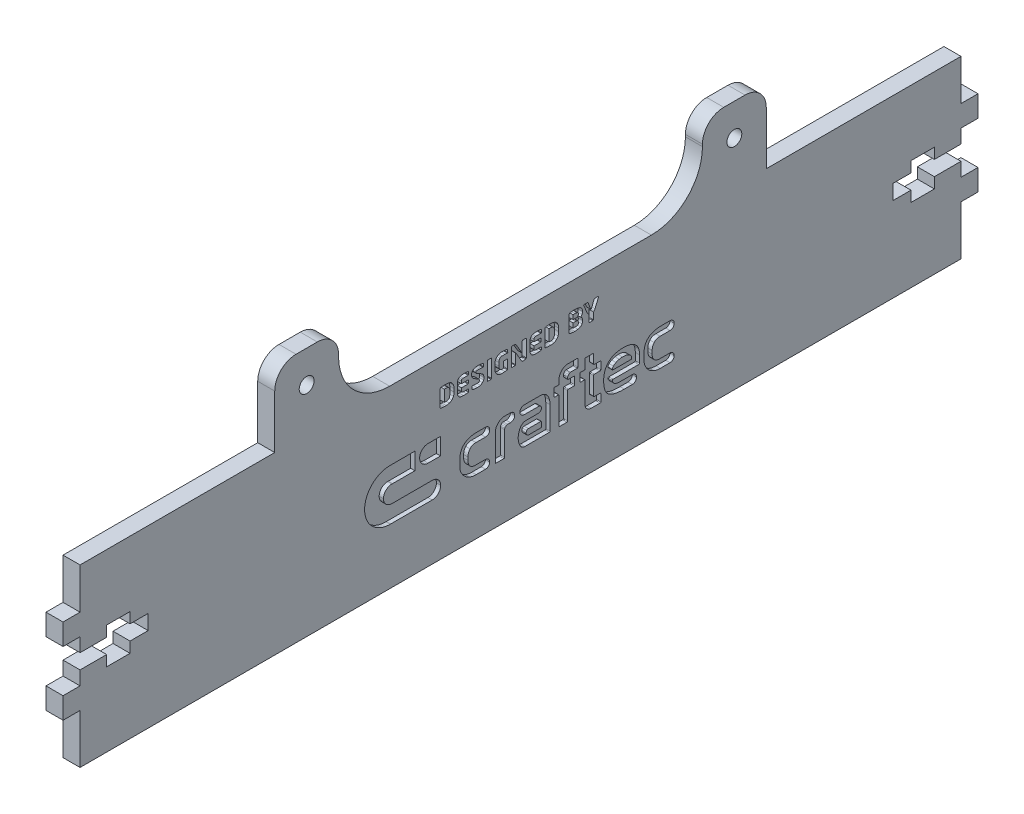
SolidWorks part; units mm, degrees
ref_plane "Plano frontal" through (0, 0, 0) normal (0, 0, 1) x (1, 0, 0)
ref_plane "Plano superior" through (0, 0, 0) normal (0, 1, 0) x (1, 0, 0)
ref_plane "Plano direito" through (0, 0, 0) normal (1, 0, 0) x (0, 0, -1)
sketch "Esboço1" plane through (0, 0, 0) normal (1, 0, 0) x (0, 0, -1)
  line L0 (-103.5, 0) -> (-87.5, 0) construction
  line L1 (-103.5, 16.61) -> (103.5, 16.61)
  line L2 (-103.5, 16.61) -> (-103.5, 10)
  line L3 (-103.5, -16.61) -> (103.5, -16.61)
  line L4 (103.5, 16.61) -> (103.5, 10)
  line L5 (-103.5, 16.61) -> (103.5, -16.61) construction
  line L6 (-103.5, -16.61) -> (103.5, 16.61) construction
  line L7 (0, 0) -> (0, 10.8206) construction
  line L8 (-103.5, 5) -> (-107.5, 5)
  line L9 (-103.5, -1.75) -> (-97.25, -1.75)
  line L11 (-103.5, 1.75) -> (-97.25, 1.75)
  line L12 (-87.5, -1.75) -> (-87.5, 1.75)
  line L13 (-103.5, -1.75) -> (-87.5, 1.75) construction
  line L14 (-103.5, 1.75) -> (-87.5, -1.75) construction
  line L15 (-97.25, 4.25) -> (-91.75, 4.25)
  line L16 (-97.25, 4.25) -> (-97.25, 1.75)
  line L17 (-97.25, -4.25) -> (-91.75, -4.25)
  line L18 (-91.75, 4.25) -> (-91.75, 1.75)
  line L19 (-97.25, 4.25) -> (-91.75, -4.25) construction
  line L20 (-97.25, -4.25) -> (-91.75, 4.25) construction
  line L21 (-107.5, 5) -> (-107.5, 10)
  line L22 (-107.5, 10) -> (-103.5, 10)
  line L23 (-103.5, -5) -> (-107.5, -5)
  line L24 (-107.5, -5) -> (-107.5, -10)
  line L25 (-107.5, -10) -> (-103.5, -10)
  line L26 (-107.5, 5) -> (-107.5, -5) construction
  line L27 (-103.5, 0) -> (-107.5, 0) construction
  line L28 (-103.5, 5) -> (-103.5, 1.75)
  line L29 (-103.5, -10) -> (-103.5, -16.61)
  line L30 (-103.5, -1.75) -> (-103.5, -5)
  line L31 (107.5, -10) -> (103.5, -10)
  line L32 (107.5, -5) -> (107.5, -10)
  line L33 (103.5, -5) -> (107.5, -5)
  line L34 (-91.75, 1.75) -> (-87.5, 1.75)
  line L35 (-91.75, -1.75) -> (-91.75, -4.25)
  line L36 (-91.75, -1.75) -> (-87.5, -1.75)
  line L37 (-97.25, -1.75) -> (-97.25, -4.25)
  line L38 (103.5, -1.75) -> (97.25, -1.75)
  line L39 (97.25, -1.75) -> (97.25, -4.25)
  line L40 (97.25, -4.25) -> (91.75, -4.25)
  line L41 (91.75, -1.75) -> (91.75, -4.25)
  line L42 (91.75, -1.75) -> (87.5, -1.75)
  line L43 (87.5, -1.75) -> (87.5, 1.75)
  line L44 (91.75, 1.75) -> (87.5, 1.75)
  line L45 (91.75, 4.25) -> (91.75, 1.75)
  line L46 (97.25, 4.25) -> (91.75, 4.25)
  line L47 (97.25, 4.25) -> (97.25, 1.75)
  line L48 (103.5, 1.75) -> (97.25, 1.75)
  line L49 (103.5, 5) -> (107.5, 5)
  line L50 (107.5, 5) -> (107.5, 10)
  line L51 (107.5, 10) -> (103.5, 10)
  line L52 (103.5, 5) -> (103.5, 1.75)
  line L53 (103.5, -1.75) -> (103.5, -5)
  line L54 (103.5, -10) -> (103.5, -16.61)
  point P0 (0, 0)
  point P10 (-95.5, 0)
  point P15 (-94.5, 0)
  dimension "D1" = 33.22
  dimension "D2" = 207
  dimension "D3" = 16
  dimension "D4" = 3.5
  dimension "D5" = 7
  dimension "D6" = 5.5
  dimension "D7" = 8.5
  dimension "D8" = 10
  dimension "D9" = 4
  dimension "D10" = 5
extrude "Ressalto-extrusão1" add sketch "Esboço1" along normal blind 4
sketch "Esboço2" plane through (4, 0, 0) normal (1, 0, 0) x (0, 0, -1)
  line L0 (0, 16.61) -> (0, 47.4851) construction
  line L1 (103.5, 16.61) -> (-103.5, 16.61) construction
  line L2 (-57.75, 19.61) -> (-57.75, 32.11)
  line L4 (-42.75, 32.11) -> (-42.75, 19.61)
  line L5 (-57.75, 19.61) -> (-42.75, 19.61) construction
  line L6 (-50.25, 19.61) -> (-50.25, 39.61) construction
  line L11 (-52.75, 37.11) -> (-47.75, 37.11)
  line L12 (57.75, 19.61) -> (57.75, 32.11)
  line L13 (57.75, 19.61) -> (42.75, 19.61) construction
  line L14 (42.75, 32.11) -> (42.75, 19.61)
  line L15 (52.75, 37.11) -> (47.75, 37.11)
  line L16 (-42.75, 19.61) -> (42.75, 19.61)
  line L18 (-103.5, 16.61) -> (103.5, 16.61)
  line L20 (-103.5, 16.61) -> (-103.5, 19.61)
  line L21 (-103.5, 19.61) -> (-57.75, 19.61)
  line L22 (103.5, 16.61) -> (103.5, 19.61)
  line L23 (103.5, 19.61) -> (57.75, 19.61)
  circle A0 centre (-50.25, 29.61) radius 1.75
  arc A2 (-47.75, 37.11) -> (-42.75, 32.11) centre (-47.75, 32.11) cw
  arc A3 (-57.75, 32.11) -> (-52.75, 37.11) centre (-52.75, 32.11) cw
  circle A4 centre (50.25, 29.61) radius 1.75
  arc A5 (47.75, 37.11) -> (42.75, 32.11) centre (47.75, 32.11) ccw
  arc A6 (57.75, 32.11) -> (52.75, 37.11) centre (52.75, 32.11) ccw
  point P21 (-42.75, 37.11)
  point P24 (-57.75, 37.11)
  dimension "D3" = 3.5
  dimension "D5" = 7.5
  dimension "D6" = 5
  dimension "D1" = 10
  dimension "D2" = 15
  dimension "D4" = 115.5
  dimension "D7" = 3
extrude "Ressalto-extrusão3" add sketch "Esboço2" against normal through all
fillet "Filete1" radius 12 2 edges at (2, 19.61, -42.75) (2, 19.61, 42.75)
sketch "Esboço5" plane through (4, 0, 0) normal (1, 0, 0) x (0, 0, -1)
  line L0 (-18.8728, 9.3104) -> (-18.8728, 13.13)
  line L1 (-15.625, 11.5747) -> (-15.625, 10.8657)
  line L2 (-17.8893, 12.5811) -> (-17.8893, 9.8822)
  line L3 (-16.6085, 10.8657) -> (-16.6085, 11.5976)
  line L4 (-14.8245, 10.2939) -> (-14.8245, 12.2151)
  line L5 (-12.1714, 13.2672) -> (-12.1714, 12.7412)
  line L6 (-12.3086, 12.6039) -> (-13.4751, 12.6039)
  line L7 (-13.8639, 12.1922) -> (-13.8639, 11.6662)
  line L8 (-13.8639, 11.6662) -> (-12.3772, 11.6662)
  line L9 (-12.24, 11.529) -> (-12.24, 10.98)
  line L10 (-12.3772, 10.8428) -> (-13.8639, 10.8428)
  line L11 (-13.8639, 10.8428) -> (-13.8639, 10.2253)
  line L12 (-13.4751, 9.8136) -> (-12.3086, 9.8136)
  line L13 (-12.1714, 9.6764) -> (-12.1714, 9.1503)
  line L14 (-11.3937, 9.2646) -> (-11.3937, 9.8364)
  line L15 (-11.3023, 9.9508) -> (-11.2794, 9.9508)
  line L16 (-10.0214, 10.7056) -> (-10.822, 11.1859)
  line L17 (-8.6949, 13.1757) -> (-8.6949, 12.5811)
  line L18 (-8.7864, 12.4896) -> (-8.8092, 12.4896)
  line L19 (-10.0901, 11.8492) -> (-9.3582, 11.4603)
  line L20 (-6.9338, 9.0817) -> (-7.7114, 9.0817)
  line L21 (-7.8029, 9.2189) -> (-7.8029, 13.2901)
  line L22 (-7.6885, 13.4044) -> (-6.9109, 13.4044)
  line L23 (-6.7965, 13.2901) -> (-6.7965, 9.2189)
  line L24 (-3.0684, 12.5124) -> (-3.0913, 12.5124)
  line L25 (-5.0583, 11.5747) -> (-5.0583, 10.8428)
  line L26 (-3.9604, 9.8822) -> (-3.9604, 11.2088)
  line L27 (-3.8689, 11.346) -> (-3.137, 11.346)
  line L28 (-2.9998, 11.2088) -> (-2.9998, 9.2647)
  line L29 (-6.0418, 10.8428) -> (-6.0418, 11.5518)
  line L30 (-2.9998, 13.1986) -> (-2.9998, 12.5811)
  line L31 (1.1171, 9.0817) -> (0.5453, 9.0817)
  line L32 (0.248, 9.2418) -> (-1.0786, 11.529)
  line L33 (-1.1472, 11.529) -> (-1.1472, 9.196)
  line L34 (-1.2844, 9.0588) -> (-1.9706, 9.0588)
  line L35 (-2.1078, 9.196) -> (-2.1078, 13.1529)
  line L36 (-1.8791, 13.3816) -> (-1.2844, 13.3816)
  line L37 (-1.0328, 13.1986) -> (0.3395, 10.8199)
  line L38 (0.4081, 10.8199) -> (0.4081, 13.2672)
  line L39 (0.5453, 13.3587) -> (1.2315, 13.3587)
  line L40 (1.3687, 13.2672) -> (1.3687, 9.3104)
  line L41 (2.2378, 10.2939) -> (2.2378, 12.2151)
  line L42 (4.891, 13.2672) -> (4.891, 12.7412)
  line L43 (4.7537, 12.6039) -> (3.5873, 12.6039)
  line L44 (3.1985, 12.1922) -> (3.1985, 11.6662)
  line L45 (3.1985, 11.6662) -> (4.6851, 11.6662)
  line L46 (4.8224, 11.529) -> (4.8224, 10.98)
  line L47 (4.6851, 10.8428) -> (3.1985, 10.8428)
  line L48 (3.1985, 10.8428) -> (3.1985, 10.2253)
  line L49 (3.5873, 9.8136) -> (4.7537, 9.8136)
  line L50 (4.891, 9.6764) -> (4.891, 9.1503)
  line L51 (5.7144, 9.3104) -> (5.7144, 13.13)
  line L52 (8.9622, 11.5747) -> (8.9622, 10.8657)
  line L53 (6.6978, 12.5811) -> (6.6978, 9.8822)
  line L54 (7.9787, 10.8657) -> (7.9787, 11.5976)
  line L55 (11.4094, 9.4705) -> (11.4094, 12.9928)
  line L56 (14.5657, 12.238) -> (14.5657, 12.1236)
  line L57 (14.5657, 10.4082) -> (14.5657, 10.3168)
  line L58 (14.5657, 10.3168) -> (14.5886, 10.3168)
  line L59 (12.3472, 12.6039) -> (12.3472, 11.5976)
  line L60 (12.3472, 11.5976) -> (12.9876, 11.5976)
  line L61 (13.5822, 12.055) -> (13.5822, 12.1465)
  line L62 (13.5822, 12.1465) -> (13.6051, 12.1465)
  line L63 (13.0105, 10.9343) -> (12.3701, 10.9343)
  line L64 (12.3701, 10.9343) -> (12.3701, 9.8593)
  line L65 (13.6051, 10.3625) -> (13.6051, 10.4082)
  line L66 (13.6051, 10.4082) -> (13.628, 10.4082)
  line L67 (18.3625, 13.2443) -> (17.4933, 11.2545)
  line L68 (17.1045, 10.8199) -> (17.1045, 9.2189)
  line L69 (16.9673, 9.0817) -> (16.2354, 9.0817)
  line L70 (16.0982, 9.2189) -> (16.0982, 10.8199)
  line L71 (15.7093, 11.2545) -> (14.8402, 13.2443)
  line L72 (14.9317, 13.3816) -> (15.7551, 13.3816)
  line L73 (15.8694, 13.2901) -> (16.487, 11.6662)
  line L74 (16.67, 11.6662) -> (17.2875, 13.2901)
  line L75 (17.4019, 13.3816) -> (18.2253, 13.3816)
  line L76 (-20.7566, -4.5541) -> (-24.997, -4.5541)
  line L77 (-24.997, -4.5541) -> (-30.2286, -4.5541)
  line L78 (-30.2286, -4.5541) -> (-30.2286, -4.5386)
  line L79 (-30.0683, -0.5624) -> (-24.9982, -0.5624)
  line L80 (-24.9982, -0.5624) -> (-24.8207, -0.5624)
  line L81 (-24.8207, -0.5624) -> (-24.8207, 3.4296)
  line L82 (-24.8207, 3.4296) -> (-30.2504, 3.4296)
  line L83 (-30.2504, 3.4296) -> (-30.2504, 3.4152)
  line L84 (-30.5068, -8.546) -> (-20.7566, -8.546)
  line L85 (-21.7095, -0.5624) -> (-18.7962, -0.5624)
  line L86 (-18.7962, -0.5624) -> (-18.7962, 3.4296)
  line L87 (-18.7962, 3.4296) -> (-21.7095, 3.4296)
  line L88 (11.2333, 0) -> (12.5792, 0)
  line L89 (12.7431, -0.164) -> (12.7431, -1.8383)
  line L90 (12.5792, -2.0024) -> (11.2333, -2.0024)
  line L91 (11.0691, -2.1667) -> (11.0691, -8.3873)
  line L92 (10.9049, -8.5515) -> (9.2307, -8.5515)
  line L93 (9.0666, -8.3873) -> (9.0666, -2.1667)
  line L94 (8.9024, -2.0024) -> (8.0326, -2.0024)
  line L95 (7.8684, -1.8383) -> (7.8684, -0.164)
  line L96 (8.0326, 0) -> (8.9024, 0)
  line L97 (9.0666, 0.1642) -> (9.0666, 1.1981)
  line L98 (10.9542, 3.217) -> (13.3013, 3.217)
  line L99 (13.4655, 3.053) -> (13.4655, 1.3787)
  line L100 (13.334, 1.2147) -> (11.7256, 1.2147)
  line L101 (11.0691, 0.5089) -> (11.0691, 0.1642)
  line L102 (17.3554, -6.5491) -> (18.7342, -6.5491)
  line L103 (18.8654, -6.7131) -> (18.8654, -8.3873)
  line L104 (18.7013, -8.5515) -> (16.6332, -8.5515)
  line L105 (15.1889, -7.2876) -> (15.1889, -2.1667)
  line L106 (15.0245, -2.0024) -> (14.1547, -2.0024)
  line L107 (13.9907, -1.8383) -> (13.9907, -0.164)
  line L108 (14.1547, 0) -> (15.0245, 0)
  line L109 (15.1889, 0.1642) -> (15.1889, 2.2158)
  line L110 (15.3528, 2.3799) -> (17.027, 2.3799)
  line L111 (17.1912, 2.2158) -> (17.1912, 0.1642)
  line L112 (17.3554, 0) -> (18.7013, 0)
  line L113 (18.8654, -0.164) -> (18.8654, -1.8383)
  line L114 (18.7013, -2.0024) -> (17.3554, -2.0024)
  line L115 (17.1912, -2.1667) -> (17.1912, -6.3847)
  line L116 (4.6511, 0) -> (0.8637, 0)
  line L117 (0.8637, -2.0011) -> (4.3395, -2.0024)
  line L118 (3.9947, -3.3811) -> (1.2538, -3.3811)
  line L119 (1.0404, -8.5515) -> (6.7687, -8.5515)
  line L120 (6.9331, -8.3873) -> (6.9331, -2.9708)
  line L121 (4.7663, -6.6311) -> (1.9432, -6.6311)
  line L122 (1.8447, -5.318) -> (4.7663, -5.318)
  line L123 (4.9303, -5.4822) -> (4.9303, -6.4669)
  line L124 (-10.4654, -6.5491) -> (-8.2303, -6.5504)
  line L125 (-12.353, -3.9884) -> (-12.353, -4.6943)
  line L126 (-10.4654, -2.0024) -> (-8.2303, -2.0011)
  line L127 (-8.2303, 0) -> (-10.1372, 0)
  line L128 (-14.2734, -3.6108) -> (-14.2734, -4.9899)
  line L129 (-10.449, -8.5515) -> (-8.2303, -8.5515)
  line L130 (32.8168, -6.5491) -> (35.1235, -6.5504)
  line L131 (30.9292, -4.6943) -> (30.9292, -3.9884)
  line L132 (32.8168, -2.0024) -> (35.1235, -2.0011)
  line L133 (35.1235, 0) -> (33.1452, 0)
  line L134 (29.0089, -3.6108) -> (29.0089, -4.9899)
  line L135 (32.8331, -8.5515) -> (35.1235, -8.5515)
  line L136 (-2.3594, 0) -> (-3.7359, 0)
  line L137 (-5.9025, -2.1502) -> (-5.9025, -8.3873)
  line L138 (-5.7384, -8.5515) -> (-3.9, -8.5515)
  line L139 (-3.7359, -8.3873) -> (-3.7359, -2.7246)
  line L140 (-3.0793, -2.0024) -> (-2.3594, -2.0011)
  line L141 (24.3803, -8.5515) -> (26.2714, -8.5515)
  line L142 (26.2714, -8.5515) -> (26.2714, -8.5477)
  line L143 (26.222, -6.5491) -> (23.2479, -6.5491)
  line L144 (21.7378, -5.236) -> (27.8107, -5.236)
  line L145 (27.9749, -5.0716) -> (27.9749, -3.3646)
  line L146 (25.9561, -3.3154) -> (21.7378, -3.3154)
  spline S0 degree 3 poles (-15.625, 10.8657) (-15.625, 10.5683) (-15.6708, 10.2939) (-15.7623, 10.0652) knots 0 0 0 0 1 1 1 1
  spline S1 degree 3 poles (-15.7623, 10.0652) (-15.8538, 9.8364) (-15.9681, 9.6535) (-16.1282, 9.4934) knots 1 1 1 1 2 2 2 2
  spline S2 degree 3 poles (-16.1282, 9.4934) (-16.2883, 9.3333) (-16.4713, 9.2189) (-16.7, 9.1503) knots 2 2 2 2 3 3 3 3
  spline S3 degree 3 poles (-16.7, 9.1503) (-16.9287, 9.0817) (-17.1803, 9.0359) (-17.4777, 9.0359) knots 3 3 3 3 4 4 4 4
  spline S4 degree 3 poles (-17.4777, 9.0359) (-17.592, 9.0359) (-17.7064, 9.0359) (-17.8436, 9.0359) knots 4 4 4 4 5 5 5 5
  spline S5 degree 3 poles (-17.8436, 9.0359) (-17.958, 9.0359) (-18.0723, 9.0588) (-18.1867, 9.0588) knots 5 5 5 5 6 6 6 6
  spline S6 degree 3 poles (-18.1867, 9.0588) (-18.301, 9.0588) (-18.3925, 9.0817) (-18.484, 9.0817) knots 6 6 6 6 7 7 7 7
  spline S7 degree 3 poles (-18.484, 9.0817) (-18.5755, 9.0817) (-18.6441, 9.1046) (-18.7127, 9.1046) knots 7 7 7 7 8 8 8 8
  spline S8 degree 3 poles (-18.7127, 9.1046) (-18.7585, 9.1046) (-18.8042, 9.1274) (-18.8271, 9.1732) knots 8 8 8 8 9 9 9 9
  spline S9 degree 3 poles (-18.8271, 9.1732) (-18.85, 9.196) (-18.8728, 9.2418) (-18.8728, 9.3104) knots 9 9 9 9 10 10 10 10
  spline S10 degree 3 poles (-18.8728, 13.13) (-18.8728, 13.1986) (-18.85, 13.2443) (-18.8271, 13.2672) knots 11 11 11 11 12 12 12 12
  spline S11 degree 3 poles (-18.8271, 13.2672) (-18.8042, 13.2901) (-18.7585, 13.313) (-18.7127, 13.3358) knots 12 12 12 12 13 13 13 13
  spline S12 degree 3 poles (-18.7127, 13.3358) (-18.6441, 13.3587) (-18.5755, 13.3587) (-18.484, 13.3587) knots 13 13 13 13 14 14 14 14
  spline S13 degree 3 poles (-18.484, 13.3587) (-18.3925, 13.3587) (-18.301, 13.3816) (-18.1867, 13.3816) knots 14 14 14 14 15 15 15 15
  spline S14 degree 3 poles (-18.1867, 13.3816) (-18.0723, 13.3816) (-17.958, 13.4045) (-17.8436, 13.4045) knots 15 15 15 15 16 16 16 16
  spline S15 degree 3 poles (-17.8436, 13.4045) (-17.7292, 13.4045) (-17.592, 13.4045) (-17.4777, 13.4045) knots 16 16 16 16 17 17 17 17
  spline S16 degree 3 poles (-17.4777, 13.4045) (-17.1803, 13.4045) (-16.9287, 13.3587) (-16.7, 13.2901) knots 17 17 17 17 18 18 18 18
  spline S17 degree 3 poles (-16.7, 13.2901) (-16.4713, 13.2215) (-16.2883, 13.1071) (-16.1282, 12.947) knots 18 18 18 18 19 19 19 19
  spline S18 degree 3 poles (-16.1282, 12.947) (-15.9681, 12.7869) (-15.8538, 12.6039) (-15.7623, 12.3752) knots 19 19 19 19 20 20 20 20
  spline S19 degree 3 poles (-15.7623, 12.3752) (-15.6708, 12.1465) (-15.625, 11.872) (-15.625, 11.5747) knots 20 20 20 20 21 21 21 21
  spline S20 degree 3 poles (-16.6085, 11.5976) (-16.6085, 11.8034) (-16.6314, 11.9635) (-16.6771, 12.0779) knots 0 0 0 0 1 1 1 1
  spline S21 degree 3 poles (-16.6771, 12.0779) (-16.7229, 12.1922) (-16.7686, 12.3066) (-16.8601, 12.3752) knots 1 1 1 1 2 2 2 2
  spline S22 degree 3 poles (-16.8601, 12.3752) (-16.9287, 12.4438) (-17.0202, 12.5124) (-17.1346, 12.5353) knots 2 2 2 2 3 3 3 3
  spline S23 degree 3 poles (-17.1346, 12.5353) (-17.2489, 12.5582) (-17.3633, 12.5811) (-17.4777, 12.5811) knots 3 3 3 3 4 4 4 4
  spline S24 degree 3 poles (-17.4777, 12.5811) (-17.5463, 12.5811) (-17.6378, 12.5811) (-17.7064, 12.5811) knots 4 4 4 4 5 5 5 5
  spline S25 degree 3 poles (-17.7064, 12.5811) (-17.775, 12.5811) (-17.8436, 12.5811) (-17.8893, 12.5811) knots 5 5 5 5 6 6 6 6
  spline S26 degree 3 poles (-17.8893, 9.8822) (-17.8436, 9.8822) (-17.775, 9.8822) (-17.7064, 9.8822) knots 7 7 7 7 8 8 8 8
  spline S27 degree 3 poles (-17.7064, 9.8822) (-17.6378, 9.8822) (-17.5463, 9.8822) (-17.4777, 9.8822) knots 8 8 8 8 9 9 9 9
  spline S28 degree 3 poles (-17.4777, 9.8822) (-17.3404, 9.8822) (-17.2261, 9.9051) (-17.1346, 9.9279) knots 9 9 9 9 10 10 10 10
  spline S29 degree 3 poles (-17.1346, 9.9279) (-17.0202, 9.9508) (-16.9516, 10.0194) (-16.8601, 10.088) knots 10 10 10 10 11 11 11 11
  spline S30 degree 3 poles (-16.8601, 10.088) (-16.7915, 10.1566) (-16.7229, 10.271) (-16.6771, 10.3854) knots 11 11 11 11 12 12 12 12
  spline S31 degree 3 poles (-16.6771, 10.3854) (-16.6314, 10.5226) (-16.6085, 10.6827) (-16.6085, 10.8657) knots 12 12 12 12 13 13 13 13
  spline S32 degree 3 poles (-12.2858, 9.1045) (-12.3772, 9.0817) (-12.5145, 9.0817) (-12.6974, 9.0588) knots 0 0 0 0 1 1 1 1
  spline S33 degree 3 poles (-12.6974, 9.0588) (-12.8804, 9.0359) (-13.1091, 9.0359) (-13.4065, 9.0359) knots 1 1 1 1 2 2 2 2
  spline S34 degree 3 poles (-13.4065, 9.0359) (-13.5894, 9.0359) (-13.7724, 9.0588) (-13.9325, 9.0817) knots 2 2 2 2 3 3 3 3
  spline S35 degree 3 poles (-13.9325, 9.0817) (-14.0926, 9.1045) (-14.2527, 9.1732) (-14.39, 9.2646) knots 3 3 3 3 4 4 4 4
  spline S36 degree 3 poles (-14.39, 9.2646) (-14.5272, 9.3561) (-14.6187, 9.4705) (-14.7102, 9.6535) knots 4 4 4 4 5 5 5 5
  spline S37 degree 3 poles (-14.7102, 9.6535) (-14.7788, 9.8136) (-14.8245, 10.0194) (-14.8245, 10.2939) knots 5 5 5 5 6 6 6 6
  spline S38 degree 3 poles (-14.8245, 12.2151) (-14.8245, 12.4667) (-14.7788, 12.6954) (-14.7102, 12.8555) knots 7 7 7 7 8 8 8 8
  spline S39 degree 3 poles (-14.7102, 12.8555) (-14.6415, 13.0156) (-14.5272, 13.1529) (-14.39, 13.2215) knots 8 8 8 8 9 9 9 9
  spline S40 degree 3 poles (-14.39, 13.2215) (-14.2527, 13.313) (-14.1155, 13.3587) (-13.9325, 13.4044) knots 9 9 9 9 10 10 10 10
  spline S41 degree 3 poles (-13.9325, 13.4044) (-13.7495, 13.4273) (-13.5894, 13.4502) (-13.4065, 13.4502) knots 10 10 10 10 11 11 11 11
  spline S42 degree 3 poles (-13.4065, 13.4502) (-13.2464, 13.4502) (-13.1091, 13.4502) (-12.9948, 13.4502) knots 11 11 11 11 12 12 12 12
  spline S43 degree 3 poles (-12.9948, 13.4502) (-12.8804, 13.4502) (-12.7661, 13.4273) (-12.6746, 13.4273) knots 12 12 12 12 13 13 13 13
  spline S44 degree 3 poles (-12.6746, 13.4273) (-12.5831, 13.4273) (-12.5145, 13.4044) (-12.4459, 13.4044) knots 13 13 13 13 14 14 14 14
  spline S45 degree 3 poles (-12.4459, 13.4044) (-12.3772, 13.4044) (-12.3315, 13.3816) (-12.2858, 13.3816) knots 14 14 14 14 15 15 15 15
  spline S46 degree 3 poles (-12.2858, 13.3816) (-12.2171, 13.3587) (-12.1714, 13.3358) (-12.1714, 13.2672) knots 15 15 15 15 16 16 16 16
  spline S47 degree 3 poles (-12.1714, 12.7412) (-12.1714, 12.7183) (-12.1943, 12.6725) (-12.2171, 12.6497) knots 17 17 17 17 18 18 18 18
  spline S48 degree 3 poles (-12.2171, 12.6497) (-12.24, 12.6268) (-12.2629, 12.6039) (-12.3086, 12.6039) knots 18 18 18 18 19 19 19 19
  spline S49 degree 3 poles (-13.4751, 12.6039) (-13.6123, 12.6039) (-13.7038, 12.5811) (-13.7724, 12.5124) knots 20 20 20 20 21 21 21 21
  spline S50 degree 3 poles (-13.7724, 12.5124) (-13.8182, 12.4667) (-13.8639, 12.3523) (-13.8639, 12.1922) knots 21 21 21 21 22 22 22 22
  spline S51 degree 3 poles (-12.3772, 11.6662) (-12.3544, 11.6662) (-12.3086, 11.6433) (-12.2858, 11.6204) knots 24 24 24 24 25 25 25 25
  spline S52 degree 3 poles (-12.2858, 11.6204) (-12.2629, 11.5976) (-12.24, 11.5747) (-12.24, 11.529) knots 25 25 25 25 26 26 26 26
  spline S53 degree 3 poles (-12.24, 10.98) (-12.24, 10.9572) (-12.2629, 10.9114) (-12.2858, 10.8886) knots 27 27 27 27 28 28 28 28
  spline S54 degree 3 poles (-12.2858, 10.8886) (-12.3086, 10.8657) (-12.3315, 10.8428) (-12.3772, 10.8428) knots 28 28 28 28 29 29 29 29
  spline S55 degree 3 poles (-13.8639, 10.2253) (-13.8639, 10.0652) (-13.841, 9.9737) (-13.7724, 9.9051) knots 31 31 31 31 32 32 32 32
  spline S56 degree 3 poles (-13.7724, 9.9051) (-13.7267, 9.8593) (-13.6123, 9.8136) (-13.4751, 9.8136) knots 32 32 32 32 33 33 33 33
  spline S57 degree 3 poles (-12.3086, 9.8136) (-12.2858, 9.8136) (-12.24, 9.7907) (-12.2171, 9.7678) knots 34 34 34 34 35 35 35 35
  spline S58 degree 3 poles (-12.2171, 9.7678) (-12.1943, 9.745) (-12.1714, 9.7221) (-12.1714, 9.6764) knots 35 35 35 35 36 36 36 36
  spline S59 degree 2 poles (-12.1714, 9.1503) (-12.2171, 9.1274) (-12.2858, 9.1045) knots 37 37 37 38 38 38
  spline S60 degree 3 poles (-8.5805, 10.2939) (-8.5805, 10.1338) (-8.6034, 9.9965) (-8.672, 9.8364) knots 0 0 0 0 1 1 1 1
  spline S61 degree 3 poles (-8.672, 9.8364) (-8.7177, 9.6763) (-8.8092, 9.562) (-8.9465, 9.4248) knots 1 1 1 1 2 2 2 2
  spline S62 degree 3 poles (-8.9465, 9.4248) (-9.0608, 9.3104) (-9.2438, 9.2189) (-9.4268, 9.1274) knots 2 2 2 2 3 3 3 3
  spline S63 degree 3 poles (-9.4268, 9.1274) (-9.6326, 9.0588) (-9.8842, 9.0131) (-10.1587, 9.0131) knots 3 3 3 3 4 4 4 4
  spline S64 degree 3 poles (-10.1587, 9.0131) (-10.3874, 9.0131) (-10.5932, 9.0359) (-10.7762, 9.0588) knots 4 4 4 4 5 5 5 5
  spline S65 degree 3 poles (-10.7762, 9.0588) (-10.9592, 9.0817) (-11.1193, 9.1045) (-11.2565, 9.1503) knots 5 5 5 5 6 6 6 6
  spline S66 degree 3 poles (-11.2565, 9.1503) (-11.2794, 9.1503) (-11.3251, 9.1732) (-11.348, 9.196) knots 6 6 6 6 7 7 7 7
  spline S67 degree 3 poles (-11.348, 9.196) (-11.3709, 9.2189) (-11.3937, 9.2418) (-11.3937, 9.2646) knots 7 7 7 7 8 8 8 8
  spline S68 degree 3 poles (-11.3937, 9.8364) (-11.3937, 9.8822) (-11.3937, 9.9051) (-11.3709, 9.9279) knots 9 9 9 9 10 10 10 10
  spline S69 degree 3 poles (-11.3709, 9.9279) (-11.348, 9.9508) (-11.3251, 9.9508) (-11.3023, 9.9508) knots 10 10 10 10 11 11 11 11
  spline S70 degree 3 poles (-11.2794, 9.9508) (-11.2108, 9.9508) (-11.1422, 9.9279) (-11.0507, 9.9279) knots 12 12 12 12 13 13 13 13
  spline S71 degree 3 poles (-11.0507, 9.9279) (-10.9592, 9.9279) (-10.8448, 9.9051) (-10.7305, 9.9051) knots 13 13 13 13 14 14 14 14
  spline S72 degree 3 poles (-10.7305, 9.9051) (-10.6161, 9.9051) (-10.5246, 9.8822) (-10.4103, 9.8822) knots 14 14 14 14 15 15 15 15
  spline S73 degree 3 poles (-10.4103, 9.8822) (-10.3188, 9.8822) (-10.2273, 9.8822) (-10.1815, 9.8822) knots 15 15 15 15 16 16 16 16
  spline S74 degree 3 poles (-10.1815, 9.8822) (-9.9757, 9.8822) (-9.8385, 9.9051) (-9.7699, 9.9737) knots 16 16 16 16 17 17 17 17
  spline S75 degree 3 poles (-9.7699, 9.9737) (-9.7012, 10.0423) (-9.6555, 10.1338) (-9.6555, 10.271) knots 17 17 17 17 18 18 18 18
  spline S76 degree 3 poles (-9.6555, 10.271) (-9.6555, 10.3625) (-9.6784, 10.4311) (-9.7241, 10.4768) knots 18 18 18 18 19 19 19 19
  spline S77 degree 3 poles (-9.7241, 10.4768) (-9.7699, 10.5455) (-9.8842, 10.6141) (-10.0214, 10.7056) knots 19 19 19 19 20 20 20 20
  spline S78 degree 3 poles (-10.822, 11.1859) (-10.9592, 11.2774) (-11.0735, 11.346) (-11.165, 11.4375) knots 21 21 21 21 22 22 22 22
  spline S79 degree 3 poles (-11.165, 11.4375) (-11.2565, 11.5289) (-11.3251, 11.6204) (-11.3709, 11.7119) knots 22 22 22 22 23 23 23 23
  spline S80 degree 3 poles (-11.3709, 11.7119) (-11.4166, 11.8034) (-11.4624, 11.8949) (-11.4852, 12.0093) knots 23 23 23 23 24 24 24 24
  spline S81 degree 3 poles (-11.4852, 12.0093) (-11.5081, 12.1007) (-11.5081, 12.2151) (-11.5081, 12.3066) knots 24 24 24 24 25 25 25 25
  spline S82 degree 3 poles (-11.5081, 12.3066) (-11.5081, 12.4667) (-11.4852, 12.6039) (-11.4395, 12.7412) knots 25 25 25 25 26 26 26 26
  spline S83 degree 3 poles (-11.4395, 12.7412) (-11.3937, 12.8784) (-11.3023, 12.9927) (-11.1879, 13.1071) knots 26 26 26 26 27 27 27 27
  spline S84 degree 3 poles (-11.1879, 13.1071) (-11.0735, 13.1986) (-10.9134, 13.2901) (-10.7305, 13.3358) knots 27 27 27 27 28 28 28 28
  spline S85 degree 3 poles (-10.7305, 13.3358) (-10.5475, 13.3816) (-10.2959, 13.4273) (-10.0214, 13.4273) knots 28 28 28 28 29 29 29 29
  spline S86 degree 3 poles (-10.0214, 13.4273) (-9.9071, 13.4273) (-9.8156, 13.4273) (-9.6784, 13.4044) knots 29 29 29 29 30 30 30 30
  spline S87 degree 3 poles (-9.6784, 13.4044) (-9.564, 13.4044) (-9.4496, 13.3816) (-9.3353, 13.3816) knots 30 30 30 30 31 31 31 31
  spline S88 degree 3 poles (-9.3353, 13.3816) (-9.2209, 13.3587) (-9.1294, 13.3587) (-9.0151, 13.3358) knots 31 31 31 31 32 32 32 32
  spline S89 degree 3 poles (-9.0151, 13.3358) (-8.9236, 13.3129) (-8.855, 13.3129) (-8.7864, 13.2901) knots 32 32 32 32 33 33 33 33
  spline S90 degree 3 poles (-8.7864, 13.2901) (-8.7635, 13.2901) (-8.7406, 13.2672) (-8.7177, 13.2443) knots 33 33 33 33 34 34 34 34
  spline S91 degree 3 poles (-8.7177, 13.2443) (-8.6949, 13.2215) (-8.6949, 13.1986) (-8.6949, 13.1757) knots 34 34 34 34 35 35 35 35
  spline S92 degree 3 poles (-8.6949, 12.5811) (-8.6949, 12.5582) (-8.6949, 12.5353) (-8.7177, 12.5124) knots 36 36 36 36 37 37 37 37
  spline S93 degree 3 poles (-8.7177, 12.5124) (-8.7406, 12.4896) (-8.7635, 12.4896) (-8.7864, 12.4896) knots 37 37 37 37 38 38 38 38
  spline S94 degree 3 poles (-8.8092, 12.4896) (-8.855, 12.4896) (-8.9236, 12.4896) (-9.0151, 12.5124) knots 39 39 39 39 40 40 40 40
  spline S95 degree 3 poles (-9.0151, 12.5124) (-9.1066, 12.5124) (-9.2209, 12.5353) (-9.3353, 12.5353) knots 40 40 40 40 41 41 41 41
  spline S96 degree 3 poles (-9.3353, 12.5353) (-9.4496, 12.5353) (-9.5869, 12.5582) (-9.7012, 12.5582) knots 41 41 41 41 42 42 42 42
  spline S97 degree 3 poles (-9.7012, 12.5582) (-9.8156, 12.5582) (-9.93, 12.5582) (-10.0443, 12.5582) knots 42 42 42 42 43 43 43 43
  spline S98 degree 3 poles (-10.0443, 12.5582) (-10.2044, 12.5582) (-10.3188, 12.5353) (-10.3874, 12.4896) knots 43 43 43 43 44 44 44 44
  spline S99 degree 3 poles (-10.3874, 12.4896) (-10.456, 12.4438) (-10.4789, 12.3523) (-10.4789, 12.2608) knots 44 44 44 44 45 45 45 45
  spline S100 degree 3 poles (-10.4789, 12.2608) (-10.4789, 12.2151) (-10.4789, 12.1922) (-10.456, 12.1465) knots 45 45 45 45 46 46 46 46
  spline S101 degree 3 poles (-10.456, 12.1465) (-10.4331, 12.1236) (-10.4331, 12.0779) (-10.3874, 12.055) knots 46 46 46 46 47 47 47 47
  spline S102 degree 3 poles (-10.3874, 12.055) (-10.3645, 12.0321) (-10.3188, 11.9864) (-10.273, 11.9635) knots 47 47 47 47 48 48 48 48
  spline S103 degree 3 poles (-10.273, 11.9635) (-10.2273, 11.9406) (-10.1587, 11.8949) (-10.0901, 11.8492) knots 48 48 48 48 49 49 49 49
  spline S104 degree 3 poles (-9.3582, 11.4603) (-9.0608, 11.3002) (-8.855, 11.1173) (-8.7406, 10.9343) knots 50 50 50 50 51 51 51 51
  spline S105 degree 3 poles (-8.7406, 10.9343) (-8.6491, 10.7513) (-8.5805, 10.5226) (-8.5805, 10.2939) knots 51 51 51 51 52 52 52 52
  spline S106 degree 3 poles (-6.8651, 9.1274) (-6.888, 9.1045) (-6.9109, 9.0817) (-6.9338, 9.0817) knots 0 0 0 0 1 1 1 1
  spline S107 degree 3 poles (-7.7114, 9.0817) (-7.7343, 9.0817) (-7.7571, 9.1046) (-7.78, 9.1274) knots 2 2 2 2 3 3 3 3
  spline S108 degree 3 poles (-7.78, 9.1274) (-7.8029, 9.1503) (-7.8029, 9.1732) (-7.8029, 9.2189) knots 3 3 3 3 4 4 4 4
  spline S109 degree 3 poles (-7.8029, 13.2901) (-7.8029, 13.3587) (-7.7571, 13.4044) (-7.6885, 13.4044) knots 5 5 5 5 6 6 6 6
  spline S110 degree 3 poles (-6.9109, 13.4044) (-6.8423, 13.4044) (-6.7965, 13.3587) (-6.7965, 13.2901) knots 7 7 7 7 8 8 8 8
  spline S111 degree 3 poles (-6.7965, 9.2189) (-6.8423, 9.1732) (-6.8423, 9.1503) (-6.8651, 9.1274) knots 9 9 9 9 10 10 10 10
  spline S112 degree 3 poles (-2.9998, 12.5353) (-3.0227, 12.5353) (-3.0455, 12.5124) (-3.0684, 12.5124) knots 0 0 0 0 1 1 1 1
  spline S113 degree 3 poles (-3.0913, 12.5124) (-3.2285, 12.5124) (-3.4115, 12.5353) (-3.6173, 12.5353) knots 2 2 2 2 3 3 3 3
  spline S114 degree 3 poles (-3.6173, 12.5353) (-3.8232, 12.5582) (-4.0519, 12.5582) (-4.3035, 12.5582) knots 3 3 3 3 4 4 4 4
  spline S115 degree 3 poles (-4.3035, 12.5582) (-4.4179, 12.5582) (-4.5322, 12.5353) (-4.6237, 12.5124) knots 4 4 4 4 5 5 5 5
  spline S116 degree 3 poles (-4.6237, 12.5124) (-4.7152, 12.4896) (-4.8067, 12.421) (-4.8524, 12.3523) knots 5 5 5 5 6 6 6 6
  spline S117 degree 3 poles (-4.8524, 12.3523) (-4.921, 12.2837) (-4.9668, 12.1694) (-5.0125, 12.055) knots 6 6 6 6 7 7 7 7
  spline S118 degree 3 poles (-5.0125, 12.055) (-5.0583, 11.9178) (-5.0583, 11.7806) (-5.0583, 11.5747) knots 7 7 7 7 8 8 8 8
  spline S119 degree 3 poles (-5.0583, 10.8428) (-5.0583, 10.637) (-5.0354, 10.4769) (-4.9896, 10.3625) knots 9 9 9 9 10 10 10 10
  spline S120 degree 3 poles (-4.9896, 10.3625) (-4.9439, 10.2253) (-4.8982, 10.1338) (-4.8295, 10.0652) knots 10 10 10 10 11 11 11 11
  spline S121 degree 3 poles (-4.8295, 10.0652) (-4.7609, 9.9965) (-4.6923, 9.9508) (-4.6237, 9.9051) knots 11 11 11 11 12 12 12 12
  spline S122 degree 3 poles (-4.6237, 9.9051) (-4.5551, 9.8822) (-4.4636, 9.8593) (-4.395, 9.8593) knots 12 12 12 12 13 13 13 13
  spline S123 degree 3 poles (-4.395, 9.8593) (-4.2349, 9.8593) (-4.0976, 9.8593) (-3.9604, 9.8822) knots 13 13 13 13 14 14 14 14
  spline S124 degree 3 poles (-3.9604, 11.2088) (-3.9604, 11.2316) (-3.9604, 11.2774) (-3.9375, 11.3002) knots 15 15 15 15 16 16 16 16
  spline S125 degree 3 poles (-3.9375, 11.3002) (-3.9147, 11.3231) (-3.8918, 11.346) (-3.8689, 11.346) knots 16 16 16 16 17 17 17 17
  spline S126 degree 3 poles (-3.137, 11.346) (-3.1142, 11.346) (-3.0684, 11.3231) (-3.0455, 11.3002) knots 18 18 18 18 19 19 19 19
  spline S127 degree 3 poles (-3.0455, 11.3002) (-3.0227, 11.2774) (-2.9998, 11.2545) (-2.9998, 11.2088) knots 19 19 19 19 20 20 20 20
  spline S128 degree 3 poles (-2.9998, 9.2647) (-2.9998, 9.196) (-3.0455, 9.1503) (-3.1142, 9.1274) knots 21 21 21 21 22 22 22 22
  spline S129 degree 3 poles (-3.1142, 9.1274) (-3.2743, 9.1045) (-3.4572, 9.0588) (-3.6631, 9.0359) knots 22 22 22 22 23 23 23 23
  spline S130 degree 3 poles (-3.6631, 9.0359) (-3.8689, 9.0131) (-4.1205, 8.9902) (-4.4179, 8.9902) knots 23 23 23 23 24 24 24 24
  spline S131 degree 3 poles (-4.4179, 8.9902) (-4.5322, 8.9902) (-4.6466, 9.0131) (-4.7609, 9.0359) knots 24 24 24 24 25 25 25 25
  spline S132 degree 3 poles (-4.7609, 9.0359) (-4.8753, 9.0588) (-5.0125, 9.1046) (-5.1269, 9.1503) knots 25 25 25 25 26 26 26 26
  spline S133 degree 3 poles (-5.1269, 9.1503) (-5.2412, 9.196) (-5.3556, 9.2875) (-5.47, 9.379) knots 26 26 26 26 27 27 27 27
  spline S134 degree 3 poles (-5.47, 9.379) (-5.5843, 9.4705) (-5.6758, 9.5849) (-5.7673, 9.7221) knots 27 27 27 27 28 28 28 28
  spline S135 degree 3 poles (-5.7673, 9.7221) (-5.8588, 9.8593) (-5.9274, 10.0194) (-5.9731, 10.2024) knots 28 28 28 28 29 29 29 29
  spline S136 degree 3 poles (-5.9731, 10.2024) (-6.0189, 10.3854) (-6.0418, 10.6141) (-6.0418, 10.8428) knots 29 29 29 29 30 30 30 30
  spline S137 degree 3 poles (-6.0418, 11.5518) (-6.0418, 11.9178) (-5.996, 12.2151) (-5.8817, 12.4667) knots 31 31 31 31 32 32 32 32
  spline S138 degree 3 poles (-5.8817, 12.4667) (-5.7673, 12.6954) (-5.6529, 12.9013) (-5.47, 13.0385) knots 32 32 32 32 33 33 33 33
  spline S139 degree 3 poles (-5.47, 13.0385) (-5.3099, 13.1757) (-5.104, 13.2672) (-4.8982, 13.3358) knots 33 33 33 33 34 34 34 34
  spline S140 degree 3 poles (-4.8982, 13.3358) (-4.6923, 13.3816) (-4.4865, 13.4273) (-4.2806, 13.4273) knots 34 34 34 34 35 35 35 35
  spline S141 degree 3 poles (-4.2806, 13.4273) (-3.9833, 13.4273) (-3.7546, 13.4045) (-3.5487, 13.3816) knots 35 35 35 35 36 36 36 36
  spline S142 degree 3 poles (-3.5487, 13.3816) (-3.3429, 13.3587) (-3.1828, 13.313) (-3.0913, 13.2901) knots 36 36 36 36 37 37 37 37
  spline S143 degree 3 poles (-3.0913, 13.2901) (-3.0227, 13.2672) (-2.9998, 13.2444) (-2.9998, 13.1986) knots 37 37 37 37 38 38 38 38
  spline S144 degree 3 poles (-2.9998, 12.5811) (-2.9769, 12.5582) (-2.9769, 12.5353) (-2.9998, 12.5353) knots 39 39 39 39 40 40 40 40
  spline S145 degree 3 poles (1.2772, 9.1503) (1.2315, 9.1045) (1.1857, 9.0817) (1.1171, 9.0817) knots 0 0 0 0 1 1 1 1
  spline S146 degree 3 poles (0.5453, 9.0817) (0.4767, 9.0817) (0.431, 9.0817) (0.3852, 9.1045) knots 2 2 2 2 3 3 3 3
  spline S147 degree 3 poles (0.3852, 9.1045) (0.3395, 9.1274) (0.2937, 9.1732) (0.248, 9.2418) knots 3 3 3 3 4 4 4 4
  spline S148 degree 2 poles (-1.0786, 11.529) (-1.1014, 11.5518) (-1.1243, 11.5747) knots 5 5 5 6 6 6
  spline S149 degree 3 poles (-1.1243, 11.5747) (-1.1472, 11.5747) (-1.1472, 11.5518) (-1.1472, 11.529) knots 6 6 6 6 7 7 7 7
  spline S150 degree 3 poles (-1.1472, 9.196) (-1.1472, 9.1732) (-1.1701, 9.1274) (-1.1929, 9.1046) knots 8 8 8 8 9 9 9 9
  spline S151 degree 3 poles (-1.1929, 9.1046) (-1.2158, 9.0817) (-1.2387, 9.0588) (-1.2844, 9.0588) knots 9 9 9 9 10 10 10 10
  spline S152 degree 3 poles (-1.9706, 9.0588) (-1.9934, 9.0588) (-2.0392, 9.0817) (-2.0621, 9.1046) knots 11 11 11 11 12 12 12 12
  spline S153 degree 3 poles (-2.0621, 9.1046) (-2.0849, 9.1274) (-2.1078, 9.1503) (-2.1078, 9.196) knots 12 12 12 12 13 13 13 13
  spline S154 degree 3 poles (-2.1078, 13.1529) (-2.1078, 13.2215) (-2.0849, 13.2672) (-2.0392, 13.313) knots 14 14 14 14 15 15 15 15
  spline S155 degree 3 poles (-2.0392, 13.313) (-1.9934, 13.3587) (-1.9477, 13.3816) (-1.8791, 13.3816) knots 15 15 15 15 16 16 16 16
  spline S156 degree 3 poles (-1.2844, 13.3816) (-1.2158, 13.3816) (-1.1701, 13.3587) (-1.1472, 13.3358) knots 17 17 17 17 18 18 18 18
  spline S157 degree 3 poles (-1.1472, 13.3358) (-1.1014, 13.313) (-1.0786, 13.2672) (-1.0328, 13.1986) knots 18 18 18 18 19 19 19 19
  spline S158 degree 2 poles (0.3395, 10.8199) (0.3624, 10.7971) (0.3852, 10.7742) knots 20 20 20 21 21 21
  spline S159 degree 3 poles (0.3852, 10.7742) (0.4081, 10.7742) (0.4081, 10.7971) (0.4081, 10.8199) knots 21 21 21 21 22 22 22 22
  spline S160 degree 3 poles (0.4081, 13.2672) (0.4081, 13.2901) (0.431, 13.313) (0.4538, 13.3358) knots 23 23 23 23 24 24 24 24
  spline S161 degree 3 poles (0.4538, 13.3358) (0.4767, 13.3587) (0.4996, 13.3587) (0.5453, 13.3587) knots 24 24 24 24 25 25 25 25
  spline S162 degree 3 poles (1.2315, 13.3587) (1.2544, 13.3587) (1.3001, 13.3587) (1.323, 13.3358) knots 26 26 26 26 27 27 27 27
  spline S163 degree 3 poles (1.323, 13.3358) (1.3458, 13.313) (1.3687, 13.2901) (1.3687, 13.2672) knots 27 27 27 27 28 28 28 28
  spline S164 degree 3 poles (1.3687, 9.3104) (1.323, 9.2418) (1.3001, 9.196) (1.2772, 9.1503) knots 29 29 29 29 30 30 30 30
  spline S165 degree 3 poles (4.7766, 9.1045) (4.6851, 9.0817) (4.5479, 9.0817) (4.3649, 9.0588) knots 0 0 0 0 1 1 1 1
  spline S166 degree 3 poles (4.3649, 9.0588) (4.1819, 9.0359) (3.9532, 9.0359) (3.6559, 9.0359) knots 1 1 1 1 2 2 2 2
  spline S167 degree 3 poles (3.6559, 9.0359) (3.4729, 9.0359) (3.2899, 9.0588) (3.1298, 9.0817) knots 2 2 2 2 3 3 3 3
  spline S168 degree 3 poles (3.1298, 9.0817) (2.9697, 9.1045) (2.8096, 9.1732) (2.6724, 9.2646) knots 3 3 3 3 4 4 4 4
  spline S169 degree 3 poles (2.6724, 9.2646) (2.5352, 9.3561) (2.4437, 9.4705) (2.3522, 9.6535) knots 4 4 4 4 5 5 5 5
  spline S170 degree 3 poles (2.3522, 9.6535) (2.2836, 9.8136) (2.2378, 10.0194) (2.2378, 10.2939) knots 5 5 5 5 6 6 6 6
  spline S171 degree 3 poles (2.2378, 12.2151) (2.2378, 12.4667) (2.2836, 12.6954) (2.3522, 12.8555) knots 7 7 7 7 8 8 8 8
  spline S172 degree 3 poles (2.3522, 12.8555) (2.4208, 13.0156) (2.5352, 13.1529) (2.6724, 13.2215) knots 8 8 8 8 9 9 9 9
  spline S173 degree 3 poles (2.6724, 13.2215) (2.8096, 13.313) (2.9469, 13.3587) (3.1298, 13.4044) knots 9 9 9 9 10 10 10 10
  spline S174 degree 3 poles (3.1298, 13.4044) (3.3128, 13.4273) (3.4729, 13.4502) (3.6559, 13.4502) knots 10 10 10 10 11 11 11 11
  spline S175 degree 3 poles (3.6559, 13.4502) (3.816, 13.4502) (3.9532, 13.4502) (4.0676, 13.4502) knots 11 11 11 11 12 12 12 12
  spline S176 degree 3 poles (4.0676, 13.4502) (4.1819, 13.4502) (4.2963, 13.4273) (4.3878, 13.4273) knots 12 12 12 12 13 13 13 13
  spline S177 degree 3 poles (4.3878, 13.4273) (4.4793, 13.4273) (4.5479, 13.4044) (4.6165, 13.4044) knots 13 13 13 13 14 14 14 14
  spline S178 degree 3 poles (4.6165, 13.4044) (4.6851, 13.4044) (4.7309, 13.3816) (4.7766, 13.3816) knots 14 14 14 14 15 15 15 15
  spline S179 degree 3 poles (4.7766, 13.3816) (4.8452, 13.3587) (4.891, 13.3358) (4.891, 13.2672) knots 15 15 15 15 16 16 16 16
  spline S180 degree 3 poles (4.891, 12.7412) (4.891, 12.7183) (4.891, 12.6725) (4.8452, 12.6497) knots 17 17 17 17 18 18 18 18
  spline S181 degree 3 poles (4.8452, 12.6497) (4.8224, 12.6268) (4.7995, 12.6039) (4.7537, 12.6039) knots 18 18 18 18 19 19 19 19
  spline S182 degree 3 poles (3.5873, 12.6039) (3.45, 12.6039) (3.3586, 12.5811) (3.2899, 12.5124) knots 20 20 20 20 21 21 21 21
  spline S183 degree 3 poles (3.2899, 12.5124) (3.2213, 12.4438) (3.1985, 12.3523) (3.1985, 12.1922) knots 21 21 21 21 22 22 22 22
  spline S184 degree 3 poles (4.6851, 11.6662) (4.708, 11.6662) (4.7537, 11.6433) (4.7766, 11.6204) knots 24 24 24 24 25 25 25 25
  spline S185 degree 3 poles (4.7766, 11.6204) (4.7995, 11.5976) (4.8224, 11.5747) (4.8224, 11.529) knots 25 25 25 25 26 26 26 26
  spline S186 degree 3 poles (4.8224, 10.98) (4.8224, 10.9572) (4.8224, 10.9114) (4.7766, 10.8886) knots 27 27 27 27 28 28 28 28
  spline S187 degree 3 poles (4.7766, 10.8886) (4.7537, 10.8657) (4.7309, 10.8428) (4.6851, 10.8428) knots 28 28 28 28 29 29 29 29
  spline S188 degree 3 poles (3.1985, 10.2253) (3.1985, 10.0652) (3.2213, 9.9737) (3.2899, 9.9051) knots 31 31 31 31 32 32 32 32
  spline S189 degree 3 poles (3.2899, 9.9051) (3.3586, 9.8365) (3.45, 9.8136) (3.5873, 9.8136) knots 32 32 32 32 33 33 33 33
  spline S190 degree 3 poles (4.7537, 9.8136) (4.7766, 9.8136) (4.8224, 9.7907) (4.8452, 9.7678) knots 34 34 34 34 35 35 35 35
  spline S191 degree 3 poles (4.8452, 9.7678) (4.8681, 9.745) (4.891, 9.7221) (4.891, 9.6764) knots 35 35 35 35 36 36 36 36
  spline S192 degree 2 poles (4.891, 9.1503) (4.8452, 9.1274) (4.7766, 9.1045) knots 37 37 37 38 38 38
  spline S193 degree 3 poles (8.9622, 10.8657) (8.9622, 10.5683) (8.9164, 10.2939) (8.8249, 10.0652) knots 0 0 0 0 1 1 1 1
  spline S194 degree 3 poles (8.8249, 10.0652) (8.7334, 9.8364) (8.6191, 9.6535) (8.459, 9.4934) knots 1 1 1 1 2 2 2 2
  spline S195 degree 3 poles (8.459, 9.4934) (8.2989, 9.3333) (8.1159, 9.2189) (7.8872, 9.1503) knots 2 2 2 2 3 3 3 3
  spline S196 degree 3 poles (7.8872, 9.1503) (7.6585, 9.0817) (7.4069, 9.0359) (7.1095, 9.0359) knots 3 3 3 3 4 4 4 4
  spline S197 degree 3 poles (7.1095, 9.0359) (6.9952, 9.0359) (6.8808, 9.0359) (6.7436, 9.0359) knots 4 4 4 4 5 5 5 5
  spline S198 degree 3 poles (6.7436, 9.0359) (6.6292, 9.0359) (6.5149, 9.0588) (6.4005, 9.0588) knots 5 5 5 5 6 6 6 6
  spline S199 degree 3 poles (6.4005, 9.0588) (6.2861, 9.0588) (6.1947, 9.0817) (6.1032, 9.0817) knots 6 6 6 6 7 7 7 7
  spline S200 degree 3 poles (6.1032, 9.0817) (6.0117, 9.0817) (5.9431, 9.1046) (5.8745, 9.1046) knots 7 7 7 7 8 8 8 8
  spline S201 degree 3 poles (5.8745, 9.1046) (5.8287, 9.1046) (5.783, 9.1274) (5.7601, 9.1732) knots 8 8 8 8 9 9 9 9
  spline S202 degree 3 poles (5.7601, 9.1732) (5.7372, 9.196) (5.7144, 9.2418) (5.7144, 9.3104) knots 9 9 9 9 10 10 10 10
  spline S203 degree 3 poles (5.7144, 13.13) (5.7144, 13.1986) (5.7372, 13.2443) (5.7601, 13.2672) knots 11 11 11 11 12 12 12 12
  spline S204 degree 3 poles (5.7601, 13.2672) (5.783, 13.2901) (5.8287, 13.313) (5.8745, 13.3358) knots 12 12 12 12 13 13 13 13
  spline S205 degree 3 poles (5.8745, 13.3358) (5.9431, 13.3587) (6.0117, 13.3587) (6.1032, 13.3587) knots 13 13 13 13 14 14 14 14
  spline S206 degree 3 poles (6.1032, 13.3587) (6.1947, 13.3587) (6.2861, 13.3816) (6.4005, 13.3816) knots 14 14 14 14 15 15 15 15
  spline S207 degree 3 poles (6.4005, 13.3816) (6.5149, 13.3816) (6.6292, 13.4045) (6.7436, 13.4045) knots 15 15 15 15 16 16 16 16
  spline S208 degree 3 poles (6.7436, 13.4045) (6.8579, 13.4045) (6.9952, 13.4045) (7.1095, 13.4045) knots 16 16 16 16 17 17 17 17
  spline S209 degree 3 poles (7.1095, 13.4045) (7.4069, 13.4045) (7.6585, 13.3587) (7.8872, 13.2901) knots 17 17 17 17 18 18 18 18
  spline S210 degree 3 poles (7.8872, 13.2901) (8.1159, 13.2215) (8.2989, 13.1071) (8.459, 12.947) knots 18 18 18 18 19 19 19 19
  spline S211 degree 3 poles (8.459, 12.947) (8.6191, 12.7869) (8.7334, 12.6039) (8.8249, 12.3752) knots 19 19 19 19 20 20 20 20
  spline S212 degree 3 poles (8.8249, 12.3752) (8.9164, 12.1465) (8.9622, 11.872) (8.9622, 11.5747) knots 20 20 20 20 21 21 21 21
  spline S213 degree 3 poles (7.9787, 11.5976) (7.9787, 11.8034) (7.9558, 11.9635) (7.91, 12.0779) knots 0 0 0 0 1 1 1 1
  spline S214 degree 3 poles (7.91, 12.0779) (7.8643, 12.1922) (7.8186, 12.3066) (7.7271, 12.3752) knots 1 1 1 1 2 2 2 2
  spline S215 degree 3 poles (7.7271, 12.3752) (7.6585, 12.4438) (7.567, 12.5124) (7.4526, 12.5353) knots 2 2 2 2 3 3 3 3
  spline S216 degree 3 poles (7.4526, 12.5353) (7.3383, 12.5582) (7.2239, 12.5811) (7.1095, 12.5811) knots 3 3 3 3 4 4 4 4
  spline S217 degree 3 poles (7.1095, 12.5811) (7.0409, 12.5811) (6.9494, 12.5811) (6.8808, 12.5811) knots 4 4 4 4 5 5 5 5
  spline S218 degree 3 poles (6.8808, 12.5811) (6.8122, 12.5811) (6.7436, 12.5811) (6.6978, 12.5811) knots 5 5 5 5 6 6 6 6
  spline S219 degree 3 poles (6.6978, 9.8822) (6.7436, 9.8822) (6.8122, 9.8822) (6.8808, 9.8822) knots 7 7 7 7 8 8 8 8
  spline S220 degree 3 poles (6.8808, 9.8822) (6.9494, 9.8822) (7.0409, 9.8822) (7.1095, 9.8822) knots 8 8 8 8 9 9 9 9
  spline S221 degree 3 poles (7.1095, 9.8822) (7.2468, 9.8822) (7.3611, 9.9051) (7.4526, 9.9279) knots 9 9 9 9 10 10 10 10
  spline S222 degree 3 poles (7.4526, 9.9279) (7.567, 9.9508) (7.6356, 10.0194) (7.7271, 10.088) knots 10 10 10 10 11 11 11 11
  spline S223 degree 3 poles (7.7271, 10.088) (7.7957, 10.1566) (7.8643, 10.271) (7.91, 10.3854) knots 11 11 11 11 12 12 12 12
  spline S224 degree 3 poles (7.91, 10.3854) (7.9558, 10.5226) (7.9787, 10.6827) (7.9787, 10.8657) knots 12 12 12 12 13 13 13 13
  spline S225 degree 3 poles (14.5886, 10.3168) (14.5886, 10.0652) (14.5429, 9.8593) (14.4514, 9.6763) knots 0 0 0 0 1 1 1 1
  spline S226 degree 3 poles (14.4514, 9.6763) (14.3599, 9.5162) (14.2227, 9.379) (14.0626, 9.2875) knots 1 1 1 1 2 2 2 2
  spline S227 degree 3 poles (14.0626, 9.2875) (13.9025, 9.196) (13.6966, 9.1274) (13.4908, 9.0817) knots 2 2 2 2 3 3 3 3
  spline S228 degree 3 poles (13.4908, 9.0817) (13.262, 9.0359) (13.0333, 9.0131) (12.7817, 9.0131) knots 3 3 3 3 4 4 4 4
  spline S229 degree 3 poles (12.7817, 9.0131) (12.6903, 9.0131) (12.5759, 9.0131) (12.4844, 9.0131) knots 4 4 4 4 5 5 5 5
  spline S230 degree 3 poles (12.4844, 9.0131) (12.3929, 9.0131) (12.2786, 9.0131) (12.1871, 9.0359) knots 5 5 5 5 6 6 6 6
  spline S231 degree 3 poles (12.1871, 9.0359) (12.0956, 9.0359) (12.0041, 9.0588) (11.9355, 9.0588) knots 6 6 6 6 7 7 7 7
  spline S232 degree 3 poles (11.9355, 9.0588) (11.8669, 9.0588) (11.7754, 9.0817) (11.7296, 9.0817) knots 7 7 7 7 8 8 8 8
  spline S233 degree 3 poles (11.7296, 9.0817) (11.6153, 9.1046) (11.5238, 9.1274) (11.478, 9.196) knots 8 8 8 8 9 9 9 9
  spline S234 degree 3 poles (11.478, 9.196) (11.4323, 9.2418) (11.4094, 9.3333) (11.4094, 9.4705) knots 9 9 9 9 10 10 10 10
  spline S235 degree 3 poles (11.4094, 12.9928) (11.4094, 13.13) (11.4323, 13.2215) (11.478, 13.2672) knots 11 11 11 11 12 12 12 12
  spline S236 degree 3 poles (11.478, 13.2672) (11.5238, 13.313) (11.5924, 13.3587) (11.7068, 13.3816) knots 12 12 12 12 13 13 13 13
  spline S237 degree 3 poles (11.7068, 13.3816) (11.7525, 13.3816) (11.8211, 13.4044) (11.8897, 13.4044) knots 13 13 13 13 14 14 14 14
  spline S238 degree 3 poles (11.8897, 13.4044) (11.9583, 13.4044) (12.0498, 13.4273) (12.1413, 13.4273) knots 14 14 14 14 15 15 15 15
  spline S239 degree 3 poles (12.1413, 13.4273) (12.2328, 13.4273) (12.3243, 13.4273) (12.4387, 13.4502) knots 15 15 15 15 16 16 16 16
  spline S240 degree 3 poles (12.4387, 13.4502) (12.5301, 13.4502) (12.6445, 13.4502) (12.736, 13.4502) knots 16 16 16 16 17 17 17 17
  spline S241 degree 3 poles (12.736, 13.4502) (13.0105, 13.4502) (13.262, 13.4273) (13.4908, 13.3816) knots 17 17 17 17 18 18 18 18
  spline S242 degree 3 poles (13.4908, 13.3816) (13.7195, 13.3358) (13.9024, 13.2672) (14.0626, 13.1757) knots 18 18 18 18 19 19 19 19
  spline S243 degree 3 poles (14.0626, 13.1757) (14.2227, 13.0842) (14.337, 12.9699) (14.4285, 12.8098) knots 19 19 19 19 20 20 20 20
  spline S244 degree 3 poles (14.4285, 12.8098) (14.52, 12.6497) (14.5657, 12.4667) (14.5657, 12.238) knots 20 20 20 20 21 21 21 21
  spline S245 degree 3 poles (14.5657, 12.1236) (14.5657, 11.9407) (14.52, 11.7577) (14.4285, 11.6204) knots 22 22 22 22 23 23 23 23
  spline S246 degree 3 poles (14.4285, 11.6204) (14.337, 11.4603) (14.2227, 11.346) (14.0626, 11.2774) knots 23 23 23 23 24 24 24 24
  spline S247 degree 3 poles (14.0626, 11.2774) (14.2227, 11.2088) (14.337, 11.0944) (14.4285, 10.9343) knots 24 24 24 24 25 25 25 25
  spline S248 degree 3 poles (14.4285, 10.9343) (14.52, 10.7971) (14.5657, 10.6141) (14.5657, 10.4082) knots 25 25 25 25 26 26 26 26
  spline S249 degree 3 poles (13.6051, 12.1465) (13.6051, 12.3066) (13.5365, 12.421) (13.4222, 12.4896) knots 0 0 0 0 1 1 1 1
  spline S250 degree 3 poles (13.4222, 12.4896) (13.3078, 12.5582) (13.102, 12.6039) (12.8046, 12.6039) knots 1 1 1 1 2 2 2 2
  spline S251 degree 3 poles (12.8046, 12.6039) (12.7817, 12.6039) (12.7589, 12.6039) (12.7131, 12.6039) knots 2 2 2 2 3 3 3 3
  spline S252 degree 3 poles (12.7131, 12.6039) (12.6674, 12.6039) (12.6216, 12.6039) (12.5759, 12.6039) knots 3 3 3 3 4 4 4 4
  spline S253 degree 3 poles (12.5759, 12.6039) (12.5302, 12.6039) (12.4844, 12.6039) (12.4387, 12.6039) knots 4 4 4 4 5 5 5 5
  spline S254 degree 3 poles (12.4387, 12.6039) (12.3929, 12.6039) (12.3701, 12.6039) (12.3472, 12.6039) knots 5 5 5 5 6 6 6 6
  spline S255 degree 3 poles (12.9876, 11.5976) (13.1019, 11.5976) (13.1934, 11.6204) (13.2849, 11.6433) knots 8 8 8 8 9 9 9 9
  spline S256 degree 3 poles (13.2849, 11.6433) (13.3535, 11.6662) (13.4222, 11.7119) (13.4679, 11.7348) knots 9 9 9 9 10 10 10 10
  spline S257 degree 3 poles (13.4679, 11.7348) (13.5136, 11.7805) (13.5365, 11.8263) (13.5594, 11.872) knots 10 10 10 10 11 11 11 11
  spline S258 degree 3 poles (13.5594, 11.872) (13.5822, 11.9178) (13.5822, 11.9864) (13.5822, 12.055) knots 11 11 11 11 12 12 12 12
  spline S259 degree 3 poles (13.628, 10.4082) (13.628, 10.5455) (13.5823, 10.6598) (13.4908, 10.7742) knots 0 0 0 0 1 1 1 1
  spline S260 degree 3 poles (13.4908, 10.7742) (13.3993, 10.8885) (13.2392, 10.9343) (13.0105, 10.9343) knots 1 1 1 1 2 2 2 2
  spline S261 degree 3 poles (12.3701, 9.8593) (12.3929, 9.8593) (12.4158, 9.8593) (12.4615, 9.8593) knots 4 4 4 4 5 5 5 5
  spline S262 degree 3 poles (12.4615, 9.8593) (12.5073, 9.8593) (12.553, 9.8593) (12.5988, 9.8593) knots 5 5 5 5 6 6 6 6
  spline S263 degree 3 poles (12.5988, 9.8593) (12.6445, 9.8593) (12.6903, 9.8593) (12.736, 9.8593) knots 6 6 6 6 7 7 7 7
  spline S264 degree 3 poles (12.736, 9.8593) (12.7817, 9.8593) (12.8046, 9.8593) (12.8275, 9.8593) knots 7 7 7 7 8 8 8 8
  spline S265 degree 3 poles (12.8275, 9.8593) (13.1248, 9.8593) (13.3307, 9.9051) (13.445, 9.9966) knots 8 8 8 8 9 9 9 9
  spline S266 degree 3 poles (13.445, 9.9966) (13.5594, 10.088) (13.6051, 10.2024) (13.6051, 10.3625) knots 9 9 9 9 10 10 10 10
  spline S267 degree 3 poles (18.3625, 13.2901) (18.3625, 13.2672) (18.3625, 13.2672) (18.3625, 13.2443) knots 0 0 0 0 1 1 1 1
  spline S268 degree 3 poles (17.4933, 11.2545) (17.4247, 11.1173) (17.379, 11.0258) (17.3104, 10.9572) knots 2 2 2 2 3 3 3 3
  spline S269 degree 3 poles (17.3104, 10.9572) (17.2418, 10.8885) (17.1731, 10.8428) (17.1045, 10.8199) knots 3 3 3 3 4 4 4 4
  spline S270 degree 3 poles (17.1045, 9.2189) (17.1045, 9.196) (17.1045, 9.1503) (17.0588, 9.1274) knots 5 5 5 5 6 6 6 6
  spline S271 degree 3 poles (17.0588, 9.1274) (17.0359, 9.1045) (17.013, 9.0817) (16.9673, 9.0817) knots 6 6 6 6 7 7 7 7
  spline S272 degree 3 poles (16.2354, 9.0817) (16.2125, 9.0817) (16.1668, 9.1046) (16.1439, 9.1274) knots 8 8 8 8 9 9 9 9
  spline S273 degree 3 poles (16.1439, 9.1274) (16.121, 9.1503) (16.0982, 9.1732) (16.0982, 9.2189) knots 9 9 9 9 10 10 10 10
  spline S274 degree 3 poles (16.0982, 10.8199) (16.0295, 10.8428) (15.9609, 10.8885) (15.8923, 10.9572) knots 11 11 11 11 12 12 12 12
  spline S275 degree 3 poles (15.8923, 10.9572) (15.8237, 11.0258) (15.778, 11.1173) (15.7093, 11.2545) knots 12 12 12 12 13 13 13 13
  spline S276 degree 2 poles (14.8402, 13.2443) (14.8402, 13.2672) (14.8402, 13.2901) knots 14 14 14 15 15 15
  spline S277 degree 3 poles (14.8402, 13.2901) (14.8402, 13.313) (14.8402, 13.3358) (14.8631, 13.3587) knots 15 15 15 15 16 16 16 16
  spline S278 degree 3 poles (14.8631, 13.3587) (14.886, 13.3816) (14.9088, 13.3816) (14.9317, 13.3816) knots 16 16 16 16 17 17 17 17
  spline S279 degree 3 poles (15.7551, 13.3816) (15.778, 13.3816) (15.8008, 13.3816) (15.8237, 13.3587) knots 18 18 18 18 19 19 19 19
  spline S280 degree 3 poles (15.8237, 13.3587) (15.8466, 13.3358) (15.8466, 13.313) (15.8694, 13.2901) knots 19 19 19 19 20 20 20 20
  spline S281 degree 3 poles (16.487, 11.6662) (16.5099, 11.6204) (16.5099, 11.5976) (16.5327, 11.5976) knots 21 21 21 21 22 22 22 22
  spline S282 degree 3 poles (16.5327, 11.5976) (16.5556, 11.5976) (16.5556, 11.5747) (16.5785, 11.5747) knots 22 22 22 22 23 23 23 23
  spline S283 degree 3 poles (16.5785, 11.5747) (16.6014, 11.5747) (16.6242, 11.5747) (16.6242, 11.5976) knots 23 23 23 23 24 24 24 24
  spline S284 degree 2 poles (16.6242, 11.5976) (16.6471, 11.6204) (16.67, 11.6662) knots 24 24 24 25 25 25
  spline S285 degree 3 poles (17.2875, 13.2901) (17.2875, 13.313) (17.3104, 13.3358) (17.3333, 13.3587) knots 26 26 26 26 27 27 27 27
  spline S286 degree 3 poles (17.3333, 13.3587) (17.3561, 13.3816) (17.379, 13.3816) (17.4019, 13.3816) knots 27 27 27 27 28 28 28 28
  spline S287 degree 3 poles (18.2253, 13.3816) (18.2481, 13.3816) (18.271, 13.3816) (18.2939, 13.3587) knots 29 29 29 29 30 30 30 30
  spline S288 degree 3 poles (18.2939, 13.3587) (18.3625, 13.3358) (18.3625, 13.313) (18.3625, 13.2901) knots 30 30 30 30 31 31 31 31
  spline S289 degree 3 poles (-30.2286, -4.5386) (-31.3239, -4.5329) (-32.2102, -3.6438) (-32.2102, -2.547) knots 3 3 3 3 4 4 4 4
  spline S290 degree 3 poles (-32.2102, -2.547) (-32.2102, -1.4469) (-31.3183, -0.5549) (-30.2181, -0.5549) knots 4 4 4 4 5 5 5 5
  spline S291 degree 3 poles (-30.2181, -0.5549) (-30.1675, -0.5549) (-30.1179, -0.5587) (-30.0683, -0.5624) knots 5 5 5 5 6 6 6 6
  spline S292 degree 3 poles (-30.2504, 3.4152) (-30.381, 3.4237) (-30.5124, 3.4296) (-30.6452, 3.4296) knots 11 11 11 11 12 12 12 12
  spline S293 degree 3 poles (-30.6452, 3.4296) (-33.9531, 3.4296) (-36.6346, 0.7478) (-36.6346, -2.56) knots 12 12 12 12 13 13 13 13
  spline S294 degree 3 poles (-36.6346, -2.56) (-36.6346, -5.868) (-33.9531, -8.5495) (-30.6452, -8.5495) knots 13 13 13 13 14 14 14 14
  spline S295 degree 3 poles (-30.6452, -8.5495) (-30.5988, -8.5495) (-30.553, -8.547) (-30.5068, -8.546) knots 14 14 14 14 15 15 15 15
  spline S296 degree 3 poles (-20.7566, -8.546) (-19.6542, -8.546) (-18.7606, -7.6524) (-18.7606, -6.5499) knots 16 16 16 16 17 17 17 17
  spline S297 degree 3 poles (-18.7606, -6.5499) (-18.7606, -5.4477) (-19.6542, -4.5541) (-20.7566, -4.5541) knots 17 17 17 17 18 18 18 18
  spline S298 degree 3 poles (-21.7095, 3.4296) (-22.8117, 3.4296) (-23.7053, 2.5358) (-23.7053, 1.4336) knots 0 0 0 0 1 1 1 1
  spline S299 degree 3 poles (-23.7053, 1.4336) (-23.7053, 0.3312) (-22.8117, -0.5624) (-21.7095, -0.5624) knots 1 1 1 1 2 2 2 2
  spline S300 degree 3 poles (11.0691, 0.1642) (11.0691, 0.0547) (11.1238, 0) (11.2333, 0) knots 0 0 0 0 1 1 1 1
  spline S301 degree 3 poles (12.5792, 0) (12.6883, 0) (12.7431, -0.0549) (12.7431, -0.164) knots 2 2 2 2 3 3 3 3
  spline S302 degree 3 poles (12.7431, -1.8383) (12.7431, -1.9478) (12.6883, -2.0024) (12.5792, -2.0024) knots 4 4 4 4 5 5 5 5
  spline S303 degree 3 poles (11.2333, -2.0024) (11.1238, -2.0024) (11.0691, -2.0575) (11.0691, -2.1667) knots 6 6 6 6 7 7 7 7
  spline S304 degree 3 poles (11.0691, -8.3873) (11.0691, -8.4967) (11.0141, -8.5515) (10.9049, -8.5515) knots 8 8 8 8 9 9 9 9
  spline S305 degree 3 poles (9.2307, -8.5515) (9.1213, -8.5515) (9.0666, -8.4967) (9.0666, -8.3873) knots 10 10 10 10 11 11 11 11
  spline S306 degree 3 poles (9.0666, -2.1667) (9.0666, -2.0575) (9.0116, -2.0024) (8.9024, -2.0024) knots 12 12 12 12 13 13 13 13
  spline S307 degree 3 poles (8.0326, -2.0024) (7.9231, -2.0024) (7.8684, -1.9478) (7.8684, -1.8383) knots 14 14 14 14 15 15 15 15
  spline S308 degree 3 poles (7.8684, -0.164) (7.8684, -0.0549) (7.9231, 0) (8.0326, 0) knots 16 16 16 16 17 17 17 17
  spline S309 degree 3 poles (8.9024, 0) (9.0116, 0) (9.0666, 0.0547) (9.0666, 0.1642) knots 18 18 18 18 19 19 19 19
  spline S310 degree 3 poles (9.0666, 1.1981) (9.0666, 1.4387) (9.124, 1.6825) (9.239, 1.9287) knots 20 20 20 20 21 21 21 21
  spline S311 degree 3 poles (9.239, 1.9287) (9.3539, 2.1748) (9.5016, 2.3908) (9.6823, 2.577) knots 21 21 21 21 22 22 22 22
  spline S312 degree 3 poles (9.6823, 2.577) (9.8627, 2.7629) (10.0651, 2.9161) (10.2895, 3.0364) knots 22 22 22 22 23 23 23 23
  spline S313 degree 3 poles (10.2895, 3.0364) (10.5136, 3.1568) (10.7353, 3.217) (10.9542, 3.217) knots 23 23 23 23 24 24 24 24
  spline S314 degree 3 poles (13.3013, 3.217) (13.4108, 3.217) (13.4655, 3.1622) (13.4655, 3.053) knots 25 25 25 25 26 26 26 26
  spline S315 degree 3 poles (13.4655, 1.3787) (13.4655, 1.2692) (13.4215, 1.2147) (13.334, 1.2147) knots 27 27 27 27 28 28 28 28
  spline S316 degree 3 poles (11.7256, 1.2147) (11.6708, 1.2147) (11.6051, 1.1899) (11.5287, 1.1407) knots 29 29 29 29 30 30 30 30
  spline S317 degree 3 poles (11.5287, 1.1407) (11.452, 1.0915) (11.381, 1.0312) (11.3153, 0.9602) knots 30 30 30 30 31 31 31 31
  spline S318 degree 3 poles (11.3153, 0.9602) (11.2495, 0.889) (11.1923, 0.8124) (11.1431, 0.7305) knots 31 31 31 31 32 32 32 32
  spline S319 degree 3 poles (11.1431, 0.7305) (11.0938, 0.6484) (11.0691, 0.5745) (11.0691, 0.5089) knots 32 32 32 32 33 33 33 33
  spline S320 degree 3 poles (17.1912, -6.3847) (17.1912, -6.4944) (17.2459, -6.5491) (17.3554, -6.5491) knots 0 0 0 0 1 1 1 1
  spline S321 degree 3 poles (18.7342, -6.5491) (18.8214, -6.5599) (18.8654, -6.6146) (18.8654, -6.7131) knots 2 2 2 2 3 3 3 3
  spline S322 degree 3 poles (18.8654, -8.3873) (18.8654, -8.4967) (18.8107, -8.5515) (18.7013, -8.5515) knots 4 4 4 4 5 5 5 5
  spline S323 degree 3 poles (16.6332, -8.5515) (16.2172, -8.5515) (15.8726, -8.4258) (15.5992, -8.1739) knots 6 6 6 6 7 7 7 7
  spline S324 degree 3 poles (15.5992, -8.1739) (15.3254, -7.9223) (15.1889, -7.6269) (15.1889, -7.2876) knots 7 7 7 7 8 8 8 8
  spline S325 degree 3 poles (15.1889, -2.1667) (15.1889, -2.0575) (15.134, -2.0024) (15.0245, -2.0024) knots 9 9 9 9 10 10 10 10
  spline S326 degree 3 poles (14.1547, -2.0024) (14.0452, -2.0024) (13.9907, -1.9478) (13.9907, -1.8383) knots 11 11 11 11 12 12 12 12
  spline S327 degree 3 poles (13.9907, -0.164) (13.9907, -0.0549) (14.0452, 0) (14.1547, 0) knots 13 13 13 13 14 14 14 14
  spline S328 degree 3 poles (15.0245, 0) (15.134, 0) (15.1889, 0.0547) (15.1889, 0.1642) knots 15 15 15 15 16 16 16 16
  spline S329 degree 3 poles (15.1889, 2.2158) (15.1889, 2.3251) (15.2436, 2.3799) (15.3528, 2.3799) knots 17 17 17 17 18 18 18 18
  spline S330 degree 3 poles (17.027, 2.3799) (17.1365, 2.3799) (17.1912, 2.3251) (17.1912, 2.2158) knots 19 19 19 19 20 20 20 20
  spline S331 degree 3 poles (17.1912, 0.1642) (17.1912, 0.0547) (17.2459, 0) (17.3554, 0) knots 21 21 21 21 22 22 22 22
  spline S332 degree 3 poles (18.7013, 0) (18.8107, 0) (18.8654, -0.0549) (18.8654, -0.164) knots 23 23 23 23 24 24 24 24
  spline S333 degree 3 poles (18.8654, -1.8383) (18.8654, -1.9478) (18.8107, -2.0024) (18.7013, -2.0024) knots 25 25 25 25 26 26 26 26
  spline S334 degree 3 poles (17.3554, -2.0024) (17.2459, -2.0024) (17.1912, -2.0575) (17.1912, -2.1667) knots 27 27 27 27 28 28 28 28
  spline S335 degree 3 poles (6.8099, -1.9204) (6.7277, -1.5703) (6.5965, -1.2531) (6.4158, -0.9683) knots 0 0 0 0 1 1 1 1
  spline S336 degree 3 poles (6.4158, -0.9683) (6.2354, -0.684) (6, -0.4513) (5.7099, -0.2709) knots 1 1 1 1 2 2 2 2
  spline S337 degree 3 poles (5.7099, -0.2709) (5.42, -0.0903) (5.0672, 0) (4.6511, 0) knots 2 2 2 2 3 3 3 3
  spline S338 degree 3 poles (0.8637, 0) (0.3112, 0) (-0.1368, -0.4479) (-0.1368, -1.0005) knots 4 4 4 4 5 5 5 5
  spline S339 degree 3 poles (-0.1368, -1.0005) (-0.1368, -1.5532) (0.3112, -2.0011) (0.8637, -2.0011) knots 5 5 5 5 6 6 6 6
  spline S340 degree 3 poles (4.3395, -2.0024) (4.5142, -2.0024) (4.6566, -2.079) (4.7663, -2.2321) knots 8 8 8 8 9 9 9 9
  spline S341 degree 3 poles (4.7663, -2.2321) (4.8753, -2.3857) (4.9303, -2.5387) (4.9303, -2.6918) knots 9 9 9 9 10 10 10 10
  spline S342 degree 3 poles (4.9303, -2.6918) (4.9303, -2.8779) (4.8455, -3.0393) (4.6759, -3.176) knots 10 10 10 10 11 11 11 11
  spline S343 degree 3 poles (4.6759, -3.176) (4.5062, -3.3129) (4.2791, -3.3811) (3.9947, -3.3811) knots 11 11 11 11 12 12 12 12
  spline S344 degree 3 poles (1.2538, -3.3811) (0.9254, -3.3811) (0.6465, -3.4744) (0.4167, -3.66) knots 13 13 13 13 14 14 14 14
  spline S345 degree 3 poles (0.4167, -3.66) (0.1868, -3.8464) (0.0008, -4.0733) (-0.1413, -4.3414) knots 14 14 14 14 15 15 15 15
  spline S346 degree 3 poles (-0.1413, -4.3414) (-0.2837, -4.6096) (-0.3877, -4.9022) (-0.4534, -5.2195) knots 15 15 15 15 16 16 16 16
  spline S347 degree 3 poles (-0.4534, -5.2195) (-0.5189, -5.5369) (-0.5519, -5.8268) (-0.5519, -6.0894) knots 16 16 16 16 17 17 17 17
  spline S348 degree 3 poles (-0.5519, -6.0894) (-0.5519, -6.2318) (-0.5301, -6.4397) (-0.4861, -6.7131) knots 17 17 17 17 18 18 18 18
  spline S349 degree 3 poles (-0.4861, -6.7131) (-0.4425, -6.9867) (-0.363, -7.2606) (-0.2481, -7.5337) knots 18 18 18 18 19 19 19 19
  spline S350 degree 3 poles (-0.2481, -7.5337) (-0.1333, -7.8076) (0.0281, -8.0454) (0.2362, -8.2479) knots 19 19 19 19 20 20 20 20
  spline S351 degree 3 poles (0.2362, -8.2479) (0.4436, -8.4505) (0.7123, -8.5515) (1.0404, -8.5515) knots 20 20 20 20 21 21 21 21
  spline S352 degree 3 poles (6.7687, -8.5515) (6.8778, -8.5515) (6.9331, -8.4967) (6.9331, -8.3873) knots 22 22 22 22 23 23 23 23
  spline S353 degree 3 poles (6.9331, -2.9708) (6.9331, -2.6207) (6.8918, -2.2706) (6.8099, -1.9204) knots 24 24 24 24 25 25 25 25
  spline S354 degree 3 poles (4.9303, -6.4669) (4.9303, -6.5764) (4.8753, -6.6311) (4.7663, -6.6311) knots 0 0 0 0 1 1 1 1
  spline S355 degree 3 poles (1.9432, -6.6311) (1.7463, -6.6311) (1.5928, -6.5599) (1.4836, -6.4177) knots 2 2 2 2 3 3 3 3
  spline S356 degree 3 poles (1.4836, -6.4177) (1.3739, -6.2755) (1.3195, -6.1114) (1.3195, -5.9252) knots 3 3 3 3 4 4 4 4
  spline S357 degree 3 poles (1.3195, -5.9252) (1.3195, -5.7723) (1.3687, -5.6326) (1.4671, -5.5069) knots 4 4 4 4 5 5 5 5
  spline S358 degree 3 poles (1.4671, -5.5069) (1.5656, -5.381) (1.6913, -5.318) (1.8447, -5.318) knots 5 5 5 5 6 6 6 6
  spline S359 degree 3 poles (4.7663, -5.318) (4.8753, -5.318) (4.9303, -5.373) (4.9303, -5.4822) knots 7 7 7 7 8 8 8 8
  spline S360 degree 3 poles (-10.4654, -6.5491) (-11.1219, -6.5491) (-11.6008, -6.3767) (-11.9017, -6.0319) knots 2 2 2 2 3 3 3 3
  spline S361 degree 3 poles (-11.9017, -6.0319) (-12.2027, -5.6873) (-12.353, -5.2415) (-12.353, -4.6943) knots 3 3 3 3 4 4 4 4
  spline S362 degree 3 poles (-12.353, -3.9884) (-12.353, -3.4304) (-12.197, -2.9601) (-11.8852, -2.5768) knots 5 5 5 5 6 6 6 6
  spline S363 degree 3 poles (-11.8852, -2.5768) (-11.5734, -2.194) (-11.1002, -2.0024) (-10.4654, -2.0024) knots 6 6 6 6 7 7 7 7
  spline S364 degree 3 poles (-8.2303, -2.0011) (-7.6776, -2.0011) (-7.2297, -1.5532) (-7.2297, -1.0005) knots 9 9 9 9 10 10 10 10
  spline S365 degree 3 poles (-7.2297, -1.0005) (-7.2297, -0.4479) (-7.6776, 0) (-8.2303, 0) knots 10 10 10 10 11 11 11 11
  spline S366 degree 3 poles (-10.1372, 0) (-10.8594, 0) (-11.483, -0.0848) (-12.0083, -0.2543) knots 12 12 12 12 13 13 13 13
  spline S367 degree 3 poles (-12.0083, -0.2543) (-12.5335, -0.4242) (-12.9631, -0.6648) (-13.2968, -0.9767) knots 13 13 13 13 14 14 14 14
  spline S368 degree 3 poles (-13.2968, -0.9767) (-13.6306, -1.2884) (-13.8768, -1.6659) (-14.0353, -2.1092) knots 14 14 14 14 15 15 15 15
  spline S369 degree 3 poles (-14.0353, -2.1092) (-14.1941, -2.5522) (-14.2734, -3.0531) (-14.2734, -3.6108) knots 15 15 15 15 16 16 16 16
  spline S370 degree 3 poles (-14.2734, -4.9899) (-14.2734, -5.4057) (-14.186, -5.8242) (-14.0107, -6.2453) knots 17 17 17 17 18 18 18 18
  spline S371 degree 3 poles (-14.0107, -6.2453) (-13.8359, -6.6669) (-13.584, -7.0496) (-13.2557, -7.3942) knots 18 18 18 18 19 19 19 19
  spline S372 degree 3 poles (-13.2557, -7.3942) (-12.9274, -7.7391) (-12.5281, -8.018) (-12.0575, -8.2314) knots 19 19 19 19 20 20 20 20
  spline S373 degree 3 poles (-12.0575, -8.2314) (-11.5873, -8.4447) (-11.0509, -8.5515) (-10.449, -8.5515) knots 20 20 20 20 21 21 21 21
  spline S374 degree 3 poles (-8.2303, -8.5515) (-7.6776, -8.5515) (-7.2297, -8.1034) (-7.2297, -7.5509) knots 22 22 22 22 23 23 23 23
  spline S375 degree 3 poles (-7.2297, -7.5509) (-7.2297, -6.9982) (-7.6776, -6.5504) (-8.2303, -6.5504) knots 23 23 23 23 24 24 24 24
  spline S376 degree 3 poles (32.8168, -6.5491) (32.1601, -6.5491) (31.6814, -6.3767) (31.3808, -6.0319) knots 2 2 2 2 3 3 3 3
  spline S377 degree 3 poles (31.3808, -6.0319) (31.0794, -5.6873) (30.9292, -5.2415) (30.9292, -4.6943) knots 3 3 3 3 4 4 4 4
  spline S378 degree 3 poles (30.9292, -3.9884) (30.9292, -3.4304) (31.0852, -2.9601) (31.397, -2.5768) knots 5 5 5 5 6 6 6 6
  spline S379 degree 3 poles (31.397, -2.5768) (31.7089, -2.194) (32.1821, -2.0024) (32.8168, -2.0024) knots 6 6 6 6 7 7 7 7
  spline S380 degree 3 poles (35.1235, -2.0011) (35.6762, -2.0011) (36.1243, -1.5532) (36.1243, -1.0005) knots 9 9 9 9 10 10 10 10
  spline S381 degree 3 poles (36.1243, -1.0005) (36.1243, -0.4479) (35.6762, 0) (35.1235, 0) knots 10 10 10 10 11 11 11 11
  spline S382 degree 3 poles (33.1452, 0) (32.423, 0) (31.7993, -0.0848) (31.2738, -0.2543) knots 12 12 12 12 13 13 13 13
  spline S383 degree 3 poles (31.2738, -0.2543) (30.7486, -0.4242) (30.3193, -0.6648) (29.9854, -0.9767) knots 13 13 13 13 14 14 14 14
  spline S384 degree 3 poles (29.9854, -0.9767) (29.6516, -1.2884) (29.4054, -1.6659) (29.2468, -2.1092) knots 14 14 14 14 15 15 15 15
  spline S385 degree 3 poles (29.2468, -2.1092) (29.0881, -2.5522) (29.0089, -3.0531) (29.0089, -3.6108) knots 15 15 15 15 16 16 16 16
  spline S386 degree 3 poles (29.0089, -4.9899) (29.0089, -5.4057) (29.0964, -5.8242) (29.2715, -6.2453) knots 17 17 17 17 18 18 18 18
  spline S387 degree 3 poles (29.2715, -6.2453) (29.4464, -6.6669) (29.6983, -7.0496) (30.0264, -7.3942) knots 18 18 18 18 19 19 19 19
  spline S388 degree 3 poles (30.0264, -7.3942) (30.3548, -7.7391) (30.7541, -8.018) (31.2246, -8.2314) knots 19 19 19 19 20 20 20 20
  spline S389 degree 3 poles (31.2246, -8.2314) (31.6951, -8.4447) (32.2314, -8.5515) (32.8331, -8.5515) knots 20 20 20 20 21 21 21 21
  spline S390 degree 3 poles (35.1235, -8.5515) (35.6762, -8.5515) (36.1243, -8.1034) (36.1243, -7.5509) knots 22 22 22 22 23 23 23 23
  spline S391 degree 3 poles (36.1243, -7.5509) (36.1243, -6.9982) (35.6762, -6.5504) (35.1235, -6.5504) knots 23 23 23 23 24 24 24 24
  spline S392 degree 3 poles (-3.7359, 0) (-4.0313, 0) (-4.3103, -0.0574) (-4.5729, -0.1723) knots 1 1 1 1 2 2 2 2
  spline S393 degree 3 poles (-4.5729, -0.1723) (-4.8356, -0.2872) (-5.0653, -0.4431) (-5.2623, -0.64) knots 2 2 2 2 3 3 3 3
  spline S394 degree 3 poles (-5.2623, -0.64) (-5.4593, -0.8371) (-5.6152, -1.0669) (-5.7301, -1.3294) knots 3 3 3 3 4 4 4 4
  spline S395 degree 3 poles (-5.7301, -1.3294) (-5.845, -1.5922) (-5.9025, -1.8658) (-5.9025, -2.1502) knots 4 4 4 4 5 5 5 5
  spline S396 degree 3 poles (-5.9025, -8.3873) (-5.9025, -8.4967) (-5.8478, -8.5515) (-5.7384, -8.5515) knots 6 6 6 6 7 7 7 7
  spline S397 degree 3 poles (-3.9, -8.5515) (-3.7907, -8.5515) (-3.7359, -8.4967) (-3.7359, -8.3873) knots 8 8 8 8 9 9 9 9
  spline S398 degree 3 poles (-3.7359, -2.7246) (-3.7359, -2.6589) (-3.7195, -2.5852) (-3.6867, -2.503) knots 10 10 10 10 11 11 11 11
  spline S399 degree 3 poles (-3.6867, -2.503) (-3.6537, -2.4209) (-3.6073, -2.3446) (-3.5471, -2.2732) knots 11 11 11 11 12 12 12 12
  spline S400 degree 3 poles (-3.5471, -2.2732) (-3.487, -2.2021) (-3.4187, -2.1394) (-3.342, -2.0845) knots 12 12 12 12 13 13 13 13
  spline S401 degree 3 poles (-3.342, -2.0845) (-3.2655, -2.0297) (-3.1778, -2.0024) (-3.0793, -2.0024) knots 13 13 13 13 14 14 14 14
  spline S402 degree 3 poles (-2.3594, -2.0011) (-1.8068, -2.0011) (-1.3589, -1.5532) (-1.3589, -1.0005) knots 16 16 16 16 17 17 17 17
  spline S403 degree 3 poles (-1.3589, -1.0005) (-1.3589, -0.4479) (-1.8068, 0) (-2.3594, 0) knots 17 17 17 17 18 18 18 18
  spline S404 degree 3 poles (27.7532, -1.9696) (27.6056, -1.5538) (27.3729, -1.201) (27.0556, -0.9109) knots 0 0 0 0 1 1 1 1
  spline S405 degree 3 poles (27.0556, -0.9109) (26.7382, -0.6211) (26.3334, -0.3967) (25.8411, -0.2379) knots 1 1 1 1 2 2 2 2
  spline S406 degree 3 poles (25.8411, -0.2379) (25.3486, -0.0795) (24.7631, 0) (24.0847, 0) knots 2 2 2 2 3 3 3 3
  spline S407 degree 3 poles (24.0847, 0) (23.5375, 0) (22.9932, -0.0685) (22.4517, -0.2051) knots 3 3 3 3 4 4 4 4
  spline S408 degree 3 poles (22.4517, -0.2051) (21.91, -0.3421) (21.423, -0.58) (20.9909, -0.9191) knots 4 4 4 4 5 5 5 5
  spline S409 degree 3 poles (20.9909, -0.9191) (20.5586, -1.2584) (20.2085, -1.7151) (19.9404, -2.2896) knots 5 5 5 5 6 6 6 6
  spline S410 degree 3 poles (19.9404, -2.2896) (19.6721, -2.8641) (19.5384, -3.589) (19.5384, -4.4644) knots 6 6 6 6 7 7 7 7
  spline S411 degree 3 poles (19.5384, -4.4644) (19.5384, -5.1868) (19.6176, -5.805) (19.7762, -6.3193) knots 7 7 7 7 8 8 8 8
  spline S412 degree 3 poles (19.7762, -6.3193) (19.9349, -6.8338) (20.2031, -7.2576) (20.5806, -7.5914) knots 8 8 8 8 9 9 9 9
  spline S413 degree 3 poles (20.5806, -7.5914) (20.9579, -7.9253) (21.4557, -8.1684) (22.0742, -8.3216) knots 9 9 9 9 10 10 10 10
  spline S414 degree 3 poles (22.0742, -8.3216) (22.6924, -8.475) (23.461, -8.5515) (24.3803, -8.5515) knots 10 10 10 10 11 11 11 11
  spline S415 degree 3 poles (26.2714, -8.5477) (26.8242, -8.5477) (27.2719, -8.0999) (27.2719, -7.5472) knots 13 13 13 13 14 14 14 14
  spline S416 degree 3 poles (27.2719, -7.5472) (27.2719, -6.9944) (26.8242, -6.5466) (26.2714, -6.5466) knots 14 14 14 14 15 15 15 15
  spline S417 degree 3 poles (26.2714, -6.5466) (26.2547, -6.5466) (26.2384, -6.5484) (26.222, -6.5491) knots 15 15 15 15 16 16 16 16
  spline S418 degree 3 poles (23.2479, -6.5491) (23.018, -6.5491) (22.7988, -6.5189) (22.5912, -6.4587) knots 17 17 17 17 18 18 18 18
  spline S419 degree 3 poles (22.5912, -6.4587) (22.3833, -6.3987) (22.2056, -6.3168) (22.0579, -6.2123) knots 18 18 18 18 19 19 19 19
  spline S420 degree 3 poles (22.0579, -6.2123) (21.91, -6.1086) (21.7923, -5.9884) (21.7048, -5.8515) knots 19 19 19 19 20 20 20 20
  spline S421 degree 3 poles (21.7048, -5.8515) (21.6171, -5.7145) (21.5734, -5.5641) (21.5734, -5.3999) knots 20 20 20 20 21 21 21 21
  spline S422 degree 3 poles (21.5734, -5.3999) (21.5734, -5.2907) (21.6281, -5.236) (21.7378, -5.236) knots 21 21 21 21 22 22 22 22
  spline S423 degree 3 poles (27.8107, -5.236) (27.9201, -5.236) (27.9749, -5.1813) (27.9749, -5.0716) knots 23 23 23 23 24 24 24 24
  spline S424 degree 3 poles (27.9749, -3.3646) (27.9749, -2.8506) (27.9009, -2.3857) (27.7532, -1.9696) knots 25 25 25 25 26 26 26 26
  spline S425 degree 3 poles (21.7378, -3.3154) (21.6281, -3.3154) (21.5734, -3.261) (21.5734, -3.1515) knots 1 1 1 1 2 2 2 2
  spline S426 degree 3 poles (21.5734, -3.1515) (21.5734, -2.9436) (21.6556, -2.7549) (21.8198, -2.5852) knots 2 2 2 2 3 3 3 3
  spline S427 degree 3 poles (21.8198, -2.5852) (21.9839, -2.4157) (22.1891, -2.2732) (22.4352, -2.1584) knots 3 3 3 3 4 4 4 4
  spline S428 degree 3 poles (22.4352, -2.1584) (22.6816, -2.0435) (22.9385, -1.9531) (23.2066, -1.8875) knots 4 4 4 4 5 5 5 5
  spline S429 degree 3 poles (23.2066, -1.8875) (23.4748, -1.8219) (23.7181, -1.7891) (23.937, -1.7891) knots 5 5 5 5 6 6 6 6
  spline S430 degree 3 poles (23.937, -1.7891) (24.6265, -1.7891) (25.1624, -1.912) (25.5455, -2.1584) knots 6 6 6 6 7 7 7 7
  spline S431 degree 3 poles (25.5455, -2.1584) (25.9286, -2.4045) (26.1203, -2.7356) (26.1203, -3.1515) knots 7 7 7 7 8 8 8 8
  spline S432 degree 3 poles (26.1203, -3.1515) (26.1203, -3.261) (26.0653, -3.3154) (25.9561, -3.3154) knots 8 8 8 8 9 9 9 9
extrude "Corte-extrusão4" cut sketch "Esboço5" against normal blind 1 contours S296 S297 L76 L77 L78 S289 S290 S291 L79 L80 L81 L82 L83 S292 S293 S294 S295 L84 | S298 S299 L85 L86 L87 | L145 S424 S404 S405 S406 S407 S408 S409 S410 S411 S412 S413 S414 L141 L142 S415 S416 S417 L143 S418 S419 S420 S421 S422 L144 S423 S431 S432 L146 S425 S426 S427 S428 S429 S430 | S319 S318 S317 S316 L100 S315 L99 S314 L98 S313 S312 S311 S310 L97 S309 L96 S308 L95 S307 L94 S306 L93 S305 L92 S304 L91 S303 L90 S302 L89 S301 L88 S300 L101 | S334 L114 S333 L113 S332 L112 S331 L111 S330 L110 S329 L109 S328 L108 S327 L107 S326 L106 S325 L105 S324 S323 L104 S322 L103 S321 L102 S320 L115 | S402 S403 L136 S392 S393 S394 S395 L137 S396 L138 S397 L139 S398 S399 S400 S401 L140 | L120 S353 S335 S336 S337 L116 S338 S339 L117 S340 S341 S342 S343 L118 S344 S345 S346 S347 S348 S349 S350 S351 L119 S352 L122 S359 L123 S354 L121 S355 S356 S357 S358 | S19 S18 S17 S16 S15 S14 S13 S12 S11 S10 L0 S9 S8 S7 S6 S5 S4 S3 S2 S1 S0 L1 S31 S30 S29 S28 S27 S26 L2 S25 S24 S23 S22 S21 S20 L3 | S59 L13 S58 S57 L12 S56 S55 L11 L10 S54 S53 L9 S52 S51 L8 L7 S50 S49 L6 S48 S47 L5 S46 S45 S44 S43 S42 S41 S40 S39 S38 L4 S37 S36 S35 S34 S33 S32 | S105 S104 L19 S103 S102 S101 S100 S99 S98 S97 S96 S95 S94 L18 S93 S92 L17 S91 S90 S89 S88 S87 S86 S85 S84 S83 S82 S81 S80 S79 S78 L16 S77 S76 S75 S74 S73 S72 S71 S70 L15 S69 S68 L14 S67 S66 S65 S64 S63 S62 S61 | S111 L23 S110 L22 S109 L21 S108 S107 L20 S106 | S144 L30 S143 S142 S141 S140 S139 S138 S137 L29 S136 S135 S134 S133 S132 S131 S130 S129 S128 L28 S127 S126 L27 S125 S124 L26 S123 S122 S121 S120 S119 L25 S118 S117 S116 S115 S114 S113 L24 S112 | S164 L40 S163 S162 L39 S161 S160 L38 S159 S158 L37 S157 S156 L36 S155 S154 L35 S153 S152 L34 S151 S150 L33 S149 S148 L32 S147 S146 L31 S145 | S192 L50 S191 S190 L49 S189 S188 L48 L47 S187 S186 L46 S185 S184 L45 L44 S183 S182 L43 S181 S180 L42 S179 S178 S177 S176 S175 S174 S173 S172 S171 L41 S170 S169 S168 S167 S166 S165 | S212 S211 S210 S209 S208 S207 S206 S205 S204 S203 L51 S202 S201 S200 S199 S198 S197 S196 S195 S194 S193 L52 S224 S223 S222 S221 S220 S219 L53 S218 S217 S216 S215 S214 S213 L54 | S248 S247 S246 S245 L56 S244 S243 S242 S241 S240 S239 S238 S237 S236 S235 L55 S234 S233 S232 S231 S230 S229 S228 S227 S226 S225 L58 L57 S266 S265 S264 S263 S262 S261 L64 L63 S260 S259 L66 L65 S258 S257 S256 S255 L60 L59 S254 S253 S252 | S288 S287 L75 S286 S285 L74 S284 S283 S282 S281 L73 S280 S279 L72 S278 S277 S276 L71 S275 S274 L70 S273 S272 L69 S271 S270 L68 S269 S268 L67 S267 | S374 S375 L124 S360 S361 L125 S362 S363 L126 S364 S365 L127 S366 S367 S368 S369 L128 S370 S371 S372 S373 L129 | S390 S391 L130 S376 S377 L131 S378 S379 L132 S380 S381 L133 S382 S383 S384 S385 L134 S386 S387 S388 S389 L135 region at (4, 11.2202, 18.8184) region at (4, 11.267, 13.653) region at (4, 11.2448, 10.0386) region at (4, 11.2456, 7.3002) region at (4, 12.5663, 3.0799) region at (4, 11.2129, 0.3755) region at (4, 11.2671, -3.4096) region at (4, 11.2202, -5.7688) region at (4, 11.2311, -12.8997) region at (4, 12.2717, -17.877) region at (4, -5.2908, 19.4974) region at (4, 1.4336, 21.0589) region at (4, -1.8135, -10.4743) region at (4, -3.1188, -16.4753) region at (4, -4.4846, -3.4885) region at (4, -6.6606, 9.3479) region at (4, -6.661, -33.9701) region at (4, -3.7925, 4.3555) region at (4, -4.2882, -23.6801)
sketch "Esboço8" plane through (0, 0, 0) normal (-1, 0, 0) x (0, 0, 1)
  line L0 (-103.5, -16.61) -> (-103.5, -22.61)
  line L1 (-103.5, -22.61) -> (103.5, -22.61)
  line L2 (103.5, -22.61) -> (103.5, -16.61)
  line L3 (103.5, -16.61) -> (-103.5, -16.61)
  dimension "D1" = 6
extrude "Ressalto-extrusão4" add sketch "Esboço8" against normal through all
sketch "Esboço6" plane through (0, 0, 0) normal (-1, 0, 0) x (0, 0, 1)
  line L0 (-18.3547, 5.6296) -> (-18.3547, 9.4492)
  line L1 (-15.1069, 7.8939) -> (-15.1069, 7.1848)
  line L2 (-17.3712, 8.9002) -> (-17.3712, 6.2014)
  line L3 (-16.0904, 7.1848) -> (-16.0904, 7.9167)
  line L4 (-14.3064, 6.613) -> (-14.3064, 8.5343)
  line L5 (-11.6533, 9.5864) -> (-11.6533, 9.0603)
  line L6 (-11.7905, 8.9231) -> (-12.957, 8.9231)
  line L7 (-13.3458, 8.5114) -> (-13.3458, 7.9854)
  line L8 (-13.3458, 7.9854) -> (-11.8591, 7.9854)
  line L9 (-11.7219, 7.8481) -> (-11.7219, 7.2992)
  line L10 (-11.8591, 7.162) -> (-13.3458, 7.162)
  line L11 (-13.3458, 7.162) -> (-13.3458, 6.5444)
  line L12 (-12.957, 6.1328) -> (-11.7905, 6.1328)
  line L13 (-11.6533, 5.9955) -> (-11.6533, 5.4695)
  line L14 (-10.8756, 5.5838) -> (-10.8756, 6.1556)
  line L15 (-10.7841, 6.27) -> (-10.7612, 6.27)
  line L16 (-9.5033, 7.0247) -> (-10.3038, 7.505)
  line L17 (-8.1767, 9.4949) -> (-8.1767, 8.9002)
  line L18 (-8.2682, 8.8087) -> (-8.2911, 8.8087)
  line L19 (-9.5719, 8.1683) -> (-8.84, 7.7795)
  line L20 (-6.4156, 5.4008) -> (-7.1933, 5.4008)
  line L21 (-7.2847, 5.5381) -> (-7.2847, 9.6093)
  line L22 (-7.1704, 9.7236) -> (-6.3927, 9.7236)
  line L23 (-6.2784, 9.6093) -> (-6.2784, 5.5381)
  line L24 (-2.5503, 8.8316) -> (-2.5732, 8.8316)
  line L25 (-4.5401, 7.8939) -> (-4.5401, 7.162)
  line L26 (-3.4423, 6.2014) -> (-3.4423, 7.5279)
  line L27 (-3.3508, 7.6652) -> (-2.6189, 7.6652)
  line L28 (-2.4817, 7.5279) -> (-2.4817, 5.5838)
  line L29 (-5.5236, 7.162) -> (-5.5236, 7.871)
  line L30 (-2.4817, 9.5178) -> (-2.4817, 8.9002)
  line L31 (1.6353, 5.4008) -> (1.0635, 5.4008)
  line L32 (0.7661, 5.5609) -> (-0.5604, 7.8481)
  line L33 (-0.629, 7.8481) -> (-0.629, 5.5152)
  line L34 (-0.7663, 5.378) -> (-1.4524, 5.378)
  line L35 (-1.5897, 5.5152) -> (-1.5897, 9.472)
  line L36 (-1.3609, 9.7007) -> (-0.7663, 9.7007)
  line L37 (-0.5147, 9.5178) -> (0.8576, 7.1391)
  line L38 (0.9262, 7.1391) -> (0.9262, 9.5864)
  line L39 (1.0635, 9.6779) -> (1.7496, 9.6779)
  line L40 (1.8869, 9.5864) -> (1.8869, 5.6296)
  line L41 (2.756, 6.613) -> (2.756, 8.5343)
  line L42 (5.4091, 9.5864) -> (5.4091, 9.0603)
  line L43 (5.2719, 8.9231) -> (4.1054, 8.9231)
  line L44 (3.7166, 8.5114) -> (3.7166, 7.9854)
  line L45 (3.7166, 7.9854) -> (5.2033, 7.9854)
  line L46 (5.3405, 7.8481) -> (5.3405, 7.2992)
  line L47 (5.2033, 7.162) -> (3.7166, 7.162)
  line L48 (3.7166, 7.162) -> (3.7166, 6.5444)
  line L49 (4.1054, 6.1328) -> (5.2719, 6.1328)
  line L50 (5.4091, 5.9955) -> (5.4091, 5.4695)
  line L51 (6.2325, 5.6296) -> (6.2325, 9.4492)
  line L52 (9.4803, 7.8939) -> (9.4803, 7.1848)
  line L53 (7.216, 8.9002) -> (7.216, 6.2014)
  line L54 (8.4968, 7.1848) -> (8.4968, 7.9167)
  line L55 (11.9276, 5.7897) -> (11.9276, 9.3119)
  line L56 (15.0839, 8.5572) -> (15.0839, 8.4428)
  line L57 (15.0839, 6.7274) -> (15.0839, 6.6359)
  line L58 (15.0839, 6.6359) -> (15.1068, 6.6359)
  line L59 (12.8653, 8.9231) -> (12.8653, 7.9167)
  line L60 (12.8653, 7.9167) -> (13.5057, 7.9167)
  line L61 (14.1004, 8.3742) -> (14.1004, 8.4657)
  line L62 (14.1004, 8.4657) -> (14.1233, 8.4657)
  line L63 (13.5286, 7.2535) -> (12.8882, 7.2535)
  line L64 (12.8882, 7.2535) -> (12.8882, 6.1785)
  line L65 (14.1233, 6.6817) -> (14.1233, 6.7274)
  line L66 (14.1233, 6.7274) -> (14.1461, 6.7274)
  line L67 (18.8806, 9.5635) -> (18.0115, 7.5737)
  line L68 (17.6227, 7.1391) -> (17.6227, 5.5381)
  line L69 (17.4854, 5.4008) -> (16.7535, 5.4008)
  line L70 (16.6163, 5.5381) -> (16.6163, 7.1391)
  line L71 (16.2275, 7.5737) -> (15.3584, 9.5635)
  line L72 (15.4498, 9.7007) -> (16.2732, 9.7007)
  line L73 (16.3876, 9.6093) -> (17.0051, 7.9854)
  line L74 (17.1881, 7.9854) -> (17.8057, 9.6093)
  line L75 (17.92, 9.7007) -> (18.7434, 9.7007)
  line L76 (-20.2385, -8.2349) -> (-24.4789, -8.2349)
  line L77 (-24.4789, -8.2349) -> (-29.7104, -8.2349)
  line L78 (-29.7104, -8.2349) -> (-29.7104, -8.2194)
  line L79 (-29.5502, -4.2433) -> (-24.4801, -4.2433)
  line L80 (-24.4801, -4.2433) -> (-24.3025, -4.2433)
  line L81 (-24.3025, -4.2433) -> (-24.3025, -0.2513)
  line L82 (-24.3025, -0.2513) -> (-29.7323, -0.2513)
  line L83 (-29.7323, -0.2513) -> (-29.7323, -0.2656)
  line L84 (-29.9887, -12.2268) -> (-20.2385, -12.2268)
  line L85 (-21.1913, -4.2433) -> (-18.2781, -4.2433)
  line L86 (-18.2781, -4.2433) -> (-18.2781, -0.2513)
  line L87 (-18.2781, -0.2513) -> (-21.1913, -0.2513)
  line L88 (11.7514, -3.6808) -> (13.0973, -3.6808)
  line L89 (13.2612, -3.8449) -> (13.2612, -5.5191)
  line L90 (13.0973, -5.6832) -> (11.7514, -5.6832)
  line L91 (11.5873, -5.8475) -> (11.5873, -12.0681)
  line L92 (11.4231, -12.2323) -> (9.7489, -12.2323)
  line L93 (9.5847, -12.0681) -> (9.5847, -5.8475)
  line L94 (9.4205, -5.6832) -> (8.5507, -5.6832)
  line L95 (8.3865, -5.5191) -> (8.3865, -3.8449)
  line L96 (8.5507, -3.6808) -> (9.4205, -3.6808)
  line L97 (9.5847, -3.5166) -> (9.5847, -2.4827)
  line L98 (11.4723, -0.4638) -> (13.8194, -0.4638)
  line L99 (13.9836, -0.6278) -> (13.9836, -2.3021)
  line L100 (13.8522, -2.4661) -> (12.2437, -2.4661)
  line L101 (11.5873, -3.1719) -> (11.5873, -3.5166)
  line L102 (17.8735, -10.23) -> (19.2524, -10.23)
  line L103 (19.3836, -10.3939) -> (19.3836, -12.0681)
  line L104 (19.2194, -12.2323) -> (17.1514, -12.2323)
  line L105 (15.707, -10.9684) -> (15.707, -5.8475)
  line L106 (15.5426, -5.6832) -> (14.6728, -5.6832)
  line L107 (14.5089, -5.5191) -> (14.5089, -3.8449)
  line L108 (14.6728, -3.6808) -> (15.5426, -3.6808)
  line L109 (15.707, -3.5166) -> (15.707, -1.465)
  line L110 (15.871, -1.3009) -> (17.5452, -1.3009)
  line L111 (17.7094, -1.465) -> (17.7094, -3.5166)
  line L112 (17.8735, -3.6808) -> (19.2194, -3.6808)
  line L113 (19.3836, -3.8449) -> (19.3836, -5.5191)
  line L114 (19.2194, -5.6832) -> (17.8735, -5.6832)
  line L115 (17.7094, -5.8475) -> (17.7094, -10.0656)
  line L116 (5.1693, -3.6808) -> (1.3818, -3.6808)
  line L117 (1.3818, -5.682) -> (4.8577, -5.6832)
  line L118 (4.5129, -7.062) -> (1.7719, -7.062)
  line L119 (1.5585, -12.2323) -> (7.2868, -12.2323)
  line L120 (7.4512, -12.0681) -> (7.4512, -6.6517)
  line L121 (5.2845, -10.3119) -> (2.4613, -10.3119)
  line L122 (2.3629, -8.9988) -> (5.2845, -8.9988)
  line L123 (5.4484, -9.163) -> (5.4484, -10.1478)
  line L124 (-9.9473, -10.23) -> (-7.7121, -10.2312)
  line L125 (-11.8349, -7.6692) -> (-11.8349, -8.3751)
  line L126 (-9.9473, -5.6832) -> (-7.7121, -5.682)
  line L127 (-7.7121, -3.6808) -> (-9.619, -3.6808)
  line L128 (-13.7552, -7.2916) -> (-13.7552, -8.6707)
  line L129 (-9.9309, -12.2323) -> (-7.7121, -12.2323)
  line L130 (33.335, -10.23) -> (35.6416, -10.2312)
  line L131 (31.4473, -8.3751) -> (31.4473, -7.6692)
  line L132 (33.335, -5.6832) -> (35.6416, -5.682)
  line L133 (35.6416, -3.6808) -> (33.6633, -3.6808)
  line L134 (29.527, -7.2916) -> (29.527, -8.6707)
  line L135 (33.3512, -12.2323) -> (35.6416, -12.2323)
  line L136 (-1.8413, -3.6808) -> (-3.2178, -3.6808)
  line L137 (-5.3844, -5.831) -> (-5.3844, -12.0681)
  line L138 (-5.2202, -12.2323) -> (-3.3819, -12.2323)
  line L139 (-3.2178, -12.0681) -> (-3.2178, -6.4055)
  line L140 (-2.5612, -5.6832) -> (-1.8413, -5.682)
  line L141 (24.8984, -12.2323) -> (26.7896, -12.2323)
  line L142 (26.7896, -12.2323) -> (26.7896, -12.2285)
  line L143 (26.7401, -10.23) -> (23.766, -10.23)
  line L144 (22.256, -8.9168) -> (28.3288, -8.9168)
  line L145 (28.493, -8.7524) -> (28.493, -7.0455)
  line L146 (26.4742, -6.9962) -> (22.256, -6.9962)
  spline S0 degree 3 poles (-15.1069, 7.1848) (-15.1069, 6.8875) (-15.1526, 6.613) (-15.2441, 6.3843) knots 0 0 0 0 1 1 1 1
  spline S1 degree 3 poles (-15.2441, 6.3843) (-15.3356, 6.1556) (-15.45, 5.9726) (-15.6101, 5.8125) knots 1 1 1 1 2 2 2 2
  spline S2 degree 3 poles (-15.6101, 5.8125) (-15.7702, 5.6524) (-15.9532, 5.5381) (-16.1819, 5.4695) knots 2 2 2 2 3 3 3 3
  spline S3 degree 3 poles (-16.1819, 5.4695) (-16.4106, 5.4008) (-16.6622, 5.3551) (-16.9595, 5.3551) knots 3 3 3 3 4 4 4 4
  spline S4 degree 3 poles (-16.9595, 5.3551) (-17.0739, 5.3551) (-17.1882, 5.3551) (-17.3255, 5.3551) knots 4 4 4 4 5 5 5 5
  spline S5 degree 3 poles (-17.3255, 5.3551) (-17.4398, 5.3551) (-17.5542, 5.378) (-17.6685, 5.378) knots 5 5 5 5 6 6 6 6
  spline S6 degree 3 poles (-17.6685, 5.378) (-17.7829, 5.378) (-17.8744, 5.4008) (-17.9659, 5.4008) knots 6 6 6 6 7 7 7 7
  spline S7 degree 3 poles (-17.9659, 5.4008) (-18.0574, 5.4008) (-18.126, 5.4237) (-18.1946, 5.4237) knots 7 7 7 7 8 8 8 8
  spline S8 degree 3 poles (-18.1946, 5.4237) (-18.2403, 5.4237) (-18.2861, 5.4466) (-18.309, 5.4923) knots 8 8 8 8 9 9 9 9
  spline S9 degree 3 poles (-18.309, 5.4923) (-18.3318, 5.5152) (-18.3547, 5.561) (-18.3547, 5.6296) knots 9 9 9 9 10 10 10 10
  spline S10 degree 3 poles (-18.3547, 9.4492) (-18.3547, 9.5178) (-18.3318, 9.5635) (-18.309, 9.5864) knots 11 11 11 11 12 12 12 12
  spline S11 degree 3 poles (-18.309, 9.5864) (-18.2861, 9.6093) (-18.2403, 9.6321) (-18.1946, 9.655) knots 12 12 12 12 13 13 13 13
  spline S12 degree 3 poles (-18.1946, 9.655) (-18.126, 9.6779) (-18.0574, 9.6779) (-17.9659, 9.6779) knots 13 13 13 13 14 14 14 14
  spline S13 degree 3 poles (-17.9659, 9.6779) (-17.8744, 9.6779) (-17.7829, 9.7008) (-17.6685, 9.7008) knots 14 14 14 14 15 15 15 15
  spline S14 degree 3 poles (-17.6685, 9.7008) (-17.5542, 9.7008) (-17.4398, 9.7236) (-17.3255, 9.7236) knots 15 15 15 15 16 16 16 16
  spline S15 degree 3 poles (-17.3255, 9.7236) (-17.2111, 9.7236) (-17.0739, 9.7236) (-16.9595, 9.7236) knots 16 16 16 16 17 17 17 17
  spline S16 degree 3 poles (-16.9595, 9.7236) (-16.6622, 9.7236) (-16.4106, 9.6779) (-16.1819, 9.6093) knots 17 17 17 17 18 18 18 18
  spline S17 degree 3 poles (-16.1819, 9.6093) (-15.9532, 9.5407) (-15.7702, 9.4263) (-15.6101, 9.2662) knots 18 18 18 18 19 19 19 19
  spline S18 degree 3 poles (-15.6101, 9.2662) (-15.45, 9.1061) (-15.3356, 8.9231) (-15.2441, 8.6944) knots 19 19 19 19 20 20 20 20
  spline S19 degree 3 poles (-15.2441, 8.6944) (-15.1526, 8.4657) (-15.1069, 8.1912) (-15.1069, 7.8939) knots 20 20 20 20 21 21 21 21
  spline S20 degree 3 poles (-16.0904, 7.9167) (-16.0904, 8.1226) (-16.1133, 8.2827) (-16.159, 8.3971) knots 0 0 0 0 1 1 1 1
  spline S21 degree 3 poles (-16.159, 8.3971) (-16.2047, 8.5114) (-16.2505, 8.6258) (-16.342, 8.6944) knots 1 1 1 1 2 2 2 2
  spline S22 degree 3 poles (-16.342, 8.6944) (-16.4106, 8.763) (-16.5021, 8.8316) (-16.6164, 8.8545) knots 2 2 2 2 3 3 3 3
  spline S23 degree 3 poles (-16.6164, 8.8545) (-16.7308, 8.8774) (-16.8452, 8.9002) (-16.9595, 8.9002) knots 3 3 3 3 4 4 4 4
  spline S24 degree 3 poles (-16.9595, 8.9002) (-17.0281, 8.9002) (-17.1196, 8.9002) (-17.1882, 8.9002) knots 4 4 4 4 5 5 5 5
  spline S25 degree 3 poles (-17.1882, 8.9002) (-17.2569, 8.9002) (-17.3255, 8.9002) (-17.3712, 8.9002) knots 5 5 5 5 6 6 6 6
  spline S26 degree 3 poles (-17.3712, 6.2014) (-17.3255, 6.2014) (-17.2569, 6.2014) (-17.1882, 6.2014) knots 7 7 7 7 8 8 8 8
  spline S27 degree 3 poles (-17.1882, 6.2014) (-17.1196, 6.2014) (-17.0281, 6.2014) (-16.9595, 6.2014) knots 8 8 8 8 9 9 9 9
  spline S28 degree 3 poles (-16.9595, 6.2014) (-16.8223, 6.2014) (-16.7079, 6.2242) (-16.6164, 6.2471) knots 9 9 9 9 10 10 10 10
  spline S29 degree 3 poles (-16.6164, 6.2471) (-16.5021, 6.27) (-16.4335, 6.3386) (-16.342, 6.4072) knots 10 10 10 10 11 11 11 11
  spline S30 degree 3 poles (-16.342, 6.4072) (-16.2734, 6.4758) (-16.2047, 6.5902) (-16.159, 6.7045) knots 11 11 11 11 12 12 12 12
  spline S31 degree 3 poles (-16.159, 6.7045) (-16.1133, 6.8418) (-16.0904, 7.0019) (-16.0904, 7.1848) knots 12 12 12 12 13 13 13 13
  spline S32 degree 3 poles (-11.7676, 5.4237) (-11.8591, 5.4008) (-11.9963, 5.4008) (-12.1793, 5.378) knots 0 0 0 0 1 1 1 1
  spline S33 degree 3 poles (-12.1793, 5.378) (-12.3623, 5.3551) (-12.591, 5.3551) (-12.8883, 5.3551) knots 1 1 1 1 2 2 2 2
  spline S34 degree 3 poles (-12.8883, 5.3551) (-13.0713, 5.3551) (-13.2543, 5.378) (-13.4144, 5.4008) knots 2 2 2 2 3 3 3 3
  spline S35 degree 3 poles (-13.4144, 5.4008) (-13.5745, 5.4237) (-13.7346, 5.4923) (-13.8718, 5.5838) knots 3 3 3 3 4 4 4 4
  spline S36 degree 3 poles (-13.8718, 5.5838) (-14.0091, 5.6753) (-14.1005, 5.7897) (-14.192, 5.9726) knots 4 4 4 4 5 5 5 5
  spline S37 degree 3 poles (-14.192, 5.9726) (-14.2606, 6.1327) (-14.3064, 6.3386) (-14.3064, 6.613) knots 5 5 5 5 6 6 6 6
  spline S38 degree 3 poles (-14.3064, 8.5343) (-14.3064, 8.7859) (-14.2606, 9.0146) (-14.192, 9.1747) knots 7 7 7 7 8 8 8 8
  spline S39 degree 3 poles (-14.192, 9.1747) (-14.1234, 9.3348) (-14.0091, 9.472) (-13.8718, 9.5406) knots 8 8 8 8 9 9 9 9
  spline S40 degree 3 poles (-13.8718, 9.5406) (-13.7346, 9.6321) (-13.5974, 9.6779) (-13.4144, 9.7236) knots 9 9 9 9 10 10 10 10
  spline S41 degree 3 poles (-13.4144, 9.7236) (-13.2314, 9.7465) (-13.0713, 9.7694) (-12.8883, 9.7694) knots 10 10 10 10 11 11 11 11
  spline S42 degree 3 poles (-12.8883, 9.7694) (-12.7282, 9.7694) (-12.591, 9.7694) (-12.4766, 9.7694) knots 11 11 11 11 12 12 12 12
  spline S43 degree 3 poles (-12.4766, 9.7694) (-12.3623, 9.7694) (-12.2479, 9.7465) (-12.1564, 9.7465) knots 12 12 12 12 13 13 13 13
  spline S44 degree 3 poles (-12.1564, 9.7465) (-12.065, 9.7465) (-11.9963, 9.7236) (-11.9277, 9.7236) knots 13 13 13 13 14 14 14 14
  spline S45 degree 3 poles (-11.9277, 9.7236) (-11.8591, 9.7236) (-11.8134, 9.7007) (-11.7676, 9.7007) knots 14 14 14 14 15 15 15 15
  spline S46 degree 3 poles (-11.7676, 9.7007) (-11.699, 9.6779) (-11.6533, 9.655) (-11.6533, 9.5864) knots 15 15 15 15 16 16 16 16
  spline S47 degree 3 poles (-11.6533, 9.0603) (-11.6533, 9.0375) (-11.6761, 8.9917) (-11.699, 8.9688) knots 17 17 17 17 18 18 18 18
  spline S48 degree 3 poles (-11.699, 8.9688) (-11.7219, 8.946) (-11.7447, 8.9231) (-11.7905, 8.9231) knots 18 18 18 18 19 19 19 19
  spline S49 degree 3 poles (-12.957, 8.9231) (-13.0942, 8.9231) (-13.1857, 8.9002) (-13.2543, 8.8316) knots 20 20 20 20 21 21 21 21
  spline S50 degree 3 poles (-13.2543, 8.8316) (-13.3, 8.7859) (-13.3458, 8.6715) (-13.3458, 8.5114) knots 21 21 21 21 22 22 22 22
  spline S51 degree 3 poles (-11.8591, 7.9854) (-11.8362, 7.9854) (-11.7905, 7.9625) (-11.7676, 7.9396) knots 24 24 24 24 25 25 25 25
  spline S52 degree 3 poles (-11.7676, 7.9396) (-11.7447, 7.9167) (-11.7219, 7.8939) (-11.7219, 7.8481) knots 25 25 25 25 26 26 26 26
  spline S53 degree 3 poles (-11.7219, 7.2992) (-11.7219, 7.2763) (-11.7447, 7.2306) (-11.7676, 7.2077) knots 27 27 27 27 28 28 28 28
  spline S54 degree 3 poles (-11.7676, 7.2077) (-11.7905, 7.1849) (-11.8134, 7.162) (-11.8591, 7.162) knots 28 28 28 28 29 29 29 29
  spline S55 degree 3 poles (-13.3458, 6.5444) (-13.3458, 6.3843) (-13.3229, 6.2928) (-13.2543, 6.2242) knots 31 31 31 31 32 32 32 32
  spline S56 degree 3 poles (-13.2543, 6.2242) (-13.2085, 6.1785) (-13.0942, 6.1328) (-12.957, 6.1328) knots 32 32 32 32 33 33 33 33
  spline S57 degree 3 poles (-11.7905, 6.1328) (-11.7676, 6.1328) (-11.7219, 6.1099) (-11.699, 6.087) knots 34 34 34 34 35 35 35 35
  spline S58 degree 3 poles (-11.699, 6.087) (-11.6761, 6.0641) (-11.6533, 6.0413) (-11.6533, 5.9955) knots 35 35 35 35 36 36 36 36
  spline S59 degree 2 poles (-11.6533, 5.4695) (-11.699, 5.4466) (-11.7676, 5.4237) knots 37 37 37 38 38 38
  spline S60 degree 3 poles (-8.0624, 6.613) (-8.0624, 6.4529) (-8.0853, 6.3157) (-8.1539, 6.1556) knots 0 0 0 0 1 1 1 1
  spline S61 degree 3 poles (-8.1539, 6.1556) (-8.1996, 5.9955) (-8.2911, 5.8812) (-8.4283, 5.7439) knots 1 1 1 1 2 2 2 2
  spline S62 degree 3 poles (-8.4283, 5.7439) (-8.5427, 5.6296) (-8.7257, 5.5381) (-8.9086, 5.4466) knots 2 2 2 2 3 3 3 3
  spline S63 degree 3 poles (-8.9086, 5.4466) (-9.1145, 5.378) (-9.3661, 5.3322) (-9.6405, 5.3322) knots 3 3 3 3 4 4 4 4
  spline S64 degree 3 poles (-9.6405, 5.3322) (-9.8693, 5.3322) (-10.0751, 5.3551) (-10.2581, 5.378) knots 4 4 4 4 5 5 5 5
  spline S65 degree 3 poles (-10.2581, 5.378) (-10.441, 5.4008) (-10.6012, 5.4237) (-10.7384, 5.4695) knots 5 5 5 5 6 6 6 6
  spline S66 degree 3 poles (-10.7384, 5.4695) (-10.7613, 5.4695) (-10.807, 5.4923) (-10.8299, 5.5152) knots 6 6 6 6 7 7 7 7
  spline S67 degree 3 poles (-10.8299, 5.5152) (-10.8527, 5.5381) (-10.8756, 5.5609) (-10.8756, 5.5838) knots 7 7 7 7 8 8 8 8
  spline S68 degree 3 poles (-10.8756, 6.1556) (-10.8756, 6.2014) (-10.8756, 6.2242) (-10.8527, 6.2471) knots 9 9 9 9 10 10 10 10
  spline S69 degree 3 poles (-10.8527, 6.2471) (-10.8299, 6.27) (-10.807, 6.27) (-10.7841, 6.27) knots 10 10 10 10 11 11 11 11
  spline S70 degree 3 poles (-10.7612, 6.27) (-10.6926, 6.27) (-10.624, 6.2471) (-10.5325, 6.2471) knots 12 12 12 12 13 13 13 13
  spline S71 degree 3 poles (-10.5325, 6.2471) (-10.441, 6.2471) (-10.3267, 6.2242) (-10.2123, 6.2242) knots 13 13 13 13 14 14 14 14
  spline S72 degree 3 poles (-10.2123, 6.2242) (-10.098, 6.2242) (-10.0065, 6.2013) (-9.8921, 6.2013) knots 14 14 14 14 15 15 15 15
  spline S73 degree 3 poles (-9.8921, 6.2013) (-9.8006, 6.2013) (-9.7091, 6.2013) (-9.6634, 6.2013) knots 15 15 15 15 16 16 16 16
  spline S74 degree 3 poles (-9.6634, 6.2013) (-9.4576, 6.2013) (-9.3203, 6.2242) (-9.2517, 6.2928) knots 16 16 16 16 17 17 17 17
  spline S75 degree 3 poles (-9.2517, 6.2928) (-9.1831, 6.3615) (-9.1374, 6.4529) (-9.1374, 6.5902) knots 17 17 17 17 18 18 18 18
  spline S76 degree 3 poles (-9.1374, 6.5902) (-9.1374, 6.6817) (-9.1602, 6.7503) (-9.206, 6.796) knots 18 18 18 18 19 19 19 19
  spline S77 degree 3 poles (-9.206, 6.796) (-9.2517, 6.8646) (-9.3661, 6.9332) (-9.5033, 7.0247) knots 19 19 19 19 20 20 20 20
  spline S78 degree 3 poles (-10.3038, 7.505) (-10.441, 7.5965) (-10.5554, 7.6651) (-10.6469, 7.7566) knots 21 21 21 21 22 22 22 22
  spline S79 degree 3 poles (-10.6469, 7.7566) (-10.7384, 7.8481) (-10.807, 7.9396) (-10.8527, 8.0311) knots 22 22 22 22 23 23 23 23
  spline S80 degree 3 poles (-10.8527, 8.0311) (-10.8985, 8.1226) (-10.9442, 8.2141) (-10.9671, 8.3284) knots 23 23 23 23 24 24 24 24
  spline S81 degree 3 poles (-10.9671, 8.3284) (-10.99, 8.4199) (-10.99, 8.5343) (-10.99, 8.6258) knots 24 24 24 24 25 25 25 25
  spline S82 degree 3 poles (-10.99, 8.6258) (-10.99, 8.7859) (-10.9671, 8.9231) (-10.9214, 9.0603) knots 25 25 25 25 26 26 26 26
  spline S83 degree 3 poles (-10.9214, 9.0603) (-10.8756, 9.1976) (-10.7841, 9.3119) (-10.6698, 9.4263) knots 26 26 26 26 27 27 27 27
  spline S84 degree 3 poles (-10.6698, 9.4263) (-10.5554, 9.5178) (-10.3953, 9.6093) (-10.2123, 9.655) knots 27 27 27 27 28 28 28 28
  spline S85 degree 3 poles (-10.2123, 9.655) (-10.0294, 9.7007) (-9.7778, 9.7465) (-9.5033, 9.7465) knots 28 28 28 28 29 29 29 29
  spline S86 degree 3 poles (-9.5033, 9.7465) (-9.3889, 9.7465) (-9.2975, 9.7465) (-9.1602, 9.7236) knots 29 29 29 29 30 30 30 30
  spline S87 degree 3 poles (-9.1602, 9.7236) (-9.0459, 9.7236) (-8.9315, 9.7007) (-8.8171, 9.7007) knots 30 30 30 30 31 31 31 31
  spline S88 degree 3 poles (-8.8171, 9.7007) (-8.7028, 9.6779) (-8.6113, 9.6779) (-8.4969, 9.655) knots 31 31 31 31 32 32 32 32
  spline S89 degree 3 poles (-8.4969, 9.655) (-8.4055, 9.6321) (-8.3368, 9.6321) (-8.2682, 9.6092) knots 32 32 32 32 33 33 33 33
  spline S90 degree 3 poles (-8.2682, 9.6092) (-8.2454, 9.6092) (-8.2225, 9.5864) (-8.1996, 9.5635) knots 33 33 33 33 34 34 34 34
  spline S91 degree 3 poles (-8.1996, 9.5635) (-8.1767, 9.5406) (-8.1767, 9.5178) (-8.1767, 9.4949) knots 34 34 34 34 35 35 35 35
  spline S92 degree 3 poles (-8.1767, 8.9002) (-8.1767, 8.8773) (-8.1767, 8.8545) (-8.1996, 8.8316) knots 36 36 36 36 37 37 37 37
  spline S93 degree 3 poles (-8.1996, 8.8316) (-8.2225, 8.8087) (-8.2454, 8.8087) (-8.2682, 8.8087) knots 37 37 37 37 38 38 38 38
  spline S94 degree 3 poles (-8.2911, 8.8087) (-8.3368, 8.8087) (-8.4055, 8.8087) (-8.4969, 8.8316) knots 39 39 39 39 40 40 40 40
  spline S95 degree 3 poles (-8.4969, 8.8316) (-8.5884, 8.8316) (-8.7028, 8.8545) (-8.8171, 8.8545) knots 40 40 40 40 41 41 41 41
  spline S96 degree 3 poles (-8.8171, 8.8545) (-8.9315, 8.8545) (-9.0687, 8.8774) (-9.1831, 8.8774) knots 41 41 41 41 42 42 42 42
  spline S97 degree 3 poles (-9.1831, 8.8774) (-9.2975, 8.8774) (-9.4118, 8.8774) (-9.5262, 8.8774) knots 42 42 42 42 43 43 43 43
  spline S98 degree 3 poles (-9.5262, 8.8774) (-9.6863, 8.8774) (-9.8006, 8.8545) (-9.8693, 8.8087) knots 43 43 43 43 44 44 44 44
  spline S99 degree 3 poles (-9.8693, 8.8087) (-9.9379, 8.763) (-9.9607, 8.6715) (-9.9607, 8.58) knots 44 44 44 44 45 45 45 45
  spline S100 degree 3 poles (-9.9607, 8.58) (-9.9607, 8.5343) (-9.9607, 8.5114) (-9.9379, 8.4657) knots 45 45 45 45 46 46 46 46
  spline S101 degree 3 poles (-9.9379, 8.4657) (-9.915, 8.4428) (-9.915, 8.397) (-9.8692, 8.3742) knots 46 46 46 46 47 47 47 47
  spline S102 degree 3 poles (-9.8692, 8.3742) (-9.8464, 8.3513) (-9.8006, 8.3056) (-9.7549, 8.2827) knots 47 47 47 47 48 48 48 48
  spline S103 degree 3 poles (-9.7549, 8.2827) (-9.7091, 8.2598) (-9.6405, 8.2141) (-9.5719, 8.1683) knots 48 48 48 48 49 49 49 49
  spline S104 degree 3 poles (-8.84, 7.7795) (-8.5427, 7.6194) (-8.3368, 7.4364) (-8.2225, 7.2535) knots 50 50 50 50 51 51 51 51
  spline S105 degree 3 poles (-8.2225, 7.2535) (-8.131, 7.0705) (-8.0624, 6.8418) (-8.0624, 6.613) knots 51 51 51 51 52 52 52 52
  spline S106 degree 3 poles (-6.347, 5.4466) (-6.3699, 5.4237) (-6.3927, 5.4008) (-6.4156, 5.4008) knots 0 0 0 0 1 1 1 1
  spline S107 degree 3 poles (-7.1933, 5.4008) (-7.2161, 5.4008) (-7.239, 5.4237) (-7.2619, 5.4466) knots 2 2 2 2 3 3 3 3
  spline S108 degree 3 poles (-7.2619, 5.4466) (-7.2847, 5.4695) (-7.2847, 5.4923) (-7.2847, 5.5381) knots 3 3 3 3 4 4 4 4
  spline S109 degree 3 poles (-7.2847, 9.6093) (-7.2847, 9.6779) (-7.239, 9.7236) (-7.1704, 9.7236) knots 5 5 5 5 6 6 6 6
  spline S110 degree 3 poles (-6.3927, 9.7236) (-6.3241, 9.7236) (-6.2784, 9.6779) (-6.2784, 9.6093) knots 7 7 7 7 8 8 8 8
  spline S111 degree 3 poles (-6.2784, 5.5381) (-6.3241, 5.4923) (-6.3241, 5.4695) (-6.347, 5.4466) knots 9 9 9 9 10 10 10 10
  spline S112 degree 3 poles (-2.4817, 8.8545) (-2.5045, 8.8545) (-2.5274, 8.8316) (-2.5503, 8.8316) knots 0 0 0 0 1 1 1 1
  spline S113 degree 3 poles (-2.5732, 8.8316) (-2.7104, 8.8316) (-2.8934, 8.8545) (-3.0992, 8.8545) knots 2 2 2 2 3 3 3 3
  spline S114 degree 3 poles (-3.0992, 8.8545) (-3.305, 8.8774) (-3.5338, 8.8774) (-3.7854, 8.8774) knots 3 3 3 3 4 4 4 4
  spline S115 degree 3 poles (-3.7854, 8.8774) (-3.8997, 8.8774) (-4.0141, 8.8545) (-4.1056, 8.8316) knots 4 4 4 4 5 5 5 5
  spline S116 degree 3 poles (-4.1056, 8.8316) (-4.197, 8.8087) (-4.2885, 8.7401) (-4.3343, 8.6715) knots 5 5 5 5 6 6 6 6
  spline S117 degree 3 poles (-4.3343, 8.6715) (-4.4029, 8.6029) (-4.4486, 8.4885) (-4.4944, 8.3742) knots 6 6 6 6 7 7 7 7
  spline S118 degree 3 poles (-4.4944, 8.3742) (-4.5401, 8.2369) (-4.5401, 8.0997) (-4.5401, 7.8939) knots 7 7 7 7 8 8 8 8
  spline S119 degree 3 poles (-4.5401, 7.162) (-4.5401, 6.9561) (-4.5173, 6.796) (-4.4715, 6.6817) knots 9 9 9 9 10 10 10 10
  spline S120 degree 3 poles (-4.4715, 6.6817) (-4.4258, 6.5444) (-4.38, 6.4529) (-4.3114, 6.3843) knots 10 10 10 10 11 11 11 11
  spline S121 degree 3 poles (-4.3114, 6.3843) (-4.2428, 6.3157) (-4.1742, 6.27) (-4.1056, 6.2242) knots 11 11 11 11 12 12 12 12
  spline S122 degree 3 poles (-4.1056, 6.2242) (-4.0369, 6.2014) (-3.9455, 6.1785) (-3.8768, 6.1785) knots 12 12 12 12 13 13 13 13
  spline S123 degree 3 poles (-3.8768, 6.1785) (-3.7167, 6.1785) (-3.5795, 6.1785) (-3.4423, 6.2014) knots 13 13 13 13 14 14 14 14
  spline S124 degree 3 poles (-3.4423, 7.5279) (-3.4423, 7.5508) (-3.4423, 7.5965) (-3.4194, 7.6194) knots 15 15 15 15 16 16 16 16
  spline S125 degree 3 poles (-3.4194, 7.6194) (-3.3965, 7.6423) (-3.3737, 7.6652) (-3.3508, 7.6652) knots 16 16 16 16 17 17 17 17
  spline S126 degree 3 poles (-2.6189, 7.6652) (-2.596, 7.6652) (-2.5503, 7.6423) (-2.5274, 7.6194) knots 18 18 18 18 19 19 19 19
  spline S127 degree 3 poles (-2.5274, 7.6194) (-2.5045, 7.5965) (-2.4817, 7.5737) (-2.4817, 7.5279) knots 19 19 19 19 20 20 20 20
  spline S128 degree 3 poles (-2.4817, 5.5838) (-2.4817, 5.5152) (-2.5274, 5.4695) (-2.596, 5.4466) knots 21 21 21 21 22 22 22 22
  spline S129 degree 3 poles (-2.596, 5.4466) (-2.7561, 5.4237) (-2.9391, 5.378) (-3.1449, 5.3551) knots 22 22 22 22 23 23 23 23
  spline S130 degree 3 poles (-3.1449, 5.3551) (-3.3508, 5.3322) (-3.6024, 5.3094) (-3.8997, 5.3094) knots 23 23 23 23 24 24 24 24
  spline S131 degree 3 poles (-3.8997, 5.3094) (-4.0141, 5.3094) (-4.1284, 5.3322) (-4.2428, 5.3551) knots 24 24 24 24 25 25 25 25
  spline S132 degree 3 poles (-4.2428, 5.3551) (-4.3572, 5.378) (-4.4944, 5.4237) (-4.6087, 5.4695) knots 25 25 25 25 26 26 26 26
  spline S133 degree 3 poles (-4.6087, 5.4695) (-4.7231, 5.5152) (-4.8375, 5.6067) (-4.9518, 5.6982) knots 26 26 26 26 27 27 27 27
  spline S134 degree 3 poles (-4.9518, 5.6982) (-5.0662, 5.7897) (-5.1577, 5.904) (-5.2492, 6.0413) knots 27 27 27 27 28 28 28 28
  spline S135 degree 3 poles (-5.2492, 6.0413) (-5.3406, 6.1785) (-5.4093, 6.3386) (-5.455, 6.5216) knots 28 28 28 28 29 29 29 29
  spline S136 degree 3 poles (-5.455, 6.5216) (-5.5007, 6.7045) (-5.5236, 6.9333) (-5.5236, 7.162) knots 29 29 29 29 30 30 30 30
  spline S137 degree 3 poles (-5.5236, 7.871) (-5.5236, 8.237) (-5.4779, 8.5343) (-5.3635, 8.7859) knots 31 31 31 31 32 32 32 32
  spline S138 degree 3 poles (-5.3635, 8.7859) (-5.2492, 9.0146) (-5.1348, 9.2204) (-4.9518, 9.3577) knots 32 32 32 32 33 33 33 33
  spline S139 degree 3 poles (-4.9518, 9.3577) (-4.7917, 9.4949) (-4.5859, 9.5864) (-4.38, 9.655) knots 33 33 33 33 34 34 34 34
  spline S140 degree 3 poles (-4.38, 9.655) (-4.1742, 9.7008) (-3.9683, 9.7465) (-3.7625, 9.7465) knots 34 34 34 34 35 35 35 35
  spline S141 degree 3 poles (-3.7625, 9.7465) (-3.4652, 9.7465) (-3.2364, 9.7236) (-3.0306, 9.7008) knots 35 35 35 35 36 36 36 36
  spline S142 degree 3 poles (-3.0306, 9.7008) (-2.8247, 9.6779) (-2.6646, 9.6321) (-2.5732, 9.6093) knots 36 36 36 36 37 37 37 37
  spline S143 degree 3 poles (-2.5732, 9.6093) (-2.5045, 9.5864) (-2.4817, 9.5635) (-2.4817, 9.5178) knots 37 37 37 37 38 38 38 38
  spline S144 degree 3 poles (-2.4817, 8.9002) (-2.4588, 8.8774) (-2.4588, 8.8545) (-2.4817, 8.8545) knots 39 39 39 39 40 40 40 40
  spline S145 degree 3 poles (1.7954, 5.4695) (1.7496, 5.4237) (1.7039, 5.4008) (1.6353, 5.4008) knots 0 0 0 0 1 1 1 1
  spline S146 degree 3 poles (1.0635, 5.4008) (0.9949, 5.4008) (0.9491, 5.4008) (0.9034, 5.4237) knots 2 2 2 2 3 3 3 3
  spline S147 degree 3 poles (0.9034, 5.4237) (0.8576, 5.4466) (0.8119, 5.4923) (0.7661, 5.5609) knots 3 3 3 3 4 4 4 4
  spline S148 degree 2 poles (-0.5604, 7.8481) (-0.5833, 7.871) (-0.6062, 7.8939) knots 5 5 5 6 6 6
  spline S149 degree 3 poles (-0.6062, 7.8939) (-0.629, 7.8939) (-0.629, 7.871) (-0.629, 7.8481) knots 6 6 6 6 7 7 7 7
  spline S150 degree 3 poles (-0.629, 5.5152) (-0.629, 5.4923) (-0.6519, 5.4466) (-0.6748, 5.4237) knots 8 8 8 8 9 9 9 9
  spline S151 degree 3 poles (-0.6748, 5.4237) (-0.6977, 5.4009) (-0.7205, 5.378) (-0.7663, 5.378) knots 9 9 9 9 10 10 10 10
  spline S152 degree 3 poles (-1.4524, 5.378) (-1.4753, 5.378) (-1.521, 5.4009) (-1.5439, 5.4237) knots 11 11 11 11 12 12 12 12
  spline S153 degree 3 poles (-1.5439, 5.4237) (-1.5668, 5.4466) (-1.5897, 5.4695) (-1.5897, 5.5152) knots 12 12 12 12 13 13 13 13
  spline S154 degree 3 poles (-1.5897, 9.472) (-1.5897, 9.5406) (-1.5668, 9.5864) (-1.521, 9.6321) knots 14 14 14 14 15 15 15 15
  spline S155 degree 3 poles (-1.521, 9.6321) (-1.4753, 9.6779) (-1.4296, 9.7007) (-1.3609, 9.7007) knots 15 15 15 15 16 16 16 16
  spline S156 degree 3 poles (-0.7663, 9.7007) (-0.6977, 9.7007) (-0.6519, 9.6779) (-0.629, 9.655) knots 17 17 17 17 18 18 18 18
  spline S157 degree 3 poles (-0.629, 9.655) (-0.5833, 9.6321) (-0.5604, 9.5864) (-0.5147, 9.5178) knots 18 18 18 18 19 19 19 19
  spline S158 degree 2 poles (0.8576, 7.1391) (0.8805, 7.1162) (0.9034, 7.0934) knots 20 20 20 21 21 21
  spline S159 degree 3 poles (0.9034, 7.0934) (0.9262, 7.0934) (0.9262, 7.1162) (0.9262, 7.1391) knots 21 21 21 21 22 22 22 22
  spline S160 degree 3 poles (0.9262, 9.5864) (0.9262, 9.6093) (0.9491, 9.6321) (0.972, 9.655) knots 23 23 23 23 24 24 24 24
  spline S161 degree 3 poles (0.972, 9.655) (0.9949, 9.6779) (1.0177, 9.6779) (1.0635, 9.6779) knots 24 24 24 24 25 25 25 25
  spline S162 degree 3 poles (1.7496, 9.6779) (1.7725, 9.6779) (1.8182, 9.6779) (1.8411, 9.655) knots 26 26 26 26 27 27 27 27
  spline S163 degree 3 poles (1.8411, 9.655) (1.864, 9.6321) (1.8869, 9.6093) (1.8869, 9.5864) knots 27 27 27 27 28 28 28 28
  spline S164 degree 3 poles (1.8869, 5.6296) (1.8411, 5.5609) (1.8182, 5.5152) (1.7954, 5.4695) knots 29 29 29 29 30 30 30 30
  spline S165 degree 3 poles (5.2947, 5.4237) (5.2033, 5.4008) (5.066, 5.4008) (4.8831, 5.378) knots 0 0 0 0 1 1 1 1
  spline S166 degree 3 poles (4.8831, 5.378) (4.7001, 5.3551) (4.4714, 5.3551) (4.174, 5.3551) knots 1 1 1 1 2 2 2 2
  spline S167 degree 3 poles (4.174, 5.3551) (3.9911, 5.3551) (3.8081, 5.378) (3.648, 5.4008) knots 2 2 2 2 3 3 3 3
  spline S168 degree 3 poles (3.648, 5.4008) (3.4879, 5.4237) (3.3278, 5.4923) (3.1905, 5.5838) knots 3 3 3 3 4 4 4 4
  spline S169 degree 3 poles (3.1905, 5.5838) (3.0533, 5.6753) (2.9618, 5.7897) (2.8703, 5.9726) knots 4 4 4 4 5 5 5 5
  spline S170 degree 3 poles (2.8703, 5.9726) (2.8017, 6.1327) (2.756, 6.3386) (2.756, 6.613) knots 5 5 5 5 6 6 6 6
  spline S171 degree 3 poles (2.756, 8.5343) (2.756, 8.7859) (2.8017, 9.0146) (2.8703, 9.1747) knots 7 7 7 7 8 8 8 8
  spline S172 degree 3 poles (2.8703, 9.1747) (2.939, 9.3348) (3.0533, 9.472) (3.1905, 9.5406) knots 8 8 8 8 9 9 9 9
  spline S173 degree 3 poles (3.1905, 9.5406) (3.3278, 9.6321) (3.465, 9.6779) (3.648, 9.7236) knots 9 9 9 9 10 10 10 10
  spline S174 degree 3 poles (3.648, 9.7236) (3.831, 9.7465) (3.9911, 9.7694) (4.174, 9.7694) knots 10 10 10 10 11 11 11 11
  spline S175 degree 3 poles (4.174, 9.7694) (4.3341, 9.7694) (4.4714, 9.7694) (4.5857, 9.7694) knots 11 11 11 11 12 12 12 12
  spline S176 degree 3 poles (4.5857, 9.7694) (4.7001, 9.7694) (4.8144, 9.7465) (4.9059, 9.7465) knots 12 12 12 12 13 13 13 13
  spline S177 degree 3 poles (4.9059, 9.7465) (4.9974, 9.7465) (5.066, 9.7236) (5.1346, 9.7236) knots 13 13 13 13 14 14 14 14
  spline S178 degree 3 poles (5.1346, 9.7236) (5.2033, 9.7236) (5.249, 9.7007) (5.2947, 9.7007) knots 14 14 14 14 15 15 15 15
  spline S179 degree 3 poles (5.2947, 9.7007) (5.3634, 9.6779) (5.4091, 9.655) (5.4091, 9.5864) knots 15 15 15 15 16 16 16 16
  spline S180 degree 3 poles (5.4091, 9.0603) (5.4091, 9.0375) (5.4091, 8.9917) (5.3634, 8.9688) knots 17 17 17 17 18 18 18 18
  spline S181 degree 3 poles (5.3634, 8.9688) (5.3405, 8.946) (5.3176, 8.9231) (5.2719, 8.9231) knots 18 18 18 18 19 19 19 19
  spline S182 degree 3 poles (4.1054, 8.9231) (3.9682, 8.9231) (3.8767, 8.9002) (3.8081, 8.8316) knots 20 20 20 20 21 21 21 21
  spline S183 degree 3 poles (3.8081, 8.8316) (3.7395, 8.763) (3.7166, 8.6715) (3.7166, 8.5114) knots 21 21 21 21 22 22 22 22
  spline S184 degree 3 poles (5.2033, 7.9854) (5.2261, 7.9854) (5.2719, 7.9625) (5.2947, 7.9396) knots 24 24 24 24 25 25 25 25
  spline S185 degree 3 poles (5.2947, 7.9396) (5.3176, 7.9167) (5.3405, 7.8939) (5.3405, 7.8481) knots 25 25 25 25 26 26 26 26
  spline S186 degree 3 poles (5.3405, 7.2992) (5.3405, 7.2763) (5.3405, 7.2306) (5.2947, 7.2077) knots 27 27 27 27 28 28 28 28
  spline S187 degree 3 poles (5.2947, 7.2077) (5.2719, 7.1848) (5.249, 7.162) (5.2033, 7.162) knots 28 28 28 28 29 29 29 29
  spline S188 degree 3 poles (3.7166, 6.5444) (3.7166, 6.3843) (3.7395, 6.2928) (3.8081, 6.2242) knots 31 31 31 31 32 32 32 32
  spline S189 degree 3 poles (3.8081, 6.2242) (3.8767, 6.1556) (3.9682, 6.1328) (4.1054, 6.1328) knots 32 32 32 32 33 33 33 33
  spline S190 degree 3 poles (5.2719, 6.1328) (5.2947, 6.1328) (5.3405, 6.1099) (5.3634, 6.087) knots 34 34 34 34 35 35 35 35
  spline S191 degree 3 poles (5.3634, 6.087) (5.3862, 6.0641) (5.4091, 6.0413) (5.4091, 5.9955) knots 35 35 35 35 36 36 36 36
  spline S192 degree 2 poles (5.4091, 5.4695) (5.3634, 5.4466) (5.2947, 5.4237) knots 37 37 37 38 38 38
  spline S193 degree 3 poles (9.4803, 7.1848) (9.4803, 6.8875) (9.4345, 6.613) (9.3431, 6.3843) knots 0 0 0 0 1 1 1 1
  spline S194 degree 3 poles (9.3431, 6.3843) (9.2516, 6.1556) (9.1372, 5.9726) (8.9771, 5.8125) knots 1 1 1 1 2 2 2 2
  spline S195 degree 3 poles (8.9771, 5.8125) (8.817, 5.6524) (8.634, 5.5381) (8.4053, 5.4695) knots 2 2 2 2 3 3 3 3
  spline S196 degree 3 poles (8.4053, 5.4695) (8.1766, 5.4008) (7.925, 5.3551) (7.6277, 5.3551) knots 3 3 3 3 4 4 4 4
  spline S197 degree 3 poles (7.6277, 5.3551) (7.5133, 5.3551) (7.399, 5.3551) (7.2617, 5.3551) knots 4 4 4 4 5 5 5 5
  spline S198 degree 3 poles (7.2617, 5.3551) (7.1474, 5.3551) (7.033, 5.378) (6.9186, 5.378) knots 5 5 5 5 6 6 6 6
  spline S199 degree 3 poles (6.9186, 5.378) (6.8043, 5.378) (6.7128, 5.4008) (6.6213, 5.4008) knots 6 6 6 6 7 7 7 7
  spline S200 degree 3 poles (6.6213, 5.4008) (6.5298, 5.4008) (6.4612, 5.4237) (6.3926, 5.4237) knots 7 7 7 7 8 8 8 8
  spline S201 degree 3 poles (6.3926, 5.4237) (6.3469, 5.4237) (6.3011, 5.4466) (6.2782, 5.4923) knots 8 8 8 8 9 9 9 9
  spline S202 degree 3 poles (6.2782, 5.4923) (6.2554, 5.5152) (6.2325, 5.561) (6.2325, 5.6296) knots 9 9 9 9 10 10 10 10
  spline S203 degree 3 poles (6.2325, 9.4492) (6.2325, 9.5178) (6.2554, 9.5635) (6.2782, 9.5864) knots 11 11 11 11 12 12 12 12
  spline S204 degree 3 poles (6.2782, 9.5864) (6.3011, 9.6093) (6.3469, 9.6321) (6.3926, 9.655) knots 12 12 12 12 13 13 13 13
  spline S205 degree 3 poles (6.3926, 9.655) (6.4612, 9.6779) (6.5298, 9.6779) (6.6213, 9.6779) knots 13 13 13 13 14 14 14 14
  spline S206 degree 3 poles (6.6213, 9.6779) (6.7128, 9.6779) (6.8043, 9.7008) (6.9186, 9.7008) knots 14 14 14 14 15 15 15 15
  spline S207 degree 3 poles (6.9186, 9.7008) (7.033, 9.7008) (7.1474, 9.7236) (7.2617, 9.7236) knots 15 15 15 15 16 16 16 16
  spline S208 degree 3 poles (7.2617, 9.7236) (7.3761, 9.7236) (7.5133, 9.7236) (7.6277, 9.7236) knots 16 16 16 16 17 17 17 17
  spline S209 degree 3 poles (7.6277, 9.7236) (7.925, 9.7236) (8.1766, 9.6779) (8.4053, 9.6093) knots 17 17 17 17 18 18 18 18
  spline S210 degree 3 poles (8.4053, 9.6093) (8.634, 9.5407) (8.817, 9.4263) (8.9771, 9.2662) knots 18 18 18 18 19 19 19 19
  spline S211 degree 3 poles (8.9771, 9.2662) (9.1372, 9.1061) (9.2516, 8.9231) (9.3431, 8.6944) knots 19 19 19 19 20 20 20 20
  spline S212 degree 3 poles (9.3431, 8.6944) (9.4345, 8.4657) (9.4803, 8.1912) (9.4803, 7.8939) knots 20 20 20 20 21 21 21 21
  spline S213 degree 3 poles (8.4968, 7.9167) (8.4968, 8.1226) (8.4739, 8.2827) (8.4282, 8.3971) knots 0 0 0 0 1 1 1 1
  spline S214 degree 3 poles (8.4282, 8.3971) (8.3824, 8.5114) (8.3367, 8.6258) (8.2452, 8.6944) knots 1 1 1 1 2 2 2 2
  spline S215 degree 3 poles (8.2452, 8.6944) (8.1766, 8.763) (8.0851, 8.8316) (7.9708, 8.8545) knots 2 2 2 2 3 3 3 3
  spline S216 degree 3 poles (7.9708, 8.8545) (7.8564, 8.8774) (7.742, 8.9002) (7.6277, 8.9002) knots 3 3 3 3 4 4 4 4
  spline S217 degree 3 poles (7.6277, 8.9002) (7.5591, 8.9002) (7.4676, 8.9002) (7.399, 8.9002) knots 4 4 4 4 5 5 5 5
  spline S218 degree 3 poles (7.399, 8.9002) (7.3303, 8.9002) (7.2617, 8.9002) (7.216, 8.9002) knots 5 5 5 5 6 6 6 6
  spline S219 degree 3 poles (7.216, 6.2014) (7.2617, 6.2014) (7.3303, 6.2014) (7.399, 6.2014) knots 7 7 7 7 8 8 8 8
  spline S220 degree 3 poles (7.399, 6.2014) (7.4676, 6.2014) (7.5591, 6.2014) (7.6277, 6.2014) knots 8 8 8 8 9 9 9 9
  spline S221 degree 3 poles (7.6277, 6.2014) (7.7649, 6.2014) (7.8793, 6.2242) (7.9708, 6.2471) knots 9 9 9 9 10 10 10 10
  spline S222 degree 3 poles (7.9708, 6.2471) (8.0851, 6.27) (8.1537, 6.3386) (8.2452, 6.4072) knots 10 10 10 10 11 11 11 11
  spline S223 degree 3 poles (8.2452, 6.4072) (8.3138, 6.4758) (8.3824, 6.5902) (8.4282, 6.7045) knots 11 11 11 11 12 12 12 12
  spline S224 degree 3 poles (8.4282, 6.7045) (8.4739, 6.8418) (8.4968, 7.0019) (8.4968, 7.1848) knots 12 12 12 12 13 13 13 13
  spline S225 degree 3 poles (15.1068, 6.6359) (15.1068, 6.3843) (15.061, 6.1785) (14.9695, 5.9955) knots 0 0 0 0 1 1 1 1
  spline S226 degree 3 poles (14.9695, 5.9955) (14.878, 5.8354) (14.7408, 5.6982) (14.5807, 5.6067) knots 1 1 1 1 2 2 2 2
  spline S227 degree 3 poles (14.5807, 5.6067) (14.4206, 5.5152) (14.2147, 5.4466) (14.0089, 5.4008) knots 2 2 2 2 3 3 3 3
  spline S228 degree 3 poles (14.0089, 5.4008) (13.7802, 5.3551) (13.5515, 5.3322) (13.2999, 5.3322) knots 3 3 3 3 4 4 4 4
  spline S229 degree 3 poles (13.2999, 5.3322) (13.2084, 5.3322) (13.094, 5.3322) (13.0025, 5.3322) knots 4 4 4 4 5 5 5 5
  spline S230 degree 3 poles (13.0025, 5.3322) (12.9111, 5.3322) (12.7967, 5.3322) (12.7052, 5.3551) knots 5 5 5 5 6 6 6 6
  spline S231 degree 3 poles (12.7052, 5.3551) (12.6137, 5.3551) (12.5222, 5.378) (12.4536, 5.378) knots 6 6 6 6 7 7 7 7
  spline S232 degree 3 poles (12.4536, 5.378) (12.385, 5.378) (12.2935, 5.4009) (12.2478, 5.4009) knots 7 7 7 7 8 8 8 8
  spline S233 degree 3 poles (12.2478, 5.4009) (12.1334, 5.4237) (12.0419, 5.4466) (11.9962, 5.5152) knots 8 8 8 8 9 9 9 9
  spline S234 degree 3 poles (11.9962, 5.5152) (11.9504, 5.561) (11.9276, 5.6524) (11.9276, 5.7897) knots 9 9 9 9 10 10 10 10
  spline S235 degree 3 poles (11.9276, 9.3119) (11.9276, 9.4492) (11.9504, 9.5406) (11.9962, 9.5864) knots 11 11 11 11 12 12 12 12
  spline S236 degree 3 poles (11.9962, 9.5864) (12.0419, 9.6321) (12.1105, 9.6779) (12.2249, 9.7007) knots 12 12 12 12 13 13 13 13
  spline S237 degree 3 poles (12.2249, 9.7007) (12.2706, 9.7007) (12.3393, 9.7236) (12.4079, 9.7236) knots 13 13 13 13 14 14 14 14
  spline S238 degree 3 poles (12.4079, 9.7236) (12.4765, 9.7236) (12.568, 9.7465) (12.6595, 9.7465) knots 14 14 14 14 15 15 15 15
  spline S239 degree 3 poles (12.6595, 9.7465) (12.7509, 9.7465) (12.8424, 9.7465) (12.9568, 9.7694) knots 15 15 15 15 16 16 16 16
  spline S240 degree 3 poles (12.9568, 9.7694) (13.0483, 9.7694) (13.1626, 9.7694) (13.2541, 9.7694) knots 16 16 16 16 17 17 17 17
  spline S241 degree 3 poles (13.2541, 9.7694) (13.5286, 9.7694) (13.7802, 9.7465) (14.0089, 9.7007) knots 17 17 17 17 18 18 18 18
  spline S242 degree 3 poles (14.0089, 9.7007) (14.2376, 9.655) (14.4206, 9.5864) (14.5807, 9.4949) knots 18 18 18 18 19 19 19 19
  spline S243 degree 3 poles (14.5807, 9.4949) (14.7408, 9.4034) (14.8552, 9.2891) (14.9466, 9.129) knots 19 19 19 19 20 20 20 20
  spline S244 degree 3 poles (14.9466, 9.129) (15.0381, 8.9688) (15.0839, 8.7859) (15.0839, 8.5572) knots 20 20 20 20 21 21 21 21
  spline S245 degree 3 poles (15.0839, 8.4428) (15.0839, 8.2598) (15.0381, 8.0768) (14.9466, 7.9396) knots 22 22 22 22 23 23 23 23
  spline S246 degree 3 poles (14.9466, 7.9396) (14.8552, 7.7795) (14.7408, 7.6652) (14.5807, 7.5965) knots 23 23 23 23 24 24 24 24
  spline S247 degree 3 poles (14.5807, 7.5965) (14.7408, 7.5279) (14.8552, 7.4136) (14.9466, 7.2535) knots 24 24 24 24 25 25 25 25
  spline S248 degree 3 poles (14.9466, 7.2535) (15.0381, 7.1162) (15.0839, 6.9333) (15.0839, 6.7274) knots 25 25 25 25 26 26 26 26
  spline S249 degree 3 poles (14.1233, 8.4657) (14.1233, 8.6258) (14.0547, 8.7401) (13.9403, 8.8087) knots 0 0 0 0 1 1 1 1
  spline S250 degree 3 poles (13.9403, 8.8087) (13.8259, 8.8774) (13.6201, 8.9231) (13.3228, 8.9231) knots 1 1 1 1 2 2 2 2
  spline S251 degree 3 poles (13.3228, 8.9231) (13.2999, 8.9231) (13.277, 8.9231) (13.2313, 8.9231) knots 2 2 2 2 3 3 3 3
  spline S252 degree 3 poles (13.2313, 8.9231) (13.1855, 8.9231) (13.1398, 8.9231) (13.094, 8.9231) knots 3 3 3 3 4 4 4 4
  spline S253 degree 3 poles (13.094, 8.9231) (13.0483, 8.9231) (13.0026, 8.9231) (12.9568, 8.9231) knots 4 4 4 4 5 5 5 5
  spline S254 degree 3 poles (12.9568, 8.9231) (12.9111, 8.9231) (12.8882, 8.9231) (12.8653, 8.9231) knots 5 5 5 5 6 6 6 6
  spline S255 degree 3 poles (13.5057, 7.9167) (13.6201, 7.9167) (13.7116, 7.9396) (13.8031, 7.9625) knots 8 8 8 8 9 9 9 9
  spline S256 degree 3 poles (13.8031, 7.9625) (13.8717, 7.9854) (13.9403, 8.0311) (13.986, 8.054) knots 9 9 9 9 10 10 10 10
  spline S257 degree 3 poles (13.986, 8.054) (14.0318, 8.0997) (14.0546, 8.1455) (14.0775, 8.1912) knots 10 10 10 10 11 11 11 11
  spline S258 degree 3 poles (14.0775, 8.1912) (14.1004, 8.2369) (14.1004, 8.3056) (14.1004, 8.3742) knots 11 11 11 11 12 12 12 12
  spline S259 degree 3 poles (14.1461, 6.7274) (14.1461, 6.8646) (14.1004, 6.979) (14.0089, 7.0934) knots 0 0 0 0 1 1 1 1
  spline S260 degree 3 poles (14.0089, 7.0934) (13.9174, 7.2077) (13.7573, 7.2535) (13.5286, 7.2535) knots 1 1 1 1 2 2 2 2
  spline S261 degree 3 poles (12.8882, 6.1785) (12.9111, 6.1785) (12.9339, 6.1785) (12.9797, 6.1785) knots 4 4 4 4 5 5 5 5
  spline S262 degree 3 poles (12.9797, 6.1785) (13.0254, 6.1785) (13.0712, 6.1785) (13.1169, 6.1785) knots 5 5 5 5 6 6 6 6
  spline S263 degree 3 poles (13.1169, 6.1785) (13.1626, 6.1785) (13.2084, 6.1785) (13.2541, 6.1785) knots 6 6 6 6 7 7 7 7
  spline S264 degree 3 poles (13.2541, 6.1785) (13.2999, 6.1785) (13.3227, 6.1785) (13.3456, 6.1785) knots 7 7 7 7 8 8 8 8
  spline S265 degree 3 poles (13.3456, 6.1785) (13.643, 6.1785) (13.8488, 6.2242) (13.9632, 6.3157) knots 8 8 8 8 9 9 9 9
  spline S266 degree 3 poles (13.9632, 6.3157) (14.0775, 6.4072) (14.1233, 6.5216) (14.1233, 6.6817) knots 9 9 9 9 10 10 10 10
  spline S267 degree 3 poles (18.8806, 9.6093) (18.8806, 9.5864) (18.8806, 9.5864) (18.8806, 9.5635) knots 0 0 0 0 1 1 1 1
  spline S268 degree 3 poles (18.0115, 7.5737) (17.9429, 7.4364) (17.8971, 7.345) (17.8285, 7.2763) knots 2 2 2 2 3 3 3 3
  spline S269 degree 3 poles (17.8285, 7.2763) (17.7599, 7.2077) (17.6913, 7.162) (17.6227, 7.1391) knots 3 3 3 3 4 4 4 4
  spline S270 degree 3 poles (17.6227, 5.5381) (17.6227, 5.5152) (17.6227, 5.4695) (17.5769, 5.4466) knots 5 5 5 5 6 6 6 6
  spline S271 degree 3 poles (17.5769, 5.4466) (17.554, 5.4237) (17.5312, 5.4008) (17.4854, 5.4008) knots 6 6 6 6 7 7 7 7
  spline S272 degree 3 poles (16.7535, 5.4008) (16.7307, 5.4008) (16.6849, 5.4237) (16.662, 5.4466) knots 8 8 8 8 9 9 9 9
  spline S273 degree 3 poles (16.662, 5.4466) (16.6392, 5.4695) (16.6163, 5.4923) (16.6163, 5.5381) knots 9 9 9 9 10 10 10 10
  spline S274 degree 3 poles (16.6163, 7.1391) (16.5477, 7.162) (16.4791, 7.2077) (16.4104, 7.2763) knots 11 11 11 11 12 12 12 12
  spline S275 degree 3 poles (16.4104, 7.2763) (16.3418, 7.345) (16.2961, 7.4364) (16.2275, 7.5737) knots 12 12 12 12 13 13 13 13
  spline S276 degree 2 poles (15.3584, 9.5635) (15.3584, 9.5864) (15.3584, 9.6093) knots 14 14 14 15 15 15
  spline S277 degree 3 poles (15.3584, 9.6093) (15.3584, 9.6321) (15.3584, 9.655) (15.3812, 9.6779) knots 15 15 15 15 16 16 16 16
  spline S278 degree 3 poles (15.3812, 9.6779) (15.4041, 9.7007) (15.427, 9.7007) (15.4498, 9.7007) knots 16 16 16 16 17 17 17 17
  spline S279 degree 3 poles (16.2732, 9.7007) (16.2961, 9.7007) (16.319, 9.7007) (16.3418, 9.6779) knots 18 18 18 18 19 19 19 19
  spline S280 degree 3 poles (16.3418, 9.6779) (16.3647, 9.655) (16.3647, 9.6321) (16.3876, 9.6093) knots 19 19 19 19 20 20 20 20
  spline S281 degree 3 poles (17.0051, 7.9854) (17.028, 7.9396) (17.028, 7.9167) (17.0509, 7.9167) knots 21 21 21 21 22 22 22 22
  spline S282 degree 3 poles (17.0509, 7.9167) (17.0737, 7.9167) (17.0737, 7.8939) (17.0966, 7.8939) knots 22 22 22 22 23 23 23 23
  spline S283 degree 3 poles (17.0966, 7.8939) (17.1195, 7.8939) (17.1424, 7.8939) (17.1424, 7.9167) knots 23 23 23 23 24 24 24 24
  spline S284 degree 2 poles (17.1424, 7.9167) (17.1652, 7.9396) (17.1881, 7.9854) knots 24 24 24 25 25 25
  spline S285 degree 3 poles (17.8057, 9.6093) (17.8057, 9.6321) (17.8285, 9.655) (17.8514, 9.6779) knots 26 26 26 26 27 27 27 27
  spline S286 degree 3 poles (17.8514, 9.6779) (17.8743, 9.7007) (17.8971, 9.7007) (17.92, 9.7007) knots 27 27 27 27 28 28 28 28
  spline S287 degree 3 poles (18.7434, 9.7007) (18.7663, 9.7007) (18.7891, 9.7007) (18.812, 9.6779) knots 29 29 29 29 30 30 30 30
  spline S288 degree 3 poles (18.812, 9.6779) (18.8806, 9.655) (18.8806, 9.6321) (18.8806, 9.6093) knots 30 30 30 30 31 31 31 31
  spline S289 degree 3 poles (-29.7104, -8.2194) (-30.8058, -8.2137) (-31.6921, -7.3246) (-31.6921, -6.2278) knots 3 3 3 3 4 4 4 4
  spline S290 degree 3 poles (-31.6921, -6.2278) (-31.6921, -5.1277) (-30.8002, -4.2357) (-29.6999, -4.2357) knots 4 4 4 4 5 5 5 5
  spline S291 degree 3 poles (-29.6999, -4.2357) (-29.6494, -4.2357) (-29.5998, -4.2396) (-29.5502, -4.2433) knots 5 5 5 5 6 6 6 6
  spline S292 degree 3 poles (-29.7323, -0.2656) (-29.8629, -0.2571) (-29.9943, -0.2513) (-30.1271, -0.2513) knots 11 11 11 11 12 12 12 12
  spline S293 degree 3 poles (-30.1271, -0.2513) (-33.435, -0.2513) (-36.1165, -2.933) (-36.1165, -6.2408) knots 12 12 12 12 13 13 13 13
  spline S294 degree 3 poles (-36.1165, -6.2408) (-36.1165, -9.5488) (-33.435, -12.2303) (-30.1271, -12.2303) knots 13 13 13 13 14 14 14 14
  spline S295 degree 3 poles (-30.1271, -12.2303) (-30.0807, -12.2303) (-30.0349, -12.2278) (-29.9887, -12.2268) knots 14 14 14 14 15 15 15 15
  spline S296 degree 3 poles (-20.2385, -12.2268) (-19.136, -12.2268) (-18.2425, -11.3332) (-18.2425, -10.2307) knots 16 16 16 16 17 17 17 17
  spline S297 degree 3 poles (-18.2425, -10.2307) (-18.2425, -9.1285) (-19.136, -8.2349) (-20.2385, -8.2349) knots 17 17 17 17 18 18 18 18
  spline S298 degree 3 poles (-21.1913, -0.2513) (-22.2936, -0.2513) (-23.1872, -1.145) (-23.1872, -2.2473) knots 0 0 0 0 1 1 1 1
  spline S299 degree 3 poles (-23.1872, -2.2473) (-23.1872, -3.3497) (-22.2936, -4.2433) (-21.1913, -4.2433) knots 1 1 1 1 2 2 2 2
  spline S300 degree 3 poles (11.5873, -3.5166) (11.5873, -3.6262) (11.642, -3.6808) (11.7514, -3.6808) knots 0 0 0 0 1 1 1 1
  spline S301 degree 3 poles (13.0973, -3.6808) (13.2065, -3.6808) (13.2612, -3.7357) (13.2612, -3.8449) knots 2 2 2 2 3 3 3 3
  spline S302 degree 3 poles (13.2612, -5.5191) (13.2612, -5.6286) (13.2065, -5.6832) (13.0973, -5.6832) knots 4 4 4 4 5 5 5 5
  spline S303 degree 3 poles (11.7514, -5.6832) (11.642, -5.6832) (11.5873, -5.7383) (11.5873, -5.8475) knots 6 6 6 6 7 7 7 7
  spline S304 degree 3 poles (11.5873, -12.0681) (11.5873, -12.1776) (11.5323, -12.2323) (11.4231, -12.2323) knots 8 8 8 8 9 9 9 9
  spline S305 degree 3 poles (9.7489, -12.2323) (9.6394, -12.2323) (9.5847, -12.1776) (9.5847, -12.0681) knots 10 10 10 10 11 11 11 11
  spline S306 degree 3 poles (9.5847, -5.8475) (9.5847, -5.7383) (9.5297, -5.6832) (9.4205, -5.6832) knots 12 12 12 12 13 13 13 13
  spline S307 degree 3 poles (8.5507, -5.6832) (8.4412, -5.6832) (8.3865, -5.6286) (8.3865, -5.5191) knots 14 14 14 14 15 15 15 15
  spline S308 degree 3 poles (8.3865, -3.8449) (8.3865, -3.7357) (8.4412, -3.6808) (8.5507, -3.6808) knots 16 16 16 16 17 17 17 17
  spline S309 degree 3 poles (9.4205, -3.6808) (9.5297, -3.6808) (9.5847, -3.6262) (9.5847, -3.5166) knots 18 18 18 18 19 19 19 19
  spline S310 degree 3 poles (9.5847, -2.4827) (9.5847, -2.2421) (9.6422, -1.9984) (9.7571, -1.7522) knots 20 20 20 20 21 21 21 21
  spline S311 degree 3 poles (9.7571, -1.7522) (9.8721, -1.506) (10.0197, -1.29) (10.2004, -1.1038) knots 21 21 21 21 22 22 22 22
  spline S312 degree 3 poles (10.2004, -1.1038) (10.3808, -0.918) (10.5832, -0.7648) (10.8076, -0.6444) knots 22 22 22 22 23 23 23 23
  spline S313 degree 3 poles (10.8076, -0.6444) (11.0318, -0.5241) (11.2534, -0.4638) (11.4723, -0.4638) knots 23 23 23 23 24 24 24 24
  spline S314 degree 3 poles (13.8194, -0.4638) (13.9289, -0.4638) (13.9836, -0.5186) (13.9836, -0.6278) knots 25 25 25 25 26 26 26 26
  spline S315 degree 3 poles (13.9836, -2.3021) (13.9836, -2.4116) (13.9396, -2.4661) (13.8522, -2.4661) knots 27 27 27 27 28 28 28 28
  spline S316 degree 3 poles (12.2437, -2.4661) (12.189, -2.4661) (12.1232, -2.4909) (12.0468, -2.5401) knots 29 29 29 29 30 30 30 30
  spline S317 degree 3 poles (12.0468, -2.5401) (11.9701, -2.5893) (11.8991, -2.6496) (11.8334, -2.7207) knots 30 30 30 30 31 31 31 31
  spline S318 degree 3 poles (11.8334, -2.7207) (11.7677, -2.7919) (11.7104, -2.8684) (11.6612, -2.9504) knots 31 31 31 31 32 32 32 32
  spline S319 degree 3 poles (11.6612, -2.9504) (11.612, -3.0325) (11.5873, -3.1064) (11.5873, -3.1719) knots 32 32 32 32 33 33 33 33
  spline S320 degree 3 poles (17.7094, -10.0656) (17.7094, -10.1752) (17.7641, -10.23) (17.8735, -10.23) knots 0 0 0 0 1 1 1 1
  spline S321 degree 3 poles (19.2524, -10.23) (19.3396, -10.2407) (19.3836, -10.2955) (19.3836, -10.3939) knots 2 2 2 2 3 3 3 3
  spline S322 degree 3 poles (19.3836, -12.0681) (19.3836, -12.1776) (19.3288, -12.2323) (19.2194, -12.2323) knots 4 4 4 4 5 5 5 5
  spline S323 degree 3 poles (17.1514, -12.2323) (16.7353, -12.2323) (16.3907, -12.1066) (16.1174, -11.8547) knots 6 6 6 6 7 7 7 7
  spline S324 degree 3 poles (16.1174, -11.8547) (15.8435, -11.6031) (15.707, -11.3077) (15.707, -10.9684) knots 7 7 7 7 8 8 8 8
  spline S325 degree 3 poles (15.707, -5.8475) (15.707, -5.7383) (15.6521, -5.6832) (15.5426, -5.6832) knots 9 9 9 9 10 10 10 10
  spline S326 degree 3 poles (14.6728, -5.6832) (14.5633, -5.6832) (14.5089, -5.6286) (14.5089, -5.5191) knots 11 11 11 11 12 12 12 12
  spline S327 degree 3 poles (14.5089, -3.8449) (14.5089, -3.7357) (14.5633, -3.6808) (14.6728, -3.6808) knots 13 13 13 13 14 14 14 14
  spline S328 degree 3 poles (15.5426, -3.6808) (15.6521, -3.6808) (15.707, -3.6262) (15.707, -3.5166) knots 15 15 15 15 16 16 16 16
  spline S329 degree 3 poles (15.707, -1.465) (15.707, -1.3557) (15.7618, -1.3009) (15.871, -1.3009) knots 17 17 17 17 18 18 18 18
  spline S330 degree 3 poles (17.5452, -1.3009) (17.6546, -1.3009) (17.7094, -1.3557) (17.7094, -1.465) knots 19 19 19 19 20 20 20 20
  spline S331 degree 3 poles (17.7094, -3.5166) (17.7094, -3.6262) (17.7641, -3.6808) (17.8735, -3.6808) knots 21 21 21 21 22 22 22 22
  spline S332 degree 3 poles (19.2194, -3.6808) (19.3288, -3.6808) (19.3836, -3.7357) (19.3836, -3.8449) knots 23 23 23 23 24 24 24 24
  spline S333 degree 3 poles (19.3836, -5.5191) (19.3836, -5.6286) (19.3288, -5.6832) (19.2194, -5.6832) knots 25 25 25 25 26 26 26 26
  spline S334 degree 3 poles (17.8735, -5.6832) (17.7641, -5.6832) (17.7094, -5.7383) (17.7094, -5.8475) knots 27 27 27 27 28 28 28 28
  spline S335 degree 3 poles (7.328, -5.6012) (7.2458, -5.2512) (7.1146, -4.9339) (6.934, -4.6491) knots 0 0 0 0 1 1 1 1
  spline S336 degree 3 poles (6.934, -4.6491) (6.7535, -4.3648) (6.5182, -4.1321) (6.228, -3.9517) knots 1 1 1 1 2 2 2 2
  spline S337 degree 3 poles (6.228, -3.9517) (5.9382, -3.7711) (5.5854, -3.6808) (5.1693, -3.6808) knots 2 2 2 2 3 3 3 3
  spline S338 degree 3 poles (1.3818, -3.6808) (0.8293, -3.6808) (0.3813, -4.1287) (0.3813, -4.6814) knots 4 4 4 4 5 5 5 5
  spline S339 degree 3 poles (0.3813, -4.6814) (0.3813, -5.234) (0.8293, -5.682) (1.3818, -5.682) knots 5 5 5 5 6 6 6 6
  spline S340 degree 3 poles (4.8577, -5.6832) (5.0324, -5.6832) (5.1748, -5.7598) (5.2845, -5.913) knots 8 8 8 8 9 9 9 9
  spline S341 degree 3 poles (5.2845, -5.913) (5.3934, -6.0665) (5.4484, -6.2196) (5.4484, -6.3726) knots 9 9 9 9 10 10 10 10
  spline S342 degree 3 poles (5.4484, -6.3726) (5.4484, -6.5587) (5.3637, -6.7201) (5.194, -6.8568) knots 10 10 10 10 11 11 11 11
  spline S343 degree 3 poles (5.194, -6.8568) (5.0244, -6.9938) (4.7972, -7.062) (4.5129, -7.062) knots 11 11 11 11 12 12 12 12
  spline S344 degree 3 poles (1.7719, -7.062) (1.4435, -7.062) (1.1647, -7.1552) (0.9348, -7.3408) knots 13 13 13 13 14 14 14 14
  spline S345 degree 3 poles (0.9348, -7.3408) (0.7049, -7.5273) (0.519, -7.7542) (0.3768, -8.0223) knots 14 14 14 14 15 15 15 15
  spline S346 degree 3 poles (0.3768, -8.0223) (0.2344, -8.2904) (0.1305, -8.583) (0.0648, -8.9004) knots 15 15 15 15 16 16 16 16
  spline S347 degree 3 poles (0.0648, -8.9004) (-0.0007, -9.2177) (-0.0338, -9.5076) (-0.0338, -9.7702) knots 16 16 16 16 17 17 17 17
  spline S348 degree 3 poles (-0.0338, -9.7702) (-0.0338, -9.9126) (-0.0119, -10.1205) (0.032, -10.3939) knots 17 17 17 17 18 18 18 18
  spline S349 degree 3 poles (0.032, -10.3939) (0.0756, -10.6675) (0.1552, -10.9414) (0.27, -11.2145) knots 18 18 18 18 19 19 19 19
  spline S350 degree 3 poles (0.27, -11.2145) (0.3849, -11.4884) (0.5462, -11.7263) (0.7544, -11.9287) knots 19 19 19 19 20 20 20 20
  spline S351 degree 3 poles (0.7544, -11.9287) (0.9618, -12.1313) (1.2304, -12.2323) (1.5585, -12.2323) knots 20 20 20 20 21 21 21 21
  spline S352 degree 3 poles (7.2868, -12.2323) (7.396, -12.2323) (7.4512, -12.1776) (7.4512, -12.0681) knots 22 22 22 22 23 23 23 23
  spline S353 degree 3 poles (7.4512, -6.6517) (7.4512, -6.3015) (7.41, -5.9514) (7.328, -5.6012) knots 24 24 24 24 25 25 25 25
  spline S354 degree 3 poles (5.4484, -10.1478) (5.4484, -10.2572) (5.3934, -10.3119) (5.2845, -10.3119) knots 0 0 0 0 1 1 1 1
  spline S355 degree 3 poles (2.4613, -10.3119) (2.2644, -10.3119) (2.111, -10.2407) (2.0018, -10.0985) knots 2 2 2 2 3 3 3 3
  spline S356 degree 3 poles (2.0018, -10.0985) (1.8921, -9.9564) (1.8376, -9.7922) (1.8376, -9.606) knots 3 3 3 3 4 4 4 4
  spline S357 degree 3 poles (1.8376, -9.606) (1.8376, -9.4531) (1.8868, -9.3134) (1.9853, -9.1877) knots 4 4 4 4 5 5 5 5
  spline S358 degree 3 poles (1.9853, -9.1877) (2.0837, -9.0618) (2.2094, -8.9988) (2.3629, -8.9988) knots 5 5 5 5 6 6 6 6
  spline S359 degree 3 poles (5.2845, -8.9988) (5.3934, -8.9988) (5.4484, -9.0538) (5.4484, -9.163) knots 7 7 7 7 8 8 8 8
  spline S360 degree 3 poles (-9.9473, -10.23) (-10.6038, -10.23) (-11.0827, -10.0576) (-11.3835, -9.7127) knots 2 2 2 2 3 3 3 3
  spline S361 degree 3 poles (-11.3835, -9.7127) (-11.6846, -9.3681) (-11.8349, -8.9223) (-11.8349, -8.3751) knots 3 3 3 3 4 4 4 4
  spline S362 degree 3 poles (-11.8349, -7.6692) (-11.8349, -7.1112) (-11.6789, -6.6409) (-11.3671, -6.2577) knots 5 5 5 5 6 6 6 6
  spline S363 degree 3 poles (-11.3671, -6.2577) (-11.0552, -5.8748) (-10.582, -5.6832) (-9.9473, -5.6832) knots 6 6 6 6 7 7 7 7
  spline S364 degree 3 poles (-7.7121, -5.682) (-7.1595, -5.682) (-6.7116, -5.234) (-6.7116, -4.6814) knots 9 9 9 9 10 10 10 10
  spline S365 degree 3 poles (-6.7116, -4.6814) (-6.7116, -4.1287) (-7.1595, -3.6808) (-7.7121, -3.6808) knots 10 10 10 10 11 11 11 11
  spline S366 degree 3 poles (-9.619, -3.6808) (-10.3413, -3.6808) (-10.9649, -3.7657) (-11.4902, -3.9352) knots 12 12 12 12 13 13 13 13
  spline S367 degree 3 poles (-11.4902, -3.9352) (-12.0153, -4.105) (-12.445, -4.3456) (-12.7787, -4.6575) knots 13 13 13 13 14 14 14 14
  spline S368 degree 3 poles (-12.7787, -4.6575) (-13.1125, -4.9692) (-13.3587, -5.3467) (-13.5172, -5.79) knots 14 14 14 14 15 15 15 15
  spline S369 degree 3 poles (-13.5172, -5.79) (-13.676, -6.233) (-13.7552, -6.7339) (-13.7552, -7.2916) knots 15 15 15 15 16 16 16 16
  spline S370 degree 3 poles (-13.7552, -8.6707) (-13.7552, -9.0865) (-13.6678, -9.5051) (-13.4926, -9.9261) knots 17 17 17 17 18 18 18 18
  spline S371 degree 3 poles (-13.4926, -9.9261) (-13.3177, -10.3477) (-13.0658, -10.7305) (-12.7376, -11.0751) knots 18 18 18 18 19 19 19 19
  spline S372 degree 3 poles (-12.7376, -11.0751) (-12.4093, -11.4199) (-12.01, -11.6988) (-11.5394, -11.9122) knots 19 19 19 19 20 20 20 20
  spline S373 degree 3 poles (-11.5394, -11.9122) (-11.0691, -12.1256) (-10.5328, -12.2323) (-9.9309, -12.2323) knots 20 20 20 20 21 21 21 21
  spline S374 degree 3 poles (-7.7121, -12.2323) (-7.1595, -12.2323) (-6.7116, -11.7843) (-6.7116, -11.2318) knots 22 22 22 22 23 23 23 23
  spline S375 degree 3 poles (-6.7116, -11.2318) (-6.7116, -10.679) (-7.1595, -10.2312) (-7.7121, -10.2312) knots 23 23 23 23 24 24 24 24
  spline S376 degree 3 poles (33.335, -10.23) (32.6783, -10.23) (32.1995, -10.0576) (31.8989, -9.7127) knots 2 2 2 2 3 3 3 3
  spline S377 degree 3 poles (31.8989, -9.7127) (31.5975, -9.3681) (31.4473, -8.9223) (31.4473, -8.3751) knots 3 3 3 3 4 4 4 4
  spline S378 degree 3 poles (31.4473, -7.6692) (31.4473, -7.1112) (31.6033, -6.6409) (31.9151, -6.2577) knots 5 5 5 5 6 6 6 6
  spline S379 degree 3 poles (31.9151, -6.2577) (32.227, -5.8748) (32.7003, -5.6832) (33.335, -5.6832) knots 6 6 6 6 7 7 7 7
  spline S380 degree 3 poles (35.6416, -5.682) (36.1944, -5.682) (36.6424, -5.234) (36.6424, -4.6814) knots 9 9 9 9 10 10 10 10
  spline S381 degree 3 poles (36.6424, -4.6814) (36.6424, -4.1287) (36.1944, -3.6808) (35.6416, -3.6808) knots 10 10 10 10 11 11 11 11
  spline S382 degree 3 poles (33.6633, -3.6808) (32.9412, -3.6808) (32.3175, -3.7657) (31.7919, -3.9352) knots 12 12 12 12 13 13 13 13
  spline S383 degree 3 poles (31.7919, -3.9352) (31.2667, -4.105) (30.8374, -4.3456) (30.5036, -4.6575) knots 13 13 13 13 14 14 14 14
  spline S384 degree 3 poles (30.5036, -4.6575) (30.1697, -4.9692) (29.9236, -5.3467) (29.7649, -5.79) knots 14 14 14 14 15 15 15 15
  spline S385 degree 3 poles (29.7649, -5.79) (29.6062, -6.233) (29.527, -6.7339) (29.527, -7.2916) knots 15 15 15 15 16 16 16 16
  spline S386 degree 3 poles (29.527, -8.6707) (29.527, -9.0865) (29.6145, -9.5051) (29.7896, -9.9261) knots 17 17 17 17 18 18 18 18
  spline S387 degree 3 poles (29.7896, -9.9261) (29.9646, -10.3477) (30.2164, -10.7305) (30.5445, -11.0751) knots 18 18 18 18 19 19 19 19
  spline S388 degree 3 poles (30.5445, -11.0751) (30.8729, -11.4199) (31.2722, -11.6988) (31.7427, -11.9122) knots 19 19 19 19 20 20 20 20
  spline S389 degree 3 poles (31.7427, -11.9122) (32.2133, -12.1256) (32.7495, -12.2323) (33.3512, -12.2323) knots 20 20 20 20 21 21 21 21
  spline S390 degree 3 poles (35.6416, -12.2323) (36.1944, -12.2323) (36.6424, -11.7843) (36.6424, -11.2318) knots 22 22 22 22 23 23 23 23
  spline S391 degree 3 poles (36.6424, -11.2318) (36.6424, -10.679) (36.1944, -10.2312) (35.6416, -10.2312) knots 23 23 23 23 24 24 24 24
  spline S392 degree 3 poles (-3.2178, -3.6808) (-3.5132, -3.6808) (-3.7922, -3.7382) (-4.0548, -3.8532) knots 1 1 1 1 2 2 2 2
  spline S393 degree 3 poles (-4.0548, -3.8532) (-4.3174, -3.9681) (-4.5472, -4.1239) (-4.7441, -4.3208) knots 2 2 2 2 3 3 3 3
  spline S394 degree 3 poles (-4.7441, -4.3208) (-4.9412, -4.5179) (-5.097, -4.7478) (-5.2119, -5.0103) knots 3 3 3 3 4 4 4 4
  spline S395 degree 3 poles (-5.2119, -5.0103) (-5.3269, -5.273) (-5.3844, -5.5466) (-5.3844, -5.831) knots 4 4 4 4 5 5 5 5
  spline S396 degree 3 poles (-5.3844, -12.0681) (-5.3844, -12.1776) (-5.3297, -12.2323) (-5.2202, -12.2323) knots 6 6 6 6 7 7 7 7
  spline S397 degree 3 poles (-3.3819, -12.2323) (-3.2726, -12.2323) (-3.2178, -12.1776) (-3.2178, -12.0681) knots 8 8 8 8 9 9 9 9
  spline S398 degree 3 poles (-3.2178, -6.4055) (-3.2178, -6.3398) (-3.2013, -6.266) (-3.1685, -6.1838) knots 10 10 10 10 11 11 11 11
  spline S399 degree 3 poles (-3.1685, -6.1838) (-3.1356, -6.1017) (-3.0892, -6.0254) (-3.029, -5.9541) knots 11 11 11 11 12 12 12 12
  spline S400 degree 3 poles (-3.029, -5.9541) (-2.9689, -5.883) (-2.9005, -5.8202) (-2.8239, -5.7653) knots 12 12 12 12 13 13 13 13
  spline S401 degree 3 poles (-2.8239, -5.7653) (-2.7473, -5.7106) (-2.6596, -5.6832) (-2.5612, -5.6832) knots 13 13 13 13 14 14 14 14
  spline S402 degree 3 poles (-1.8413, -5.682) (-1.2887, -5.682) (-0.8407, -5.234) (-0.8407, -4.6814) knots 16 16 16 16 17 17 17 17
  spline S403 degree 3 poles (-0.8407, -4.6814) (-0.8407, -4.1287) (-1.2887, -3.6808) (-1.8413, -3.6808) knots 17 17 17 17 18 18 18 18
  spline S404 degree 3 poles (28.2714, -5.6505) (28.1237, -5.2347) (27.8911, -4.8818) (27.5737, -4.5917) knots 0 0 0 0 1 1 1 1
  spline S405 degree 3 poles (27.5737, -4.5917) (27.2563, -4.3019) (26.8515, -4.0776) (26.3593, -3.9188) knots 1 1 1 1 2 2 2 2
  spline S406 degree 3 poles (26.3593, -3.9188) (25.8668, -3.7604) (25.2813, -3.6808) (24.6029, -3.6808) knots 2 2 2 2 3 3 3 3
  spline S407 degree 3 poles (24.6029, -3.6808) (24.0556, -3.6808) (23.5114, -3.7493) (22.9699, -3.8859) knots 3 3 3 3 4 4 4 4
  spline S408 degree 3 poles (22.9699, -3.8859) (22.4281, -4.0229) (21.9411, -4.2609) (21.5091, -4.5999) knots 4 4 4 4 5 5 5 5
  spline S409 degree 3 poles (21.5091, -4.5999) (21.0768, -4.9392) (20.7267, -5.396) (20.4586, -5.9704) knots 5 5 5 5 6 6 6 6
  spline S410 degree 3 poles (20.4586, -5.9704) (20.1902, -6.545) (20.0565, -7.2699) (20.0565, -8.1452) knots 6 6 6 6 7 7 7 7
  spline S411 degree 3 poles (20.0565, -8.1452) (20.0565, -8.8676) (20.1357, -9.4858) (20.2944, -10.0001) knots 7 7 7 7 8 8 8 8
  spline S412 degree 3 poles (20.2944, -10.0001) (20.4531, -10.5146) (20.7212, -10.9384) (21.0987, -11.2722) knots 8 8 8 8 9 9 9 9
  spline S413 degree 3 poles (21.0987, -11.2722) (21.4761, -11.6061) (21.9738, -11.8492) (22.5923, -12.0024) knots 9 9 9 9 10 10 10 10
  spline S414 degree 3 poles (22.5923, -12.0024) (23.2105, -12.1558) (23.9791, -12.2323) (24.8984, -12.2323) knots 10 10 10 10 11 11 11 11
  spline S415 degree 3 poles (26.7896, -12.2285) (27.3423, -12.2285) (27.7901, -11.7808) (27.7901, -11.228) knots 13 13 13 13 14 14 14 14
  spline S416 degree 3 poles (27.7901, -11.228) (27.7901, -10.6753) (27.3423, -10.2275) (26.7896, -10.2275) knots 14 14 14 14 15 15 15 15
  spline S417 degree 3 poles (26.7896, -10.2275) (26.7728, -10.2275) (26.7566, -10.2292) (26.7401, -10.23) knots 15 15 15 15 16 16 16 16
  spline S418 degree 3 poles (23.766, -10.23) (23.5361, -10.23) (23.317, -10.1998) (23.1093, -10.1395) knots 17 17 17 17 18 18 18 18
  spline S419 degree 3 poles (23.1093, -10.1395) (22.9014, -10.0796) (22.7237, -9.9976) (22.5761, -9.8931) knots 18 18 18 18 19 19 19 19
  spline S420 degree 3 poles (22.5761, -9.8931) (22.4281, -9.7894) (22.3104, -9.6692) (22.223, -9.5323) knots 19 19 19 19 20 20 20 20
  spline S421 degree 3 poles (22.223, -9.5323) (22.1353, -9.3954) (22.0915, -9.2449) (22.0915, -9.0808) knots 20 20 20 20 21 21 21 21
  spline S422 degree 3 poles (22.0915, -9.0808) (22.0915, -8.9716) (22.1463, -8.9168) (22.256, -8.9168) knots 21 21 21 21 22 22 22 22
  spline S423 degree 3 poles (28.3288, -8.9168) (28.4383, -8.9168) (28.493, -8.8621) (28.493, -8.7524) knots 23 23 23 23 24 24 24 24
  spline S424 degree 3 poles (28.493, -7.0455) (28.493, -6.5315) (28.4191, -6.0665) (28.2714, -5.6505) knots 25 25 25 25 26 26 26 26
  spline S425 degree 3 poles (22.256, -6.9962) (22.1463, -6.9962) (22.0915, -6.9418) (22.0915, -6.8323) knots 1 1 1 1 2 2 2 2
  spline S426 degree 3 poles (22.0915, -6.8323) (22.0915, -6.6244) (22.1737, -6.4358) (22.3379, -6.266) knots 2 2 2 2 3 3 3 3
  spline S427 degree 3 poles (22.3379, -6.266) (22.5021, -6.0965) (22.7072, -5.9541) (22.9534, -5.8392) knots 3 3 3 3 4 4 4 4
  spline S428 degree 3 poles (22.9534, -5.8392) (23.1998, -5.7243) (23.4566, -5.634) (23.7248, -5.5684) knots 4 4 4 4 5 5 5 5
  spline S429 degree 3 poles (23.7248, -5.5684) (23.9929, -5.5028) (24.2363, -5.4699) (24.4552, -5.4699) knots 5 5 5 5 6 6 6 6
  spline S430 degree 3 poles (24.4552, -5.4699) (25.1446, -5.4699) (25.6806, -5.5929) (26.0637, -5.8392) knots 6 6 6 6 7 7 7 7
  spline S431 degree 3 poles (26.0637, -5.8392) (26.4467, -6.0854) (26.6384, -6.4165) (26.6384, -6.8323) knots 7 7 7 7 8 8 8 8
  spline S432 degree 3 poles (26.6384, -6.8323) (26.6384, -6.9418) (26.5834, -6.9962) (26.4742, -6.9962) knots 8 8 8 8 9 9 9 9
extrude "Corte-extrusão5" cut sketch "Esboço6" against normal blind 1
sketch "Esboço9" plane through (0, 0, 0) normal (-1, 0, 0) x (0, 0, 1)
  line L0 (-103.5, -22.61) -> (-103.5, -21.61)
  line L1 (-103.5, -22.61) -> (-103.5, -10) construction
  line L2 (-103.5, -21.61) -> (103.5, -21.61)
  line L3 (103.5, -10) -> (103.5, -22.61) construction
  line L4 (103.5, -21.61) -> (103.5, -22.61)
  line L5 (-103.5, -22.61) -> (103.5, -22.61) construction
  line L6 (103.5, -22.61) -> (-103.5, -22.61)
  dimension "D1" = 1
extrude "Corte-extrusão6" cut sketch "Esboço9" against normal through all
